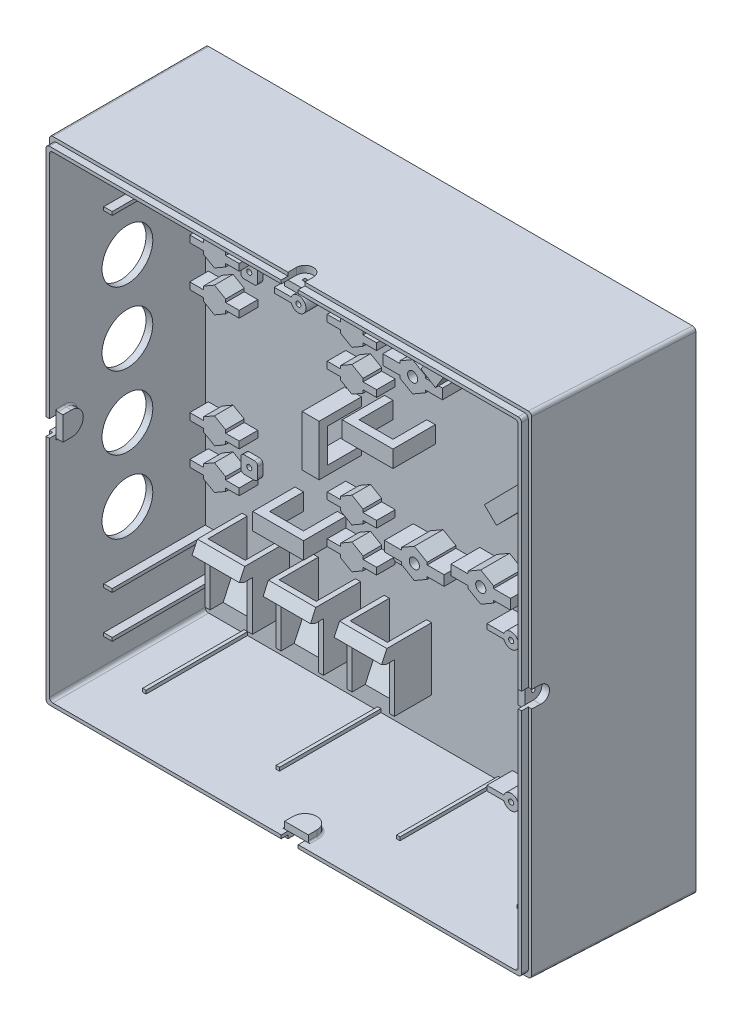
SolidWorks part; units mm, degrees
other "Markup1"
sketch "Sketch65" plane through (0, 0, 62.5) normal (-0.1104, 0.1177, 0.9869) x (-0.0079, -0.993, 0.1175)
other "Markup2"
sketch "Sketch102" plane through (0, -290, 96.1) normal (-0.2683, -0.6554, 0.706) x (0.9568, -0.2664, 0.1164)
ref_plane "Front Plane" through (0, 0, 0) normal (0, 0, 1) x (1, 0, 0)
ref_plane "Top Plane" through (0, 0, 0) normal (0, 1, 0) x (1, 0, 0)
ref_plane "Right Plane" through (0, 0, 0) normal (1, 0, 0) x (0, 0, -1)
sketch "Sketch1" plane through (0, 0, 0) normal (0, 0, 1) x (1, 0, 0)
  line L1 (2, 0) -> (285, 0)
  line L2 (0, -2) -> (0, -288)
  line L3 (2, -290) -> (285, -290)
  line L4 (285, 0) -> (285, -290)
  arc A7 (0, -288) -> (2, -290) centre (2, -288) ccw
  arc A8 (2, 0) -> (0, -2) centre (2, -2) ccw
  point P13 (0, 0)
  dimension "D4" = 2
  dimension "D1" = 290
  dimension "D2" = 285
extrude "Boss-Extrude2" add sketch "Sketch1" along normal blind 4
sketch "Sketch2" plane through (0, 0, 4) normal (0, 0, 1) x (1, 0, 0)
  line L0 (285, -290) -> (285, 0) construction
  line L1 (2, 0) -> (285, 0)
  line L2 (0, -2) -> (0, -288)
  line L3 (2, -290) -> (285, -290)
  line L4 (285, 0) -> (285, -290)
  line L5 (2, -290) -> (285, -290) construction
  arc A2 (0, -288) -> (2, -290) centre (2, -288) ccw
  arc A3 (2, 0) -> (0, -2) centre (2, -2) ccw
  point P17 (0, 0)
  dimension "D1" = 2
  dimension "D2" = 2
extrude "Extrude-Thin1" add sketch "Sketch2" along normal blind 88.1 thin thin type one direction reverse wall 4
sketch "Sketch3" plane through (0, 0, 4) normal (0, 0, 1) x (1, 0, 0)
  line B0 (228.21, -42.4895) -> (228.21, -45.3762)
  line B1 (238.41, -45.3762) -> (240.91, -43.9329)
  line B2 (240.91, -43.9329) -> (240.91, -35.1571)
  line B3 (240.91, -35.1571) -> (233.31, -30.7693)
  line B4 (233.31, -30.7693) -> (225.71, -35.1571)
  line B5 (225.71, -35.1571) -> (225.71, -43.9329)
  line B6 (225.71, -43.9329) -> (228.21, -45.3762)
  line B7 (233.31, -45.434) -> (238.41, -42.4895) construction
  line B8 (238.41, -42.4895) -> (238.41, -36.6005)
  line B9 (238.41, -36.6005) -> (233.31, -33.656)
  line B10 (233.31, -33.656) -> (228.21, -36.6005)
  line B11 (228.21, -36.6005) -> (228.21, -42.4895)
  line B12 (228.21, -42.4895) -> (233.31, -45.434) construction
  line B13 (238.41, -42.4895) -> (238.41, -45.3762)
  arc B14 (238.41, -45.1797) -> (228.21, -45.1797) centre (233.31, -39.545) ccw construction
  circle B15 centre (233.31, -39.545) radius 3 construction
  circle B16 centre (233.31, -39.545) radius 2.5 construction
  line B17 (264.21, -97.2395) -> (264.21, -100.1262)
  line B18 (274.41, -100.1262) -> (276.91, -98.6829)
  line B19 (276.91, -98.6829) -> (276.91, -89.9071)
  line B20 (276.91, -89.9071) -> (269.31, -85.5193)
  line B21 (269.31, -85.5193) -> (261.71, -89.9071)
  line B22 (261.71, -89.9071) -> (261.71, -98.6829)
  line B23 (261.71, -98.6829) -> (264.21, -100.1262)
  line B24 (274.41, -97.2395) -> (274.41, -91.3505)
  line B25 (274.41, -91.3505) -> (269.31, -88.406)
  line B26 (269.31, -88.406) -> (264.21, -91.3505)
  line B27 (264.21, -91.3505) -> (264.21, -97.2395)
  line B28 (274.41, -97.2395) -> (274.41, -100.1262)
  line B29 (138.46, -90.7395) -> (138.46, -93.6262)
  line B30 (148.66, -93.6262) -> (151.16, -92.1829)
  line B31 (151.16, -92.1829) -> (151.16, -83.4071)
  line B32 (151.16, -83.4071) -> (143.56, -79.0193)
  line B33 (143.56, -79.0193) -> (135.96, -83.4071)
  line B34 (135.96, -83.4071) -> (135.96, -92.1829)
  line B35 (135.96, -92.1829) -> (138.46, -93.6262)
  line B36 (148.66, -90.7395) -> (148.66, -84.8505)
  line B37 (148.66, -84.8505) -> (143.56, -81.906)
  line B38 (143.56, -81.906) -> (138.46, -84.8505)
  line B39 (138.46, -84.8505) -> (138.46, -90.7395)
  line B40 (148.66, -90.7395) -> (148.66, -93.6262)
  line B41 (139.46, -185.7395) -> (139.46, -188.6262)
  line B42 (149.66, -188.6262) -> (152.16, -187.1829)
  line B43 (152.16, -187.1829) -> (152.16, -178.4071)
  line B44 (152.16, -178.4071) -> (144.56, -174.0193)
  line B45 (144.56, -174.0193) -> (136.96, -178.4071)
  line B46 (136.96, -178.4071) -> (136.96, -187.1829)
  line B47 (136.96, -187.1829) -> (139.46, -188.6262)
  line B48 (149.66, -185.7395) -> (149.66, -179.8505)
  line B49 (149.66, -179.8505) -> (144.56, -176.906)
  line B50 (144.56, -176.906) -> (139.46, -179.8505)
  line B51 (139.46, -179.8505) -> (139.46, -185.7395)
  line B52 (149.66, -185.7395) -> (149.66, -188.6262)
  line B53 (178.71, -178.2395) -> (178.71, -181.1262)
  line B54 (188.91, -181.1262) -> (191.41, -179.6829)
  line B55 (191.41, -179.6829) -> (191.41, -170.9071)
  line B56 (191.41, -170.9071) -> (183.81, -166.5193)
  line B57 (183.81, -166.5193) -> (176.21, -170.9071)
  line B58 (176.21, -170.9071) -> (176.21, -179.6829)
  line B59 (176.21, -179.6829) -> (178.71, -181.1262)
  line B60 (188.91, -178.2395) -> (188.91, -172.3505)
  line B61 (188.91, -172.3505) -> (183.81, -169.406)
  line B62 (183.81, -169.406) -> (178.71, -172.3505)
  line B63 (178.71, -172.3505) -> (178.71, -178.2395)
  line B64 (188.91, -178.2395) -> (188.91, -181.1262)
  line B65 (267.46, -190.9895) -> (267.46, -193.8762)
  line B66 (277.66, -193.8762) -> (280.16, -192.4329)
  line B67 (280.16, -192.4329) -> (280.16, -183.6571)
  line B68 (280.16, -183.6571) -> (272.56, -179.2693)
  line B69 (272.56, -179.2693) -> (264.96, -183.6571)
  line B70 (264.96, -183.6571) -> (264.96, -192.4329)
  line B71 (264.96, -192.4329) -> (267.46, -193.8762)
  line B72 (277.66, -190.9895) -> (277.66, -185.1005)
  line B73 (277.66, -185.1005) -> (272.56, -182.156)
  line B74 (272.56, -182.156) -> (267.46, -185.1005)
  line B75 (267.46, -185.1005) -> (267.46, -190.9895)
  line B76 (277.66, -190.9895) -> (277.66, -193.8762)
sketch_block_instance "Block25-1"
sketch_block "Block25" parameters "D3"=5, "D4"=6, "D1"=10.2, "D2"=15.2
sketch_block_instance "Block25-3"
sketch_block_instance "Block25-4"
sketch_block_instance "Block25-5"
sketch_block_instance "Block25-6"
sketch_block_instance "Block25-7"
extrude "Boss-Extrude3" add sketch "Sketch3" along normal blind 12
sketch "Sketch98" plane through (0, 0, 16) normal (0, 0, 1) x (1, 0, 0)
  line L8 (233.31, -30.7693) -> (225.71, -35.1571) construction
  line L15 (233.31, -30.7693) -> (225.71, -35.1571)
  line L16 (225.71, -35.1571) -> (225.71, -43.9329)
  line L17 (225.71, -43.9329) -> (233.31, -48.3207)
  line L18 (233.31, -48.3207) -> (240.91, -43.9329)
  line L19 (240.91, -43.9329) -> (240.91, -35.1571)
  line L20 (240.91, -35.1571) -> (233.31, -30.7693)
  line L21 (151.16, -83.4071) -> (143.56, -79.0193) construction
  line L22 (143.56, -79.0193) -> (135.96, -83.4071)
  line L23 (135.96, -83.4071) -> (135.96, -92.1829)
  line L24 (135.96, -92.1829) -> (143.56, -96.5707)
  line L25 (143.56, -96.5707) -> (151.16, -92.1829)
  line L26 (151.16, -92.1829) -> (151.16, -83.4071)
  line L27 (151.16, -83.4071) -> (143.56, -79.0193)
  line L28 (135.96, -83.4071) -> (135.96, -92.1829) construction
  line L29 (272.56, -179.2693) -> (264.96, -183.6571) construction
  line L30 (269.31, -85.5193) -> (261.71, -89.9071)
  line L31 (261.71, -89.9071) -> (261.71, -98.6829)
  line L32 (261.71, -98.6829) -> (269.31, -103.0707)
  line L33 (269.31, -103.0707) -> (276.91, -98.6829)
  line L34 (276.91, -98.6829) -> (276.91, -89.9071)
  line L35 (276.91, -89.9071) -> (269.31, -85.5193)
  line L36 (272.56, -179.2693) -> (264.96, -183.6571)
  line L37 (264.96, -183.6571) -> (264.96, -192.4329)
  line L38 (264.96, -192.4329) -> (272.56, -196.8207)
  line L39 (272.56, -196.8207) -> (280.16, -192.4329)
  line L40 (280.16, -192.4329) -> (280.16, -183.6571)
  line L41 (280.16, -183.6571) -> (272.56, -179.2693)
  line L43 (183.81, -166.5193) -> (176.21, -170.9071)
  line L44 (176.21, -170.9071) -> (176.21, -179.6829)
  line L45 (176.21, -179.6829) -> (183.81, -184.0707)
  line L46 (183.81, -184.0707) -> (191.41, -179.6829)
  line L47 (191.41, -179.6829) -> (191.41, -170.9071)
  line L48 (191.41, -170.9071) -> (183.81, -166.5193)
  line L49 (144.56, -174.0193) -> (136.96, -178.4071)
  line L50 (136.96, -178.4071) -> (136.96, -187.1829)
  line L51 (136.96, -187.1829) -> (144.56, -191.5707)
  line L52 (144.56, -191.5707) -> (152.16, -187.1829)
  line L53 (152.16, -187.1829) -> (152.16, -178.4071)
  line L54 (152.16, -178.4071) -> (144.56, -174.0193)
  circle A0 centre (233.31, -39.545) radius 7.6 construction
  circle A1 centre (143.56, -87.795) radius 7.6 construction
  circle A2 centre (269.31, -94.295) radius 7.6 construction
  circle A3 centre (272.56, -188.045) radius 7.6 construction
  circle A4 centre (183.81, -175.295) radius 7.6 construction
  circle A5 centre (144.56, -182.795) radius 7.6 construction
extrude "Boss-Extrude36" add sketch "Sketch98" along normal blind 5
sketch "Sketch100" plane through (0, 0, 21) normal (0, 0, 1) x (1, 0, 0)
  line L0 (135.96, -92.1829) -> (143.56, -96.5707) construction
  line B0 (228.21, -42.4895) -> (228.21, -45.3762)
  line B1 (233.31, -48.3207) -> (238.41, -45.3762)
  line B2 (228.21, -45.3762) -> (233.31, -48.3207)
  line B3 (233.31, -45.434) -> (238.41, -42.4895)
  line B4 (228.21, -42.4895) -> (233.31, -45.434)
  line B5 (238.41, -42.4895) -> (238.41, -45.3762)
  circle B6 centre (233.31, -39.545) radius 7.6 construction
  circle B7 centre (233.31, -39.545) radius 5.1 construction
  line B8 (264.21, -97.2395) -> (264.21, -100.1262)
  line B9 (269.31, -103.0707) -> (274.41, -100.1262)
  line B10 (264.21, -100.1262) -> (269.31, -103.0707)
  line B11 (269.31, -100.184) -> (274.41, -97.2395)
  line B12 (264.21, -97.2395) -> (269.31, -100.184)
  line B13 (274.41, -97.2395) -> (274.41, -100.1262)
  circle B14 centre (269.31, -94.295) radius 7.6 construction
  circle B15 centre (269.31, -94.295) radius 5.1 construction
  line B16 (138.46, -90.7395) -> (138.46, -93.6262)
  line B17 (143.56, -96.5707) -> (148.66, -93.6262)
  line B18 (138.46, -93.6262) -> (143.56, -96.5707)
  line B19 (143.56, -93.684) -> (148.66, -90.7395)
  line B20 (138.46, -90.7395) -> (143.56, -93.684)
  line B21 (148.66, -90.7395) -> (148.66, -93.6262)
  circle B22 centre (143.56, -87.795) radius 7.6 construction
  circle B23 centre (143.56, -87.795) radius 5.1 construction
  line B24 (139.46, -185.7395) -> (139.46, -188.6262)
  line B25 (144.56, -191.5707) -> (149.66, -188.6262)
  line B26 (139.46, -188.6262) -> (144.56, -191.5707)
  line B27 (144.56, -188.684) -> (149.66, -185.7395)
  line B28 (139.46, -185.7395) -> (144.56, -188.684)
  line B29 (149.66, -185.7395) -> (149.66, -188.6262)
  circle B30 centre (144.56, -182.795) radius 7.6 construction
  circle B31 centre (144.56, -182.795) radius 5.1 construction
  line B32 (178.71, -178.2395) -> (178.71, -181.1262)
  line B33 (183.81, -184.0707) -> (188.91, -181.1262)
  line B34 (178.71, -181.1262) -> (183.81, -184.0707)
  line B35 (183.81, -181.184) -> (188.91, -178.2395)
  line B36 (178.71, -178.2395) -> (183.81, -181.184)
  line B37 (188.91, -178.2395) -> (188.91, -181.1262)
  circle B38 centre (183.81, -175.295) radius 7.6 construction
  circle B39 centre (183.81, -175.295) radius 5.1 construction
  line B40 (267.46, -190.9895) -> (267.46, -193.8762)
  line B41 (272.56, -196.8207) -> (277.66, -193.8762)
  line B42 (267.46, -193.8762) -> (272.56, -196.8207)
  line B43 (272.56, -193.934) -> (277.66, -190.9895)
  line B44 (267.46, -190.9895) -> (272.56, -193.934)
  line B45 (277.66, -190.9895) -> (277.66, -193.8762)
  circle B46 centre (272.56, -188.045) radius 7.6 construction
  circle B47 centre (272.56, -188.045) radius 5.1 construction
  line M161 (225.71, -43.9329) -> (233.31, -48.3207)
  line M162 (233.31, -48.3207) -> (240.91, -43.9329)
sketch_block_instance "Block26-1"
sketch_block "Block26" parameters "D1"=10.2, "D2"=15.2
sketch_block_instance "Block26-2"
sketch_block_instance "Block26-3"
sketch_block_instance "Block26-4"
sketch_block_instance "Block26-5"
sketch_block_instance "Block26-6"
extrude "Boss-Extrude37" add sketch "Sketch100" against normal blind 10 contours B5 B3 B4 B0 M161 M162 | B21 B19 B20 B16 B18 B17 | B29 B27 B28 B24 B26 B25 | B37 B35 B36 B32 B34 B33 | B45 B43 B44 B40 B42 B41 | B13 B11 B12 B8 B10 B9 region at (230.7013, -44.0635, 21) region at (266.7013, -98.8135, 21) region at (140.9513, -92.3135, 21) region at (141.9513, -187.3135, 21) region at (181.2013, -179.8135, 21) region at (269.9513, -192.5635, 21)
sketch "Sketch26" plane through (0, 0, 21) normal (0, 0, 1) x (1, 0, 0)
  point P0 (143.56, -87.795)
  point P1 (144.56, -182.795)
  point P3 (183.81, -175.295)
  point P5 (272.56, -188.045)
  point P7 (269.31, -94.295)
  point P9 (233.31, -39.545)
hole_wizard "Ø6.0 (6) Diameter Hole1" positions "3DSketch7" profile "Sketch27" hole size "Ø6.0" standard "ISO"
sketch3d "3DSketch7"
  point P97 (233.31, -39.545, 21)
  point P100 (143.56, -87.795, 21)
  point P103 (144.56, -182.795, 21)
  point P106 (183.81, -175.295, 21)
  point P109 (269.31, -94.295, 21)
  point P112 (272.56, -188.045, 21)
sketch "Sketch27" plane through (233.31, -39.545, 21) normal (1, 0, 0) x (0, -1, 0)
  line L0 (0, 0) -> (0, 8)
  line L1 (0, 8) -> (3, 6.1974)
  line L2 (3, 6.1974) -> (3, 0)
  line L5 (3, 0) -> (0, 0)
  line L10 (0, 8) -> (-3, 6.1974) construction
  line L11 (0, -6.35) -> (0, 107.95) construction
  dimension "Hole Dia." = 6
  dimension "Hole Depth" = 8
  dimension "Drill Angle" = 118
sketch "Sketch4" plane through (0, 0, 4) normal (0, 0, 1) x (1, 0, 0)
  line L0 (281, -286) -> (281, -4) construction
  line L5 (4, -286) -> (281, -286) construction
  line L6 (281, -145) -> (4, -145) construction
  line L7 (269, -256) -> (263, -256)
  line L8 (271, -254) -> (271, -248)
  line L9 (269, -246) -> (263, -246)
  line L10 (261, -254) -> (261, -248)
  line L11 (4, -4) -> (4, -286) construction
  line L12 (142.5, -286) -> (142.5, -4) construction
  line L13 (281, -4) -> (4, -4) construction
  line L38 (14, -251) -> (24, -251) construction
  line L39 (271, -256) -> (263, -256)
  line L52 (4, -286) -> (281, -286) construction
  line L53 (271, -251) -> (261, -251) construction
  line L54 (271, -246) -> (263, -246)
  line L55 (271, -256) -> (263, -256)
  line L56 (271, -246) -> (263, -246)
  line L57 (271, -256) -> (263, -256)
  line L58 (271, -246) -> (263, -246)
  line L59 (271, -256) -> (263, -256)
  line L60 (271, -246) -> (263, -246)
  line L61 (271, -256) -> (263, -256)
  line L62 (271, -246) -> (263, -246)
  line L63 (271, -256) -> (263, -256)
  line L64 (271, -246) -> (263, -246)
  line L65 (271, -256) -> (263, -256)
  line L66 (271, -246) -> (263, -246)
  line L67 (271, -256) -> (263, -256)
  line L68 (271, -246) -> (263, -246)
  line L69 (271, -256) -> (263, -256)
  line L70 (271, -246) -> (263, -246)
  line L71 (271, -256) -> (263, -256)
  line L72 (271, -246) -> (263, -246)
  line L73 (271, -256) -> (263, -256)
  line L74 (271, -246) -> (263, -246)
  line L75 (271, -256) -> (263, -256)
  line L76 (271, -246) -> (263, -246)
  line L77 (271, -256) -> (263, -256)
  line L78 (271, -246) -> (263, -246)
  line L79 (271, -256) -> (263, -256)
  line L80 (271, -246) -> (263, -246)
  line L81 (271, -256) -> (263, -256)
  line L82 (271, -246) -> (263, -246)
  line L83 (271, -256) -> (263, -256)
  line L84 (271, -246) -> (263, -246)
  line L85 (271, -256) -> (263, -256)
  line L86 (271, -246) -> (263, -246)
  line L87 (271, -256) -> (263, -256)
  line L88 (271, -246) -> (263, -246)
  line L89 (271, -256) -> (263, -256)
  line L90 (271, -246) -> (263, -246)
  line L91 (271, -256) -> (263, -256)
  line L92 (271, -246) -> (263, -246)
  line L93 (271, -256) -> (263, -256)
  line L94 (271, -246) -> (263, -246)
  line L95 (271, -256) -> (263, -256)
  line L96 (271, -246) -> (263, -246)
  line L97 (271, -256) -> (263, -256)
  line L98 (271, -246) -> (263, -246)
  line L99 (271, -256) -> (263, -256)
  line L100 (271, -246) -> (263, -246)
  line L101 (271, -256) -> (263, -256)
  line L102 (271, -246) -> (263, -246)
  line L103 (271, -256) -> (263, -256)
  line L104 (271, -246) -> (263, -246)
  line L105 (271, -256) -> (263, -256)
  line L106 (271, -246) -> (263, -246)
  line L107 (271, -256) -> (263, -256)
  line L108 (271, -246) -> (263, -246)
  line L109 (271, -256) -> (263, -256)
  line L110 (271, -246) -> (263, -246)
  line L111 (271, -256) -> (263, -256)
  line L112 (271, -246) -> (263, -246)
  line L113 (271, -256) -> (263, -256)
  line L114 (271, -246) -> (263, -246)
  line L115 (14, -246) -> (22, -246)
  line L116 (14, -256) -> (22, -256)
  line L117 (14, -246) -> (22, -246)
  line L118 (14, -256) -> (22, -256)
  line L119 (14, -246) -> (22, -246)
  line L120 (14, -256) -> (22, -256)
  line L121 (14, -246) -> (22, -246)
  line L122 (14, -256) -> (22, -256)
  line L123 (14, -246) -> (22, -246)
  line L124 (14, -256) -> (22, -256)
  line L125 (14, -246) -> (22, -246)
  line L126 (14, -256) -> (22, -256)
  line L127 (14, -246) -> (22, -246)
  line L128 (14, -256) -> (22, -256)
  line L129 (14, -246) -> (22, -246)
  line L130 (14, -256) -> (22, -256)
  line L131 (14, -246) -> (22, -246)
  line L132 (14, -256) -> (22, -256)
  line L133 (14, -246) -> (22, -246)
  line L134 (14, -256) -> (22, -256)
  line L135 (14, -246) -> (22, -246)
  line L136 (14, -256) -> (22, -256)
  line L137 (14, -246) -> (22, -246)
  line L138 (14, -256) -> (22, -256)
  line L139 (14, -246) -> (22, -246)
  line L140 (14, -256) -> (22, -256)
  line L141 (14, -246) -> (22, -246)
  line L142 (14, -256) -> (22, -256)
  line L143 (14, -246) -> (22, -246)
  line L144 (14, -256) -> (22, -256)
  line L145 (14, -246) -> (22, -246)
  line L146 (14, -256) -> (22, -256)
  line L147 (14, -246) -> (22, -246)
  line L148 (14, -256) -> (22, -256)
  line L149 (14, -246) -> (22, -246)
  line L150 (14, -256) -> (22, -256)
  line L151 (14, -246) -> (22, -246)
  line L152 (14, -256) -> (22, -256)
  line L153 (14, -246) -> (22, -246)
  line L154 (14, -256) -> (22, -256)
  line L155 (14, -246) -> (22, -246)
  line L156 (14, -256) -> (22, -256)
  line L157 (14, -246) -> (22, -246)
  line L158 (14, -256) -> (22, -256)
  line L159 (14, -246) -> (22, -246)
  line L160 (14, -256) -> (22, -256)
  line L161 (14, -246) -> (22, -246)
  line L162 (14, -256) -> (22, -256)
  line L163 (14, -246) -> (22, -246)
  line L164 (14, -256) -> (22, -256)
  line L165 (14, -246) -> (22, -246)
  line L166 (14, -256) -> (22, -256)
  line L167 (14, -246) -> (22, -246)
  line L168 (14, -256) -> (22, -256)
  line L169 (14, -246) -> (22, -246)
  line L170 (14, -256) -> (22, -256)
  line L171 (14, -246) -> (22, -246)
  line L172 (14, -256) -> (22, -256)
  line L173 (14, -246) -> (22, -246)
  line L174 (14, -256) -> (22, -256)
  line L175 (14, -246) -> (22, -246)
  line L176 (14, -256) -> (22, -256)
  line L177 (24, -254) -> (24, -248)
  line L178 (16, -246) -> (22, -246)
  line L179 (14, -254) -> (14, -248)
  line L180 (16, -256) -> (22, -256)
  line L181 (271, -39) -> (261, -39) construction
  line L182 (271, -44) -> (263, -44)
  line L183 (271, -34) -> (263, -34)
  line L184 (271, -44) -> (263, -44)
  line L185 (271, -34) -> (263, -34)
  line L186 (271, -44) -> (263, -44)
  line L187 (271, -34) -> (263, -34)
  line L188 (271, -44) -> (263, -44)
  line L189 (271, -34) -> (263, -34)
  line L190 (271, -44) -> (263, -44)
  line L191 (271, -34) -> (263, -34)
  line L192 (271, -44) -> (263, -44)
  line L193 (271, -34) -> (263, -34)
  line L194 (271, -44) -> (263, -44)
  line L195 (271, -34) -> (263, -34)
  line L196 (271, -44) -> (263, -44)
  line L197 (271, -34) -> (263, -34)
  line L198 (271, -44) -> (263, -44)
  line L199 (271, -34) -> (263, -34)
  line L200 (271, -44) -> (263, -44)
  line L201 (271, -34) -> (263, -34)
  line L202 (271, -44) -> (263, -44)
  line L203 (271, -34) -> (263, -34)
  line L204 (271, -44) -> (263, -44)
  line L205 (271, -34) -> (263, -34)
  line L206 (271, -44) -> (263, -44)
  line L207 (271, -34) -> (263, -34)
  line L208 (271, -44) -> (263, -44)
  line L209 (271, -34) -> (263, -34)
  line L210 (271, -44) -> (263, -44)
  line L211 (271, -34) -> (263, -34)
  line L212 (271, -44) -> (263, -44)
  line L213 (271, -34) -> (263, -34)
  line L214 (271, -44) -> (263, -44)
  line L215 (271, -34) -> (263, -34)
  line L216 (271, -44) -> (263, -44)
  line L217 (271, -34) -> (263, -34)
  line L218 (271, -44) -> (263, -44)
  line L219 (271, -34) -> (263, -34)
  line L220 (271, -44) -> (263, -44)
  line L221 (271, -34) -> (263, -34)
  line L222 (271, -44) -> (263, -44)
  line L223 (271, -34) -> (263, -34)
  line L224 (271, -44) -> (263, -44)
  line L225 (271, -34) -> (263, -34)
  line L226 (271, -44) -> (263, -44)
  line L227 (271, -34) -> (263, -34)
  line L228 (271, -44) -> (263, -44)
  line L229 (271, -34) -> (263, -34)
  line L230 (271, -44) -> (263, -44)
  line L231 (271, -34) -> (263, -34)
  line L232 (271, -44) -> (263, -44)
  line L233 (271, -34) -> (263, -34)
  line L234 (271, -44) -> (263, -44)
  line L235 (271, -34) -> (263, -34)
  line L236 (271, -44) -> (263, -44)
  line L237 (271, -34) -> (263, -34)
  line L238 (271, -44) -> (263, -44)
  line L239 (271, -34) -> (263, -34)
  line L240 (271, -44) -> (263, -44)
  line L241 (271, -34) -> (263, -34)
  line L242 (271, -44) -> (263, -44)
  line L243 (271, -34) -> (263, -34)
  line L244 (261, -36) -> (261, -42)
  line L250 (269, -44) -> (263, -44)
  line L251 (271, -36) -> (271, -42)
  line L252 (269, -34) -> (263, -34)
  line L253 (14, -39) -> (24, -39) construction
  line L254 (16, -34) -> (22, -34)
  line L255 (14, -36) -> (14, -42)
  line L256 (16, -44) -> (22, -44)
  line L257 (24, -36) -> (24, -42)
  line L258 (14, -34) -> (22, -34)
  line L259 (14, -44) -> (22, -44)
  line L260 (14, -34) -> (22, -34)
  line L261 (14, -44) -> (22, -44)
  line L262 (14, -34) -> (22, -34)
  line L263 (14, -44) -> (22, -44)
  line L264 (14, -34) -> (22, -34)
  line L265 (14, -44) -> (22, -44)
  line L266 (14, -34) -> (22, -34)
  line L267 (14, -44) -> (22, -44)
  line L268 (14, -34) -> (22, -34)
  line L269 (14, -44) -> (22, -44)
  line L270 (14, -34) -> (22, -34)
  line L271 (14, -44) -> (22, -44)
  line L272 (14, -34) -> (22, -34)
  line L273 (14, -44) -> (22, -44)
  line L274 (14, -34) -> (22, -34)
  line L275 (14, -44) -> (22, -44)
  line L276 (14, -34) -> (22, -34)
  line L277 (14, -44) -> (22, -44)
  line L278 (14, -34) -> (22, -34)
  line L279 (14, -44) -> (22, -44)
  line L280 (14, -34) -> (22, -34)
  line L281 (14, -44) -> (22, -44)
  line L282 (14, -34) -> (22, -34)
  line L283 (14, -44) -> (22, -44)
  line L284 (14, -34) -> (22, -34)
  line L285 (14, -44) -> (22, -44)
  line L286 (14, -34) -> (22, -34)
  line L287 (14, -44) -> (22, -44)
  line L288 (14, -34) -> (22, -34)
  line L289 (14, -44) -> (22, -44)
  line L290 (14, -34) -> (22, -34)
  line L291 (14, -44) -> (22, -44)
  line L292 (14, -34) -> (22, -34)
  line L293 (14, -44) -> (22, -44)
  line L294 (14, -34) -> (22, -34)
  line L295 (14, -44) -> (22, -44)
  line L296 (14, -34) -> (22, -34)
  line L297 (14, -44) -> (22, -44)
  line L298 (14, -34) -> (22, -34)
  line L299 (14, -44) -> (22, -44)
  line L300 (14, -34) -> (22, -34)
  line L301 (14, -44) -> (22, -44)
  line L302 (14, -34) -> (22, -34)
  line L303 (14, -44) -> (22, -44)
  line L304 (14, -34) -> (22, -34)
  line L305 (14, -44) -> (22, -44)
  line L306 (14, -34) -> (22, -34)
  line L307 (14, -44) -> (22, -44)
  line L308 (14, -34) -> (22, -34)
  line L309 (14, -44) -> (22, -44)
  line L310 (14, -34) -> (22, -34)
  line L311 (14, -44) -> (22, -44)
  line L312 (14, -34) -> (22, -34)
  line L313 (14, -44) -> (22, -44)
  line L314 (14, -34) -> (22, -34)
  line L315 (14, -44) -> (22, -44)
  line L316 (14, -34) -> (22, -34)
  line L317 (14, -44) -> (22, -44)
  line L318 (14, -34) -> (22, -34)
  line L319 (14, -44) -> (22, -44)
  arc A1 (263, -246) -> (261, -248) centre (263, -248) ccw
  arc A11 (263, -256) -> (261, -254) centre (263, -254) cw
  circle A12 centre (266, -251) radius 2
  arc A13 (263, -246) -> (261, -248) centre (263, -248) ccw
  arc A14 (263, -256) -> (261, -254) centre (263, -254) cw
  arc A15 (263, -246) -> (261, -248) centre (263, -248) ccw
  arc A16 (263, -256) -> (261, -254) centre (263, -254) cw
  arc A17 (263, -246) -> (261, -248) centre (263, -248) ccw
  arc A18 (263, -256) -> (261, -254) centre (263, -254) cw
  arc A19 (263, -246) -> (261, -248) centre (263, -248) ccw
  arc A20 (263, -256) -> (261, -254) centre (263, -254) cw
  arc A21 (263, -246) -> (261, -248) centre (263, -248) ccw
  arc A22 (263, -256) -> (261, -254) centre (263, -254) cw
  arc A23 (263, -246) -> (261, -248) centre (263, -248) ccw
  arc A24 (263, -256) -> (261, -254) centre (263, -254) cw
  arc A25 (263, -246) -> (261, -248) centre (263, -248) ccw
  arc A26 (263, -256) -> (261, -254) centre (263, -254) cw
  arc A27 (263, -246) -> (261, -248) centre (263, -248) ccw
  arc A28 (263, -256) -> (261, -254) centre (263, -254) cw
  arc A29 (263, -246) -> (261, -248) centre (263, -248) ccw
  arc A30 (263, -256) -> (261, -254) centre (263, -254) cw
  arc A31 (263, -246) -> (261, -248) centre (263, -248) ccw
  arc A32 (263, -256) -> (261, -254) centre (263, -254) cw
  arc A33 (263, -246) -> (261, -248) centre (263, -248) ccw
  arc A34 (263, -256) -> (261, -254) centre (263, -254) cw
  arc A35 (263, -246) -> (261, -248) centre (263, -248) ccw
  arc A36 (263, -256) -> (261, -254) centre (263, -254) cw
  arc A37 (263, -246) -> (261, -248) centre (263, -248) ccw
  arc A38 (263, -256) -> (261, -254) centre (263, -254) cw
  arc A39 (263, -246) -> (261, -248) centre (263, -248) ccw
  arc A40 (263, -256) -> (261, -254) centre (263, -254) cw
  arc A41 (263, -246) -> (261, -248) centre (263, -248) ccw
  arc A42 (263, -256) -> (261, -254) centre (263, -254) cw
  arc A43 (263, -246) -> (261, -248) centre (263, -248) ccw
  arc A44 (263, -256) -> (261, -254) centre (263, -254) cw
  arc A45 (263, -246) -> (261, -248) centre (263, -248) ccw
  arc A46 (263, -256) -> (261, -254) centre (263, -254) cw
  arc A47 (263, -246) -> (261, -248) centre (263, -248) ccw
  arc A48 (263, -256) -> (261, -254) centre (263, -254) cw
  arc A49 (263, -246) -> (261, -248) centre (263, -248) ccw
  arc A50 (263, -256) -> (261, -254) centre (263, -254) cw
  arc A51 (263, -246) -> (261, -248) centre (263, -248) ccw
  arc A52 (263, -256) -> (261, -254) centre (263, -254) cw
  arc A53 (263, -246) -> (261, -248) centre (263, -248) ccw
  arc A54 (263, -256) -> (261, -254) centre (263, -254) cw
  arc A55 (263, -246) -> (261, -248) centre (263, -248) ccw
  arc A56 (263, -256) -> (261, -254) centre (263, -254) cw
  arc A57 (263, -246) -> (261, -248) centre (263, -248) ccw
  arc A58 (263, -256) -> (261, -254) centre (263, -254) cw
  arc A59 (263, -246) -> (261, -248) centre (263, -248) ccw
  arc A60 (263, -256) -> (261, -254) centre (263, -254) cw
  arc A61 (263, -246) -> (261, -248) centre (263, -248) ccw
  arc A62 (263, -256) -> (261, -254) centre (263, -254) cw
  arc A63 (263, -246) -> (261, -248) centre (263, -248) ccw
  arc A64 (263, -256) -> (261, -254) centre (263, -254) cw
  arc A65 (263, -246) -> (261, -248) centre (263, -248) ccw
  arc A66 (263, -256) -> (261, -254) centre (263, -254) cw
  arc A67 (263, -246) -> (261, -248) centre (263, -248) ccw
  arc A68 (263, -256) -> (261, -254) centre (263, -254) cw
  arc A69 (263, -246) -> (261, -248) centre (263, -248) ccw
  arc A70 (263, -256) -> (261, -254) centre (263, -254) cw
  arc A71 (263, -246) -> (261, -248) centre (263, -248) ccw
  arc A72 (263, -256) -> (261, -254) centre (263, -254) cw
  arc A73 (263, -246) -> (261, -248) centre (263, -248) ccw
  arc A74 (263, -256) -> (261, -254) centre (263, -254) cw
  arc A75 (14, -248) -> (16, -246) centre (16, -248) cw
  arc A76 (16, -256) -> (14, -254) centre (16, -254) cw
  arc A77 (22, -256) -> (24, -254) centre (22, -254) ccw
  arc A78 (22, -246) -> (24, -248) centre (22, -248) cw
  arc A79 (22, -256) -> (24, -254) centre (22, -254) ccw
  arc A80 (22, -246) -> (24, -248) centre (22, -248) cw
  arc A81 (22, -256) -> (24, -254) centre (22, -254) ccw
  arc A82 (22, -246) -> (24, -248) centre (22, -248) cw
  arc A83 (22, -256) -> (24, -254) centre (22, -254) ccw
  arc A84 (22, -246) -> (24, -248) centre (22, -248) cw
  arc A85 (22, -256) -> (24, -254) centre (22, -254) ccw
  arc A86 (22, -246) -> (24, -248) centre (22, -248) cw
  arc A87 (22, -256) -> (24, -254) centre (22, -254) ccw
  arc A88 (22, -246) -> (24, -248) centre (22, -248) cw
  arc A89 (22, -256) -> (24, -254) centre (22, -254) ccw
  arc A90 (22, -246) -> (24, -248) centre (22, -248) cw
  arc A91 (22, -256) -> (24, -254) centre (22, -254) ccw
  arc A92 (22, -246) -> (24, -248) centre (22, -248) cw
  arc A93 (22, -256) -> (24, -254) centre (22, -254) ccw
  arc A94 (22, -246) -> (24, -248) centre (22, -248) cw
  arc A95 (22, -256) -> (24, -254) centre (22, -254) ccw
  arc A96 (22, -246) -> (24, -248) centre (22, -248) cw
  arc A97 (22, -256) -> (24, -254) centre (22, -254) ccw
  arc A98 (22, -246) -> (24, -248) centre (22, -248) cw
  arc A99 (22, -256) -> (24, -254) centre (22, -254) ccw
  arc A100 (22, -246) -> (24, -248) centre (22, -248) cw
  arc A101 (22, -256) -> (24, -254) centre (22, -254) ccw
  arc A102 (22, -246) -> (24, -248) centre (22, -248) cw
  arc A103 (22, -256) -> (24, -254) centre (22, -254) ccw
  arc A104 (22, -246) -> (24, -248) centre (22, -248) cw
  arc A105 (22, -256) -> (24, -254) centre (22, -254) ccw
  arc A106 (22, -246) -> (24, -248) centre (22, -248) cw
  arc A107 (22, -256) -> (24, -254) centre (22, -254) ccw
  arc A108 (22, -246) -> (24, -248) centre (22, -248) cw
  arc A109 (22, -256) -> (24, -254) centre (22, -254) ccw
  arc A110 (22, -246) -> (24, -248) centre (22, -248) cw
  arc A111 (22, -256) -> (24, -254) centre (22, -254) ccw
  arc A112 (22, -246) -> (24, -248) centre (22, -248) cw
  arc A113 (22, -256) -> (24, -254) centre (22, -254) ccw
  arc A114 (22, -246) -> (24, -248) centre (22, -248) cw
  arc A115 (22, -256) -> (24, -254) centre (22, -254) ccw
  arc A116 (22, -246) -> (24, -248) centre (22, -248) cw
  arc A117 (22, -256) -> (24, -254) centre (22, -254) ccw
  arc A118 (22, -246) -> (24, -248) centre (22, -248) cw
  arc A119 (22, -256) -> (24, -254) centre (22, -254) ccw
  arc A120 (22, -246) -> (24, -248) centre (22, -248) cw
  arc A121 (22, -256) -> (24, -254) centre (22, -254) ccw
  arc A122 (22, -246) -> (24, -248) centre (22, -248) cw
  arc A123 (22, -256) -> (24, -254) centre (22, -254) ccw
  arc A124 (22, -246) -> (24, -248) centre (22, -248) cw
  arc A125 (22, -256) -> (24, -254) centre (22, -254) ccw
  arc A126 (22, -246) -> (24, -248) centre (22, -248) cw
  arc A127 (22, -256) -> (24, -254) centre (22, -254) ccw
  arc A128 (22, -246) -> (24, -248) centre (22, -248) cw
  arc A129 (22, -256) -> (24, -254) centre (22, -254) ccw
  arc A130 (22, -246) -> (24, -248) centre (22, -248) cw
  arc A131 (22, -256) -> (24, -254) centre (22, -254) ccw
  arc A132 (22, -246) -> (24, -248) centre (22, -248) cw
  arc A133 (22, -256) -> (24, -254) centre (22, -254) ccw
  arc A134 (22, -246) -> (24, -248) centre (22, -248) cw
  arc A140 (22, -256) -> (24, -254) centre (22, -254) ccw
  arc A141 (22, -246) -> (24, -248) centre (22, -248) cw
  arc A143 (22, -256) -> (24, -254) centre (22, -254) ccw
  arc A144 (22, -246) -> (24, -248) centre (22, -248) cw
  circle A145 centre (19, -251) radius 2
  arc A146 (22, -256) -> (24, -254) centre (22, -254) ccw
  arc A147 (22, -246) -> (24, -248) centre (22, -248) cw
  arc A148 (271, -42) -> (269, -44) centre (269, -42) cw
  arc A149 (269, -34) -> (271, -36) centre (269, -36) cw
  arc A150 (263, -34) -> (261, -36) centre (263, -36) ccw
  arc A151 (263, -44) -> (261, -42) centre (263, -42) cw
  arc A152 (263, -34) -> (261, -36) centre (263, -36) ccw
  arc A153 (263, -44) -> (261, -42) centre (263, -42) cw
  arc A154 (263, -34) -> (261, -36) centre (263, -36) ccw
  arc A155 (263, -44) -> (261, -42) centre (263, -42) cw
  arc A156 (263, -34) -> (261, -36) centre (263, -36) ccw
  arc A157 (263, -44) -> (261, -42) centre (263, -42) cw
  arc A158 (263, -34) -> (261, -36) centre (263, -36) ccw
  arc A159 (263, -44) -> (261, -42) centre (263, -42) cw
  arc A160 (263, -34) -> (261, -36) centre (263, -36) ccw
  arc A161 (263, -44) -> (261, -42) centre (263, -42) cw
  arc A162 (263, -34) -> (261, -36) centre (263, -36) ccw
  arc A163 (263, -44) -> (261, -42) centre (263, -42) cw
  arc A164 (263, -34) -> (261, -36) centre (263, -36) ccw
  arc A165 (263, -44) -> (261, -42) centre (263, -42) cw
  arc A166 (263, -34) -> (261, -36) centre (263, -36) ccw
  arc A167 (263, -44) -> (261, -42) centre (263, -42) cw
  arc A168 (263, -34) -> (261, -36) centre (263, -36) ccw
  arc A169 (263, -44) -> (261, -42) centre (263, -42) cw
  arc A170 (263, -34) -> (261, -36) centre (263, -36) ccw
  arc A171 (263, -44) -> (261, -42) centre (263, -42) cw
  arc A172 (263, -34) -> (261, -36) centre (263, -36) ccw
  arc A173 (263, -44) -> (261, -42) centre (263, -42) cw
  arc A174 (263, -34) -> (261, -36) centre (263, -36) ccw
  arc A175 (263, -44) -> (261, -42) centre (263, -42) cw
  arc A176 (263, -34) -> (261, -36) centre (263, -36) ccw
  arc A177 (263, -44) -> (261, -42) centre (263, -42) cw
  arc A178 (263, -34) -> (261, -36) centre (263, -36) ccw
  arc A179 (263, -44) -> (261, -42) centre (263, -42) cw
  arc A180 (263, -34) -> (261, -36) centre (263, -36) ccw
  arc A181 (263, -44) -> (261, -42) centre (263, -42) cw
  arc A182 (263, -34) -> (261, -36) centre (263, -36) ccw
  arc A183 (263, -44) -> (261, -42) centre (263, -42) cw
  arc A184 (263, -34) -> (261, -36) centre (263, -36) ccw
  arc A185 (263, -44) -> (261, -42) centre (263, -42) cw
  arc A186 (263, -34) -> (261, -36) centre (263, -36) ccw
  arc A187 (263, -44) -> (261, -42) centre (263, -42) cw
  arc A188 (263, -34) -> (261, -36) centre (263, -36) ccw
  arc A189 (263, -44) -> (261, -42) centre (263, -42) cw
  arc A190 (263, -34) -> (261, -36) centre (263, -36) ccw
  arc A191 (263, -44) -> (261, -42) centre (263, -42) cw
  arc A192 (263, -34) -> (261, -36) centre (263, -36) ccw
  arc A193 (263, -44) -> (261, -42) centre (263, -42) cw
  arc A194 (263, -34) -> (261, -36) centre (263, -36) ccw
  arc A195 (263, -44) -> (261, -42) centre (263, -42) cw
  arc A196 (263, -34) -> (261, -36) centre (263, -36) ccw
  arc A197 (263, -44) -> (261, -42) centre (263, -42) cw
  arc A198 (263, -34) -> (261, -36) centre (263, -36) ccw
  arc A199 (263, -44) -> (261, -42) centre (263, -42) cw
  arc A200 (263, -34) -> (261, -36) centre (263, -36) ccw
  arc A205 (263, -44) -> (261, -42) centre (263, -42) cw
  arc A206 (263, -34) -> (261, -36) centre (263, -36) ccw
  arc A207 (263, -44) -> (261, -42) centre (263, -42) cw
  arc A208 (263, -34) -> (261, -36) centre (263, -36) ccw
  arc A209 (263, -44) -> (261, -42) centre (263, -42) cw
  arc A210 (263, -34) -> (261, -36) centre (263, -36) ccw
  arc A211 (263, -44) -> (261, -42) centre (263, -42) cw
  arc A212 (263, -34) -> (261, -36) centre (263, -36) ccw
  arc A213 (263, -44) -> (261, -42) centre (263, -42) cw
  arc A214 (263, -34) -> (261, -36) centre (263, -36) ccw
  arc A215 (263, -44) -> (261, -42) centre (263, -42) cw
  circle A216 centre (266, -39) radius 2
  arc A217 (263, -34) -> (261, -36) centre (263, -36) ccw
  arc A218 (263, -44) -> (261, -42) centre (263, -42) cw
  arc A219 (22, -44) -> (24, -42) centre (22, -42) ccw
  arc A220 (22, -34) -> (24, -36) centre (22, -36) cw
  circle A221 centre (19, -39) radius 2
  arc A222 (22, -44) -> (24, -42) centre (22, -42) ccw
  arc A223 (22, -34) -> (24, -36) centre (22, -36) cw
  arc A224 (22, -44) -> (24, -42) centre (22, -42) ccw
  arc A225 (22, -34) -> (24, -36) centre (22, -36) cw
  arc A226 (22, -44) -> (24, -42) centre (22, -42) ccw
  arc A227 (22, -34) -> (24, -36) centre (22, -36) cw
  arc A228 (22, -44) -> (24, -42) centre (22, -42) ccw
  arc A229 (22, -34) -> (24, -36) centre (22, -36) cw
  arc A230 (22, -44) -> (24, -42) centre (22, -42) ccw
  arc A231 (22, -34) -> (24, -36) centre (22, -36) cw
  arc A232 (22, -44) -> (24, -42) centre (22, -42) ccw
  arc A233 (22, -34) -> (24, -36) centre (22, -36) cw
  arc A234 (22, -44) -> (24, -42) centre (22, -42) ccw
  arc A235 (22, -34) -> (24, -36) centre (22, -36) cw
  arc A236 (22, -44) -> (24, -42) centre (22, -42) ccw
  arc A237 (22, -34) -> (24, -36) centre (22, -36) cw
  arc A238 (22, -44) -> (24, -42) centre (22, -42) ccw
  arc A239 (22, -34) -> (24, -36) centre (22, -36) cw
  arc A240 (22, -44) -> (24, -42) centre (22, -42) ccw
  arc A241 (22, -34) -> (24, -36) centre (22, -36) cw
  arc A242 (22, -44) -> (24, -42) centre (22, -42) ccw
  arc A243 (22, -34) -> (24, -36) centre (22, -36) cw
  arc A244 (22, -44) -> (24, -42) centre (22, -42) ccw
  arc A245 (22, -34) -> (24, -36) centre (22, -36) cw
  arc A246 (22, -44) -> (24, -42) centre (22, -42) ccw
  arc A247 (22, -34) -> (24, -36) centre (22, -36) cw
  arc A248 (22, -44) -> (24, -42) centre (22, -42) ccw
  arc A249 (22, -34) -> (24, -36) centre (22, -36) cw
  arc A250 (22, -44) -> (24, -42) centre (22, -42) ccw
  arc A251 (22, -34) -> (24, -36) centre (22, -36) cw
  arc A252 (22, -44) -> (24, -42) centre (22, -42) ccw
  arc A253 (22, -34) -> (24, -36) centre (22, -36) cw
  arc A254 (22, -44) -> (24, -42) centre (22, -42) ccw
  arc A255 (22, -34) -> (24, -36) centre (22, -36) cw
  arc A256 (22, -44) -> (24, -42) centre (22, -42) ccw
  arc A257 (22, -34) -> (24, -36) centre (22, -36) cw
  arc A258 (22, -44) -> (24, -42) centre (22, -42) ccw
  arc A259 (22, -34) -> (24, -36) centre (22, -36) cw
  arc A260 (22, -44) -> (24, -42) centre (22, -42) ccw
  arc A261 (22, -34) -> (24, -36) centre (22, -36) cw
  arc A262 (22, -44) -> (24, -42) centre (22, -42) ccw
  arc A263 (22, -34) -> (24, -36) centre (22, -36) cw
  arc A264 (22, -44) -> (24, -42) centre (22, -42) ccw
  arc A270 (269, -256) -> (271, -254) centre (269, -254) ccw
  arc A271 (271, -248) -> (269, -246) centre (269, -248) ccw
  arc A272 (22, -34) -> (24, -36) centre (22, -36) cw
  arc A273 (22, -44) -> (24, -42) centre (22, -42) ccw
  arc A274 (22, -34) -> (24, -36) centre (22, -36) cw
  arc A275 (22, -44) -> (24, -42) centre (22, -42) ccw
  arc A276 (22, -34) -> (24, -36) centre (22, -36) cw
  arc A277 (22, -44) -> (24, -42) centre (22, -42) ccw
  arc A278 (22, -34) -> (24, -36) centre (22, -36) cw
  arc A279 (22, -44) -> (24, -42) centre (22, -42) ccw
  arc A280 (22, -34) -> (24, -36) centre (22, -36) cw
  arc A281 (22, -44) -> (24, -42) centre (22, -42) ccw
  arc A282 (22, -34) -> (24, -36) centre (22, -36) cw
  arc A283 (22, -44) -> (24, -42) centre (22, -42) ccw
  arc A284 (22, -34) -> (24, -36) centre (22, -36) cw
  arc A285 (22, -44) -> (24, -42) centre (22, -42) ccw
  arc A286 (22, -34) -> (24, -36) centre (22, -36) cw
  arc A287 (22, -44) -> (24, -42) centre (22, -42) ccw
  arc A288 (22, -34) -> (24, -36) centre (22, -36) cw
  arc A289 (22, -44) -> (24, -42) centre (22, -42) ccw
  arc A290 (22, -34) -> (24, -36) centre (22, -36) cw
  arc A291 (16, -34) -> (14, -36) centre (16, -36) ccw
  arc A292 (14, -42) -> (16, -44) centre (16, -42) ccw
  dimension "D5" = 30
  dimension "D4" = 10
  dimension "D3" = 2
  dimension "D6" = 4
  dimension "D7" = 2
  dimension "D1" = 10
  dimension "D2" = 10
extrude "Boss-Extrude6" add sketch "Sketch4" along normal blind 3 contours L8 A271 L9 A1 L10 A11 L7 A270 A12 | A151 L242 A148 L251 A149 L243 A150 L244 A216 | L255 A292 L256 A219 L257 A220 L254 A291 A221 | A78 L175 A75 L179 A76 L176 A77 L177 A145 region at (266, -255.8586, 4) region at (19, -246.1414, 4) region at (266, -43.8586, 4) region at (19, -34.1414, 4)
sketch "Sketch15" plane through (0, 0, 4) normal (0, 0, 1) x (1, 0, 0)
  line L0 (14.5, -20.5) -> (14.5, -12.5) construction
  line L2 (28.8, -225) -> (28.8, -262)
  line L4 (50.8, -225) -> (50.8, -262)
  line L5 (281, -4) -> (4, -4) construction
  line L8 (25.8, -225) -> (25.8, -262)
  line L10 (53.8, -225) -> (53.8, -262)
  line L11 (28.8, -262) -> (25.8, -262)
  line L12 (50.8, -262) -> (53.8, -262)
  line L13 (4, -286) -> (281, -286) construction
  line L14 (25.8, -225) -> (28.8, -225)
  line L15 (53.8, -225) -> (50.8, -225)
  line L16 (285, -290) -> (285, 0) construction
  dimension "D1" = 231.2
  dimension "D2" = 24
  dimension "D3" = 3
  dimension "D4" = 3
  dimension "D5" = 37
  dimension "D6" = 22
extrude "Boss-Extrude7" add sketch "Sketch15" along normal blind 17.5
sketch "Sketch16" plane through (28.8, 0, 0) normal (1, 0, 0) x (0, 0, -1)
  line L0 (-18.26, -262) -> (-4, -262)
  line L2 (-21.5, -262) -> (-4, -262) construction
  line L3 (-4, -262) -> (-4, -247)
  line L5 (-11.2654, -247) -> (-18.26, -262)
  line L6 (-4, -262) -> (-4, -225) construction
  line L8 (-11.2654, -247) -> (-4, -247)
  dimension "D1" = 25
  dimension "D2" = 15
  dimension "D3" = 14.26
extrude "Boss-Extrude8" add sketch "Sketch16" along normal up to surface (22 mm away) up to face at (50.8, -243.5, 12.75)
sketch "Sketch17" plane through (53.8, 0, 0) normal (1, 0, 0) x (0, 0, -1)
  line L3 (-30.9, -233) -> (-27.1695, -225)
  line L4 (-4, -262) -> (-4, -225) construction
  line L5 (-21.5, -225) -> (-4, -225) construction
  line L7 (-26, -233) -> (-26, -262)
  line L8 (-4, -262) -> (-4, -225)
  line L9 (-4, -225) -> (-21.5, -225)
  line L10 (-21.5, -225) -> (-21.5, -262)
  line L11 (-21.5, -262) -> (-4, -262)
  line L15 (-26, -262) -> (-4, -262)
  line L16 (-4, -225) -> (-27.1695, -225)
  line L17 (-30.9, -233) -> (-26, -233)
  line L21 (-4, -262) -> (-4, -225)
  line M6 (-21.5, -225) -> (-21.5, -262)
  dimension "D1" = 4.9
  dimension "D2" = 22
  dimension "D4" = 25
  dimension "D6" = 8
  dimension "D3" = 0
extrude "Boss-Extrude10" add sketch "Sketch17" against normal up to surface (28 mm away) contours L3 M6 region at (53.8, -241.759, 24.2537) up to face at (25.8, -243.5, 12.75)
sketch "Sketch18" plane through (0, -29.7799, -63.8631) normal (0, 0.4226, 0.9063) x (1, 0, 0)
  line L1 (28.8, -224.2286) -> (50.8, -224.2286)
  line L2 (28.8, -224.2286) -> (28.8, -201.9863)
  line L3 (28.8, -201.9863) -> (50.8, -201.9863)
  line L4 (50.8, -224.2286) -> (50.8, -201.9863)
  line L5 (28.8, -201.9863) -> (50.8, -201.9863) construction
  line L6 (25.8, -224.2286) -> (53.8, -224.2286) construction
  line L8 (50.8, -213.0055) -> (50.8, -205.6097) construction
  line L9 (28.8, -213.0055) -> (28.8, -205.6097) construction
extrude "Cut-Extrude1" cut sketch "Sketch18" against normal up to surface (26.3707 mm away) up to face at (268, -251, 7)
sketch "Sketch19" plane through (0, -29.7799, -63.8631) normal (0, 0.4226, 0.9063) x (1, 0, 0)
  line L0 (50.8, -224.2286) -> (53.8, -224.2286) construction
  line L1 (53.8, -224.2286) -> (25.8, -224.2286)
  line L2 (53.8, -224.2286) -> (53.8, -215.4016)
  line L3 (53.8, -215.4016) -> (25.8, -215.4016)
  line L4 (25.8, -224.2286) -> (25.8, -215.4016)
  line L5 (53.8, -239.1431) -> (53.8, -205.6097) construction
extrude "Boss-Extrude12" add sketch "Sketch19" along normal blind 3
sketch "Sketch20" plane through (0, 0, 4) normal (0, 0, 1) x (1, 0, 0)
  line L0 (271, -36) -> (271, -42) construction
  line L1 (16, -256) -> (22, -256) construction
  line L2 (39.0993, -217.5004) -> (150.112, -217.5004) construction
  line L3 (36.8, -193.4523) -> (157.798, -193.4523) construction
sketch "Sketch71" plane through (0, 0, 26) normal (0, 0, 1) x (1, 0, 0)
  line L0 (28.8, -225) -> (28.8, -247) construction
  line L1 (28.8, -235.2849) -> (50.8, -235.2849)
  line L2 (28.8, -235.2849) -> (28.8, -262)
  line L3 (28.8, -262) -> (50.8, -262)
  line L4 (50.8, -235.2849) -> (50.8, -262)
  line L5 (28.8, -233) -> (28.8, -235.2849) construction
  line L6 (25.8, -262) -> (53.8, -262) construction
  line L7 (50.8, -235.2849) -> (50.8, -233) construction
extrude "Cut-Extrude20" cut sketch "Sketch71" against normal blind 7
pattern_linear "LPattern1" count 2 spacing 42 along (1, 0, 0) of "Boss-Extrude7", "Boss-Extrude8", "Boss-Extrude12", "Boss-Extrude10", "Cut-Extrude1", "Cut-Extrude20"
pattern_linear "LPattern4" count 2 spacing 84 along (1, 0, 0) of "Boss-Extrude8", "Boss-Extrude7", "Boss-Extrude10", "Boss-Extrude12", "Cut-Extrude20", "Cut-Extrude1"
sketch "Sketch21" plane through (0, 0, 4) normal (0, 0, 1) x (1, 0, 0)
  line L0 (59.8074, -9.85) -> (59.8074, -12.85)
  line L1 (199.75, -278.35) -> (199.75, -188.2394) construction
  line L2 (59.8074, -9.85) -> (69.8074, -9.85)
  line L3 (59.8074, -12.85) -> (69.8074, -12.85)
  line L4 (59.8074, -11.35) -> (86.5809, -11.35) construction
  line L5 (86.5809, -11.35) -> (74.05, -11.35) construction
  line L6 (59.8074, -84.85) -> (59.8074, -87.85)
  line L7 (59.8074, -84.85) -> (69.8074, -84.85)
  line L8 (59.8074, -87.85) -> (69.8074, -87.85)
  line L9 (59.8074, -86.35) -> (88.3507, -86.35) construction
  line L10 (88.3507, -86.35) -> (74.05, -86.35) construction
  line L11 (185.5074, -194.15) -> (185.5074, -197.15)
  line L12 (185.5074, -194.15) -> (195.5074, -194.15)
  line L13 (185.5074, -197.15) -> (195.5074, -197.15)
  line L14 (185.5074, -195.65) -> (224.0155, -195.65) construction
  line L15 (224.0155, -195.65) -> (199.75, -195.65) construction
  line L16 (185.5074, -276.85) -> (185.5074, -279.85)
  line L17 (185.5074, -276.85) -> (195.5074, -276.85)
  line L18 (185.5074, -279.85) -> (195.5074, -279.85)
  line L19 (185.5074, -278.35) -> (223.7727, -278.35) construction
  line L20 (223.7727, -278.35) -> (199.75, -278.35) construction
  circle A0 centre (74.05, -86.35) radius 3 construction
  circle A1 centre (74.05, -11.35) radius 3 construction
  circle A2 centre (199.75, -278.35) radius 3 construction
  circle A3 centre (199.75, -195.65) radius 3 construction
  arc A4 (69.8074, -12.85) -> (69.8074, -9.85) centre (74.05, -11.35) ccw
  arc A5 (202.9, -191.65) -> (196.6, -191.65) centre (199.75, -191.65) ccw construction
  circle A6 centre (74.05, -11.35) radius 3 construction
  arc A7 (69.8074, -87.85) -> (69.8074, -84.85) centre (74.05, -86.35) ccw
  circle A8 centre (74.05, -86.35) radius 3 construction
  arc A9 (195.5074, -197.15) -> (195.5074, -194.15) centre (199.75, -195.65) ccw
  circle A10 centre (199.75, -195.65) radius 3 construction
  arc A11 (195.5074, -279.85) -> (195.5074, -276.85) centre (199.75, -278.35) ccw
  circle A12 centre (199.75, -278.35) radius 3 construction
  dimension "D1" = 4
  dimension "D2" = 6
  dimension "D3" = 3
  dimension "D4" = 10
  dimension "D5" = 4.5
  dimension "D8" = 4.5
  dimension "D11" = 4.5
  dimension "D14" = 4.5
  dimension "D6" = 3
  dimension "D7" = 10
  dimension "D9" = 3
  dimension "D10" = 10
  dimension "D12" = 3
  dimension "D13" = 10
extrude "Boss-Extrude13" add sketch "Sketch21" along normal blind 15
sketch "Sketch28" plane through (0, 0, 0) normal (-1, 0, 0) x (0, 0, 1)
  line L0 (50, -288) -> (50, -2) construction
  line L1 (92.1, -2) -> (0, -2) construction
  line L2 (92.1, -288) -> (0, -288) construction
  line L3 (50, -209.5) -> (50, -80.5) construction
  line L9 (0, -2) -> (0, -288) construction
  circle A0 centre (50, -123.5) radius 15
  circle A1 centre (50, -166.5) radius 15
  circle A2 centre (50, -209.5) radius 15
  circle A3 centre (50, -80.5) radius 15
  point P3 (50, -145)
  dimension "D1" = 30
  dimension "D2" = 30
  dimension "D5" = 43
  dimension "D6" = 43
  dimension "D7" = 43
  dimension "D8" = 50
extrude "Cut-Extrude2" cut sketch "Sketch28" against normal blind 10
ref_plane "Plane1" through (0, -225, 0) normal (0, 1, 0) x (1, 0, 0)
sketch "Sketch36" plane through (0, -225, 0) normal (0, 1, 0) x (1, 0, 0)
  line L1 (137.8, -27.1695) -> (109.8, -27.1695)
  line L2 (137.8, -27.1695) -> (137.8, -32.1695)
  line L3 (137.8, -32.1695) -> (109.8, -32.1695)
  line L4 (109.8, -27.1695) -> (109.8, -32.1695)
  line L7 (109.8, -27.1695) -> (112.8, -27.1695) construction
  line L8 (109.8, -27.1695) -> (109.8, -4) construction
  line L9 (137.8, -27.1695) -> (137.8, -4) construction
  dimension "D1" = 5
extrude "Cut-Extrude7" cut sketch "Sketch36" along normal blind 10
sketch "Sketch37" plane through (0, -225, 0) normal (0, 1, 0) x (1, 0, 0)
  line L0 (95.8, -27.1695) -> (67.8, -27.1695)
  line L5 (95.8, -27.1695) -> (95.8, -32.1695)
  line L6 (95.8, -32.1695) -> (67.8, -32.1695)
  line L7 (67.8, -27.1695) -> (67.8, -32.1695)
  line L8 (67.8, -27.1695) -> (67.8, -4) construction
  line L10 (95.8, -27.1695) -> (95.8, -4) construction
  line L12 (92.8, -27.1695) -> (70.8, -27.1695) construction
  dimension "D1" = 5
extrude "Cut-Extrude8" cut sketch "Sketch37" along normal blind 10
sketch "Sketch40" plane through (0, -225, 0) normal (0, 1, 0) x (1, 0, 0)
  line L0 (53.8, -27.1695) -> (25.8, -27.1695)
  line L5 (53.8, -27.1695) -> (53.8, -32.1695)
  line L6 (53.8, -32.1695) -> (25.8, -32.1695)
  line L7 (25.8, -27.1695) -> (25.8, -32.1695)
  line L9 (50.8, -27.1695) -> (28.8, -27.1695) construction
  line L10 (53.8, -27.1695) -> (53.8, -4) construction
  line L11 (25.8, -27.1695) -> (25.8, -4) construction
  dimension "D1" = 5
extrude "Cut-Extrude9" cut sketch "Sketch40" along normal blind 10
sketch "Sketch44" plane through (0, 0, 4) normal (0, 0, 1) x (1, 0, 0)
  line L0 (0, -145) -> (285, -145) construction
  line L1 (0, -2) -> (0, -288) construction
  line L2 (285, -290) -> (285, 0) construction
  line L3 (143.5, 0) -> (143.5, -290) construction
  line L4 (285, 0) -> (2, 0) construction
  line L5 (2, -290) -> (285, -290) construction
  circle A0 centre (266, -39) radius 1.6
  circle A6 centre (266, -251) radius 1.6
  circle A7 centre (19, -251) radius 2
  circle A8 centre (19, -251) radius 2 construction
  circle A9 centre (19, -39) radius 2
  circle A10 centre (19, -39) radius 2 construction
  dimension "D1" = 3.2
extrude "Cut-Extrude12" cut sketch "Sketch44" against normal through all
sketch "Sketch49" plane through (0, 0, 0) normal (0, 0, -1) x (-1, 0, 0)
  line L0 (-285, -290) -> (-285, 0) construction
  line L1 (-245, -87.5) -> (-285, -87.5)
  line L2 (-245, -87.5) -> (-245, -53.5)
  line L3 (-245, -53.5) -> (-285, -53.5)
  line L4 (-285, -87.5) -> (-285, -53.5)
  line L5 (-285, 0) -> (-2, 0) construction
  line L6 (-285, -145) -> (0, -145) construction
  line L7 (0, -2) -> (0, -288) construction
  line L8 (-285, -202.5) -> (-285, -236.5)
  line L9 (-245, -236.5) -> (-285, -236.5)
  line L10 (-245, -202.5) -> (-245, -236.5)
  line L11 (-245, -202.5) -> (-285, -202.5)
  dimension "D1" = 53.5
  dimension "D2" = 34
  dimension "D3" = 40
extrude "Boss-Extrude18" add sketch "Sketch49" against normal blind 8
sketch "Sketch45" plane through (0, 0, 8) normal (0, 0, 1) x (1, 0, 0)
  line L7 (285, -145) -> (0, -145) construction
  line L13 (285, -290) -> (285, 0) construction
  line L14 (0, -2) -> (0, -288) construction
  line L41 (280, -85.5) -> (280, -79.5)
  line L42 (280, -79.5) -> (265, -79.5)
  line L45 (280, -55.5) -> (280, -61.5)
  line L46 (280, -61.5) -> (265, -61.5)
  line L48 (280, -55.5) -> (247, -55.5)
  line L49 (265, -61.5) -> (265, -79.5)
  line L50 (280, -85.5) -> (247, -85.5)
  line L51 (247, -55.5) -> (247, -85.5)
  line L52 (247, -234.5) -> (247, -204.5)
  line L53 (280, -204.5) -> (247, -204.5)
  line L54 (265, -228.5) -> (265, -210.5)
  line L55 (280, -234.5) -> (247, -234.5)
  line L56 (280, -228.5) -> (265, -228.5)
  line L57 (280, -234.5) -> (280, -228.5)
  line L58 (280, -210.5) -> (265, -210.5)
  line L59 (280, -204.5) -> (280, -210.5)
  line L60 (245, -53.5) -> (281, -53.5) construction
  dimension "D1" = 20
  dimension "D2" = 18
  dimension "D3" = 6
  dimension "D4" = 6
  dimension "D5" = 5
  dimension "D6" = 18
  dimension "D7" = 2
extrude "Cut-Extrude13" cut sketch "Sketch45" against normal through all
ref_plane "Plane2" through (15.7516, 0, -58.7859) normal (-0.2588, 0, 0.9659) x (0, 1, 0)
sketch "Sketch48" plane through (15.7516, 0, -58.7859) normal (-0.2588, 0, 0.9659) x (0, 1, 0)
  line L0 (-79.5, -271.4945) -> (-79.5, -257.0056) construction
  line L1 (-61.5, -240.6542) -> (-79.5, -240.6542)
  line L2 (-61.5, -240.6542) -> (-61.5, -272.5298)
  line L3 (-61.5, -272.5298) -> (-79.5, -272.5298)
  line L4 (-79.5, -240.6542) -> (-79.5, -272.5298)
  line L5 (-61.5, -257.0056) -> (-61.5, -271.4945) construction
  line L6 (-145, -299.1261) -> (-145, -23.8372) construction
  line L7 (-290, -299.1261) -> (0, -299.1261) construction
  line L8 (-2, -23.8372) -> (-288, -23.8372) construction
  line L9 (-210.5, -240.6542) -> (-210.5, -272.5298)
  line L10 (-228.5, -272.5298) -> (-210.5, -272.5298)
  line L11 (-228.5, -240.6542) -> (-228.5, -272.5298)
  line L12 (-228.5, -240.6542) -> (-210.5, -240.6542)
  line L14 (-55.5, -240.6542) -> (-85.5, -240.6542) construction
  line L17 (-234.5, -272.5298) -> (-228.5, -272.5298) construction
extrude "Cut-Extrude14" cut sketch "Sketch48" against normal blind 5.8
ref_plane "Plane4" through (17.8234, 0, -66.5179) normal (-0.2588, 0, 0.9659) x (0, 1, 0)
sketch "Sketch54" plane through (0, 0, 8) normal (0, 0, 1) x (1, 0, 0)
  line L0 (285, -145) -> (0, -145) construction
  line L1 (245, -53.5) -> (281, -53.5)
  line L2 (245, -53.5) -> (245, -87.5)
  line L3 (245, -87.5) -> (281, -87.5)
  line L4 (281, -53.5) -> (281, -87.5)
  line L5 (285, -290) -> (285, 0) construction
  line L6 (0, -2) -> (0, -288) construction
  line L7 (281, -236.5) -> (281, -202.5)
  line L8 (245, -202.5) -> (281, -202.5)
  line L9 (245, -236.5) -> (245, -202.5)
  line L10 (245, -236.5) -> (281, -236.5)
  line L12 (247, -234.5) -> (280, -234.5) construction
  line L13 (281, -286) -> (281, -4) construction
  line L14 (245, -53.5) -> (281, -53.5) construction
  line L15 (245, -236.5) -> (245, -202.5) construction
  dimension "D3" = 32
extrude "Boss-Extrude21" add sketch "Sketch54" along normal blind 2
sketch "Sketch55" plane through (0, 0, 0) normal (0, 0, -1) x (-1, 0, 0)
  line L0 (-285, -145) -> (0, -145) construction
  line L1 (-285, -290) -> (-285, 0) construction
  line L2 (0, -2) -> (0, -288) construction
  line L3 (-143.5, 0) -> (-143.5, -290) construction
  line L4 (-285, 0) -> (-2, 0) construction
  line L5 (-2, -290) -> (-285, -290) construction
  circle A1 centre (-19, -251) radius 3
  circle A8 centre (-266, -251) radius 3
  circle A9 centre (-266, -39) radius 3
  circle A10 centre (-19, -39) radius 3
  dimension "D1" = 6
  dimension "D2" = 6
  dimension "D3" = 6
  dimension "D4" = 6
extrude "Cut-Extrude17" cut sketch "Sketch55" against normal blind 3
sketch "Sketch56" plane through (0, 0, 0) normal (0, 1, 0) x (1, 0, 0)
  line L0 (285, -92.1) -> (2, -92.1) construction
  line L1 (141, -92.1) -> (151, -92.1)
  line L2 (141, -92.1) -> (141, -87.1)
  line L4 (151, -92.1) -> (151, -87.1)
  line L6 (151, -87.1) -> (141, -87.1) construction
  line L7 (285, -92.1) -> (2, -92.1) construction
  line L8 (285, -92.1) -> (2, -92.1) construction
  line L9 (285, -92.1) -> (2, -92.1) construction
  arc A0 (141, -87.1) -> (151, -87.1) centre (146, -87.1) cw
  point P7 (146, -92.1)
  dimension "D2" = 5
  dimension "D3" = 146
  dimension "D1" = 10
  dimension "D4" = 5
extrude "Cut-Extrude18" cut sketch "Sketch56" against normal up to surface (4 mm away) up to face at (142.5, -4, 48.05)
sketch "Sketch57" plane through (0, -4, 0) normal (0, -1, 0) x (1, 0, 0)
  line L0 (139, 87.1) -> (153, 87.1) construction
  line L1 (153, 92.1) -> (139, 92.1)
  line L5 (2, 92.1) -> (285, 92.1) construction
  line L6 (151, 92.1) -> (151, 87.1) construction
  line L7 (139, 92.1) -> (139, 87.1)
  line L8 (153, 87.1) -> (153, 92.1)
  line L9 (2, 92.1) -> (285, 92.1) construction
  arc A2 (139, 87.1) -> (153, 87.1) centre (146, 87.1) ccw
  dimension "D1" = 2
  dimension "D2" = 14
  dimension "D3" = 5
extrude "Boss-Extrude22" add sketch "Sketch57" along normal blind 4
pattern_linear "LPattern2" count 2 spacing 278 along (0, -1, 0) of "Boss-Extrude22"
sketch "Sketch58" plane through (0, -4, 0) normal (0, 1, 0) x (1, 0, 0)
  circle A0 centre (146, -87.1) radius 1
  arc A1 (141, -87.1) -> (151, -87.1) centre (146, -87.1) ccw construction
  dimension "D1" = 2
sketch "Sketch61" plane through (0, -290, 0) normal (0, -1, 0) x (-1, 0, 0)
  circle A0 centre (-146, -87.1) radius 1
  arc A1 (-141, -87.1) -> (-151, -87.1) centre (-146, -87.1) ccw construction
  arc A2 (-139, -87.1) -> (-153, -87.1) centre (-146, -87.1) ccw construction
  dimension "D1" = 2
sketch "Sketch66" plane through (285, 0, 0) normal (1, 0, 0) x (0, 0, -1)
  line L0 (-92.1, -141.495) -> (-92.1, -151.495)
  line L1 (-92.1, -141.495) -> (-87.1, -141.495)
  line L2 (-92.1, -151.495) -> (-87.1, -151.495)
  line L3 (-87.1, -151.495) -> (-87.1, -141.495) construction
  line L4 (-92.1, -290) -> (-92.1, 0) construction
  line L6 (-111.4, -180.245) -> (-111.4, -112.745) construction
  line L7 (-92.1, -146.495) -> (-87.1, -146.495) construction
  arc A0 (-87.1, -141.495) -> (-87.1, -151.495) centre (-87.1, -146.495) cw
  point P5 (-111.4, -146.495)
  point P7 (0, -8494.0558)
  point P8 (0, -8494.0558)
  point P9 (-92.1, -146.495)
  dimension "D2" = 5
  dimension "D3" = 5
  dimension "D4" = 10
extrude "Cut-Extrude19" cut sketch "Sketch66" against normal up to surface (4 mm away) and the other way blind 10 up to face at (281, -145, 20.6833)
sketch "Sketch67" plane through (281, 0, 0) normal (-1, 0, 0) x (0, 0, 1)
  line L0 (87.1, -139.495) -> (87.1, -153.495) construction
  line L1 (92.1, -153.495) -> (92.1, -139.495)
  line L2 (92.1, -139.495) -> (87.1, -139.495)
  line L3 (87.1, -153.495) -> (92.1, -153.495)
  line L4 (87.1, -146.495) -> (92.1, -146.495) construction
  line L5 (92.1, -141.495) -> (92.1, -151.495) construction
  line L6 (92.1, -286) -> (92.1, -151.495) construction
  arc A0 (87.1, -139.495) -> (87.1, -153.495) centre (87.1, -146.495) ccw
  point P5 (92.1, -146.495)
  dimension "D1" = 14
  dimension "D2" = 5
  dimension "D3" = 14
extrude "Boss-Extrude23" add sketch "Sketch67" along normal blind 4
pattern_linear "LPattern3" count 2 spacing 273 along (-1, 0, 0) of "Boss-Extrude23"
sketch "Sketch68" plane through (281, 0, 0) normal (1, 0, 0) x (0, 0, -1)
  circle A0 centre (-87.1, -146.495) radius 1
  arc A1 (-87.1, -151.495) -> (-87.1, -141.495) centre (-87.1, -146.495) ccw construction
  dimension "D1" = 2
sketch "Sketch88" plane through (0, -290, 0) normal (0, -1, 0) x (1, 0, 0)
  line L0 (151, 92.1) -> (141, 92.1)
  line L1 (151, 92.1) -> (151, 87.1)
  line L2 (141, 92.1) -> (141, 87.1)
  line L4 (151, 92.1) -> (141, 92.1) construction
  line L5 (151, 92.1) -> (151, 87.1) construction
  line L6 (141, 87.1) -> (141, 92.1) construction
  arc A0 (141, 87.1) -> (151, 87.1) centre (146, 87.1) ccw
  arc A1 (141, 87.1) -> (151, 87.1) centre (146, 87.1) ccw construction
extrude "Cut-Extrude22" cut sketch "Sketch88" against normal up to surface (4 mm away) up to face at (144.25, -286, 67.95)
sketch "Sketch90" plane through (0, 0, 0) normal (-1, 0, 0) x (0, 0, 1)
  line L0 (92.1, -141.495) -> (87.1, -141.495)
  line L1 (92.1, -141.495) -> (92.1, -151.495)
  line L3 (92.1, -151.495) -> (87.1, -151.495)
  line L4 (92.1, -151.495) -> (87.1, -151.495) construction
  line L5 (87.1, -141.495) -> (92.1, -141.495) construction
  line L6 (92.1, -151.495) -> (92.1, -141.495) construction
  arc A0 (87.1, -141.495) -> (87.1, -151.495) centre (87.1, -146.495) ccw
  arc A1 (87.1, -141.495) -> (87.1, -151.495) centre (87.1, -146.495) ccw construction
extrude "Cut-Extrude23" cut sketch "Sketch90" against normal up to surface (4 mm away) up to face at (4, -65.5, 50)
sketch "Sketch69" plane through (4, 0, 0) normal (-1, 0, 0) x (0, 0, 1)
  circle A0 centre (87.1, -146.495) radius 1
  arc A1 (87.1, -151.495) -> (87.1, -141.495) centre (87.1, -146.495) ccw construction
  dimension "D1" = 2
sketch "Sketch70" plane through (0, -4, 0) normal (0, 1, 0) x (1, 0, 0)
  circle A0 centre (146, -87.1) radius 1
  arc A1 (151, -87.1) -> (141, -87.1) centre (146, -87.1) ccw construction
  dimension "D1" = 2
sketch "Sketch92" plane through (0, -286, 0) normal (0, -1, 0) x (1, 0, 0)
  circle A0 centre (146, 87.1) radius 1
  arc A1 (141, 87.1) -> (151, 87.1) centre (146, 87.1) ccw construction
  dimension "D1" = 2
sketch "Sketch93" plane through (281, 0, 0) normal (1, 0, 0) x (0, 0, -1)
  circle A0 centre (-87.1, -146.495) radius 1
  dimension "D1" = 2
hole_wizard "Ø2.0 (2) Diameter Hole4" positions "3DSketch11" profile "Sketch63" hole size "Ø2.0" standard "ISO"
sketch3d "3DSketch11"
  point P3 (4, -146.495, 87.1)
  point P6 (281, -146.495, 87.1)
  point P9 (146, -4, 87.1)
  point P12 (146, -286, 87.1)
  point P15 (4, -146.495, 87.1)
  point P17 (146, -4, 87.1)
  point P19 (281, -146.495, 87.1)
  point P21 (146, -286, 87.1)
sketch "Sketch63" plane through (4, -146.495, 87.1) normal (0, 1, 0) x (0, 0, 1)
  line L0 (0, 0) -> (0, 2.5)
  line L1 (0, 2.5) -> (1, 1.8991)
  line L2 (1, 1.8991) -> (1, 0)
  line L5 (1, 0) -> (0, 0)
  line L10 (0, 2.5) -> (-1, 1.8991) construction
  line L11 (0, -6.35) -> (0, 107.95) construction
  dimension "Hole Dia." = 2
  dimension "Hole Depth" = 2.5
  dimension "Drill Angle" = 118
sketch "Sketch72" plane through (0, 0, 4) normal (0, 0, 1) x (1, 0, 0)
  line L0 (285, -146.5) -> (0, -146.5) construction
  line L1 (0, -151.495) -> (0, -288) construction
  line L2 (141, 0) -> (2, 0) construction
  line L5 (79, -348.8496) -> (79, 16.3962) construction
  line B0 (126, -201.5) -> (120, -201.5)
  line B1 (128, -199.5) -> (128, -193.5)
  line B2 (126, -191.5) -> (120, -191.5)
  line B3 (118, -199.5) -> (118, -193.5)
  line B4 (128, -201.5) -> (120, -201.5)
  line B5 (128, -196.5) -> (118, -196.5) construction
  line B6 (128, -191.5) -> (120, -191.5)
  line B7 (128, -201.5) -> (120, -201.5)
  line B8 (128, -191.5) -> (120, -191.5)
  line B9 (128, -201.5) -> (120, -201.5)
  line B10 (128, -191.5) -> (120, -191.5)
  line B11 (128, -201.5) -> (120, -201.5)
  line B12 (128, -191.5) -> (120, -191.5)
  line B13 (128, -201.5) -> (120, -201.5)
  line B14 (128, -191.5) -> (120, -191.5)
  line B15 (128, -201.5) -> (120, -201.5)
  line B16 (128, -191.5) -> (120, -191.5)
  line B17 (128, -201.5) -> (120, -201.5)
  line B18 (128, -191.5) -> (120, -191.5)
  line B19 (128, -201.5) -> (120, -201.5)
  line B20 (128, -191.5) -> (120, -191.5)
  line B21 (128, -201.5) -> (120, -201.5)
  line B22 (128, -191.5) -> (120, -191.5)
  line B23 (128, -201.5) -> (120, -201.5)
  line B24 (128, -191.5) -> (120, -191.5)
  line B25 (128, -201.5) -> (120, -201.5)
  line B26 (128, -191.5) -> (120, -191.5)
  line B27 (128, -201.5) -> (120, -201.5)
  line B28 (128, -191.5) -> (120, -191.5)
  line B29 (128, -201.5) -> (120, -201.5)
  line B30 (128, -191.5) -> (120, -191.5)
  line B31 (128, -201.5) -> (120, -201.5)
  line B32 (128, -191.5) -> (120, -191.5)
  line B33 (128, -201.5) -> (120, -201.5)
  line B34 (128, -191.5) -> (120, -191.5)
  line B35 (128, -201.5) -> (120, -201.5)
  line B36 (128, -191.5) -> (120, -191.5)
  line B37 (128, -201.5) -> (120, -201.5)
  line B38 (128, -191.5) -> (120, -191.5)
  line B39 (128, -201.5) -> (120, -201.5)
  line B40 (128, -191.5) -> (120, -191.5)
  line B41 (128, -201.5) -> (120, -201.5)
  line B42 (128, -191.5) -> (120, -191.5)
  line B43 (128, -201.5) -> (120, -201.5)
  line B44 (128, -191.5) -> (120, -191.5)
  line B45 (128, -201.5) -> (120, -201.5)
  line B46 (128, -191.5) -> (120, -191.5)
  line B47 (128, -201.5) -> (120, -201.5)
  line B48 (128, -191.5) -> (120, -191.5)
  line B49 (128, -201.5) -> (120, -201.5)
  line B50 (128, -191.5) -> (120, -191.5)
  line B51 (128, -201.5) -> (120, -201.5)
  line B52 (128, -191.5) -> (120, -191.5)
  line B53 (128, -201.5) -> (120, -201.5)
  line B54 (128, -191.5) -> (120, -191.5)
  line B55 (128, -201.5) -> (120, -201.5)
  line B56 (128, -191.5) -> (120, -191.5)
  line B57 (128, -201.5) -> (120, -201.5)
  line B58 (128, -191.5) -> (120, -191.5)
  line B59 (128, -201.5) -> (120, -201.5)
  line B60 (128, -191.5) -> (120, -191.5)
  line B61 (128, -201.5) -> (120, -201.5)
  line B62 (128, -191.5) -> (120, -191.5)
  line B63 (128, -201.5) -> (120, -201.5)
  line B64 (128, -191.5) -> (120, -191.5)
  line B65 (128, -201.5) -> (120, -201.5)
  line B66 (128, -191.5) -> (120, -191.5)
  line B67 (128, -201.5) -> (120, -201.5)
  line B68 (128, -191.5) -> (120, -191.5)
  line B69 (128, -201.5) -> (120, -201.5)
  line B70 (128, -191.5) -> (120, -191.5)
  line B71 (128, -201.5) -> (120, -201.5)
  line B72 (128, -191.5) -> (120, -191.5)
  line B73 (128, -201.5) -> (120, -201.5)
  line B74 (128, -191.5) -> (120, -191.5)
  line B75 (128, -201.5) -> (120, -201.5)
  line B76 (128, -191.5) -> (120, -191.5)
  line B77 (128, -201.5) -> (120, -201.5)
  line B78 (128, -191.5) -> (120, -191.5)
  line B79 (128, -201.5) -> (120, -201.5)
  line B80 (128, -191.5) -> (120, -191.5)
  line B81 (128, -201.5) -> (120, -201.5)
  line B82 (128, -191.5) -> (120, -191.5)
  line B83 (128, -201.5) -> (120, -201.5)
  line B84 (128, -191.5) -> (120, -191.5)
  line B85 (128, -201.5) -> (120, -201.5)
  line B86 (128, -191.5) -> (120, -191.5)
  line B87 (128, -201.5) -> (120, -201.5)
  line B88 (128, -191.5) -> (120, -191.5)
  line B89 (128, -201.5) -> (120, -201.5)
  line B90 (128, -191.5) -> (120, -191.5)
  line B91 (128, -201.5) -> (120, -201.5)
  line B92 (128, -191.5) -> (120, -191.5)
  line B93 (128, -201.5) -> (120, -201.5)
  line B94 (128, -191.5) -> (120, -191.5)
  line B95 (128, -201.5) -> (120, -201.5)
  line B96 (128, -191.5) -> (120, -191.5)
  line B97 (128, -201.5) -> (120, -201.5)
  line B98 (128, -191.5) -> (120, -191.5)
  line B99 (128, -201.5) -> (120, -201.5)
  line B100 (128, -191.5) -> (120, -191.5)
  line B101 (128, -201.5) -> (120, -201.5)
  line B102 (128, -191.5) -> (120, -191.5)
  line B103 (128, -201.5) -> (120, -201.5)
  line B104 (128, -191.5) -> (120, -191.5)
  line B105 (128, -201.5) -> (120, -201.5)
  line B106 (128, -191.5) -> (120, -191.5)
  line B107 (128, -201.5) -> (120, -201.5)
  line B108 (128, -191.5) -> (120, -191.5)
  line B109 (128, -201.5) -> (120, -201.5)
  line B110 (128, -191.5) -> (120, -191.5)
  line B111 (128, -201.5) -> (120, -201.5)
  line B112 (128, -191.5) -> (120, -191.5)
  line B113 (128, -201.5) -> (120, -201.5)
  line B114 (128, -191.5) -> (120, -191.5)
  line B115 (128, -201.5) -> (120, -201.5)
  line B116 (128, -191.5) -> (120, -191.5)
  line B117 (128, -201.5) -> (120, -201.5)
  line B118 (128, -191.5) -> (120, -191.5)
  line B119 (128, -201.5) -> (120, -201.5)
  line B120 (128, -191.5) -> (120, -191.5)
  line B121 (128, -201.5) -> (120, -201.5)
  line B122 (128, -191.5) -> (120, -191.5)
  line B123 (128, -201.5) -> (120, -201.5)
  line B124 (128, -191.5) -> (120, -191.5)
  line B125 (128, -201.5) -> (120, -201.5)
  line B126 (128, -191.5) -> (120, -191.5)
  line B127 (128, -201.5) -> (120, -201.5)
  line B128 (128, -191.5) -> (120, -191.5)
  line B129 (126, -201.5) -> (120, -201.5)
  line B130 (126, -191.5) -> (120, -191.5)
  arc B131 (120, -191.5) -> (118, -193.5) centre (120, -193.5) ccw
  arc B132 (120, -201.5) -> (118, -199.5) centre (120, -199.5) cw
  circle B133 centre (123, -196.5) radius 1.5
  arc B134 (120, -191.5) -> (118, -193.5) centre (120, -193.5) ccw
  arc B135 (120, -201.5) -> (118, -199.5) centre (120, -199.5) cw
  arc B136 (120, -191.5) -> (118, -193.5) centre (120, -193.5) ccw
  arc B137 (120, -201.5) -> (118, -199.5) centre (120, -199.5) cw
  arc B138 (120, -191.5) -> (118, -193.5) centre (120, -193.5) ccw
  arc B139 (120, -201.5) -> (118, -199.5) centre (120, -199.5) cw
  arc B140 (120, -191.5) -> (118, -193.5) centre (120, -193.5) ccw
  arc B141 (120, -201.5) -> (118, -199.5) centre (120, -199.5) cw
  arc B142 (120, -191.5) -> (118, -193.5) centre (120, -193.5) ccw
  arc B143 (120, -201.5) -> (118, -199.5) centre (120, -199.5) cw
  arc B144 (120, -191.5) -> (118, -193.5) centre (120, -193.5) ccw
  arc B145 (120, -201.5) -> (118, -199.5) centre (120, -199.5) cw
  arc B146 (120, -191.5) -> (118, -193.5) centre (120, -193.5) ccw
  arc B147 (120, -201.5) -> (118, -199.5) centre (120, -199.5) cw
  arc B148 (120, -191.5) -> (118, -193.5) centre (120, -193.5) ccw
  arc B149 (120, -201.5) -> (118, -199.5) centre (120, -199.5) cw
  arc B150 (120, -191.5) -> (118, -193.5) centre (120, -193.5) ccw
  arc B151 (120, -201.5) -> (118, -199.5) centre (120, -199.5) cw
  arc B152 (120, -191.5) -> (118, -193.5) centre (120, -193.5) ccw
  arc B153 (120, -201.5) -> (118, -199.5) centre (120, -199.5) cw
  arc B154 (120, -191.5) -> (118, -193.5) centre (120, -193.5) ccw
  arc B155 (120, -201.5) -> (118, -199.5) centre (120, -199.5) cw
  arc B156 (120, -191.5) -> (118, -193.5) centre (120, -193.5) ccw
  arc B157 (120, -201.5) -> (118, -199.5) centre (120, -199.5) cw
  arc B158 (120, -191.5) -> (118, -193.5) centre (120, -193.5) ccw
  arc B159 (120, -201.5) -> (118, -199.5) centre (120, -199.5) cw
  arc B160 (120, -191.5) -> (118, -193.5) centre (120, -193.5) ccw
  arc B161 (120, -201.5) -> (118, -199.5) centre (120, -199.5) cw
  arc B162 (120, -191.5) -> (118, -193.5) centre (120, -193.5) ccw
  arc B163 (120, -201.5) -> (118, -199.5) centre (120, -199.5) cw
  arc B164 (120, -191.5) -> (118, -193.5) centre (120, -193.5) ccw
  arc B165 (120, -201.5) -> (118, -199.5) centre (120, -199.5) cw
  arc B166 (120, -191.5) -> (118, -193.5) centre (120, -193.5) ccw
  arc B167 (120, -201.5) -> (118, -199.5) centre (120, -199.5) cw
  arc B168 (120, -191.5) -> (118, -193.5) centre (120, -193.5) ccw
  arc B169 (120, -201.5) -> (118, -199.5) centre (120, -199.5) cw
  arc B170 (120, -191.5) -> (118, -193.5) centre (120, -193.5) ccw
  arc B171 (120, -201.5) -> (118, -199.5) centre (120, -199.5) cw
  arc B172 (120, -191.5) -> (118, -193.5) centre (120, -193.5) ccw
  arc B173 (120, -201.5) -> (118, -199.5) centre (120, -199.5) cw
  arc B174 (120, -191.5) -> (118, -193.5) centre (120, -193.5) ccw
  arc B175 (120, -201.5) -> (118, -199.5) centre (120, -199.5) cw
  arc B176 (120, -191.5) -> (118, -193.5) centre (120, -193.5) ccw
  arc B177 (120, -201.5) -> (118, -199.5) centre (120, -199.5) cw
  arc B178 (120, -191.5) -> (118, -193.5) centre (120, -193.5) ccw
  arc B179 (120, -201.5) -> (118, -199.5) centre (120, -199.5) cw
  arc B180 (120, -191.5) -> (118, -193.5) centre (120, -193.5) ccw
  arc B181 (120, -201.5) -> (118, -199.5) centre (120, -199.5) cw
  arc B182 (120, -191.5) -> (118, -193.5) centre (120, -193.5) ccw
  arc B183 (120, -201.5) -> (118, -199.5) centre (120, -199.5) cw
  arc B184 (120, -191.5) -> (118, -193.5) centre (120, -193.5) ccw
  arc B185 (120, -201.5) -> (118, -199.5) centre (120, -199.5) cw
  arc B186 (120, -191.5) -> (118, -193.5) centre (120, -193.5) ccw
  arc B187 (120, -201.5) -> (118, -199.5) centre (120, -199.5) cw
  arc B188 (120, -191.5) -> (118, -193.5) centre (120, -193.5) ccw
  arc B189 (120, -201.5) -> (118, -199.5) centre (120, -199.5) cw
  arc B190 (120, -191.5) -> (118, -193.5) centre (120, -193.5) ccw
  arc B191 (120, -201.5) -> (118, -199.5) centre (120, -199.5) cw
  arc B192 (120, -191.5) -> (118, -193.5) centre (120, -193.5) ccw
  arc B193 (120, -201.5) -> (118, -199.5) centre (120, -199.5) cw
  arc B194 (120, -191.5) -> (118, -193.5) centre (120, -193.5) ccw
  arc B195 (120, -201.5) -> (118, -199.5) centre (120, -199.5) cw
  arc B196 (128, -199.5) -> (126, -201.5) centre (126, -199.5) cw
  arc B197 (126, -191.5) -> (128, -193.5) centre (126, -193.5) cw
  arc B198 (120, -191.5) -> (118, -193.5) centre (120, -193.5) ccw
  arc B199 (120, -201.5) -> (118, -199.5) centre (120, -199.5) cw
  arc B200 (120, -191.5) -> (118, -193.5) centre (120, -193.5) ccw
  arc B201 (120, -201.5) -> (118, -199.5) centre (120, -199.5) cw
  arc B202 (120, -191.5) -> (118, -193.5) centre (120, -193.5) ccw
  arc B203 (120, -201.5) -> (118, -199.5) centre (120, -199.5) cw
  arc B204 (120, -191.5) -> (118, -193.5) centre (120, -193.5) ccw
  arc B205 (120, -201.5) -> (118, -199.5) centre (120, -199.5) cw
  arc B206 (120, -191.5) -> (118, -193.5) centre (120, -193.5) ccw
  arc B207 (120, -201.5) -> (118, -199.5) centre (120, -199.5) cw
  arc B208 (120, -191.5) -> (118, -193.5) centre (120, -193.5) ccw
  arc B209 (120, -201.5) -> (118, -199.5) centre (120, -199.5) cw
  arc B210 (120, -191.5) -> (118, -193.5) centre (120, -193.5) ccw
  arc B211 (120, -201.5) -> (118, -199.5) centre (120, -199.5) cw
  arc B212 (120, -191.5) -> (118, -193.5) centre (120, -193.5) ccw
  arc B213 (120, -201.5) -> (118, -199.5) centre (120, -199.5) cw
  arc B214 (120, -191.5) -> (118, -193.5) centre (120, -193.5) ccw
  arc B215 (120, -201.5) -> (118, -199.5) centre (120, -199.5) cw
  arc B216 (120, -191.5) -> (118, -193.5) centre (120, -193.5) ccw
  arc B217 (120, -201.5) -> (118, -199.5) centre (120, -199.5) cw
  arc B218 (120, -191.5) -> (118, -193.5) centre (120, -193.5) ccw
  arc B219 (120, -201.5) -> (118, -199.5) centre (120, -199.5) cw
  arc B220 (120, -191.5) -> (118, -193.5) centre (120, -193.5) ccw
  arc B221 (120, -201.5) -> (118, -199.5) centre (120, -199.5) cw
  arc B222 (120, -191.5) -> (118, -193.5) centre (120, -193.5) ccw
  arc B223 (120, -201.5) -> (118, -199.5) centre (120, -199.5) cw
  arc B224 (120, -191.5) -> (118, -193.5) centre (120, -193.5) ccw
  arc B225 (120, -201.5) -> (118, -199.5) centre (120, -199.5) cw
  arc B226 (120, -191.5) -> (118, -193.5) centre (120, -193.5) ccw
  arc B227 (120, -201.5) -> (118, -199.5) centre (120, -199.5) cw
  arc B228 (120, -191.5) -> (118, -193.5) centre (120, -193.5) ccw
  arc B229 (120, -201.5) -> (118, -199.5) centre (120, -199.5) cw
  arc B230 (120, -191.5) -> (118, -193.5) centre (120, -193.5) ccw
  arc B231 (120, -201.5) -> (118, -199.5) centre (120, -199.5) cw
  arc B232 (120, -191.5) -> (118, -193.5) centre (120, -193.5) ccw
  arc B233 (120, -201.5) -> (118, -199.5) centre (120, -199.5) cw
  arc B234 (120, -191.5) -> (118, -193.5) centre (120, -193.5) ccw
  arc B235 (120, -201.5) -> (118, -199.5) centre (120, -199.5) cw
  arc B236 (120, -191.5) -> (118, -193.5) centre (120, -193.5) ccw
  arc B237 (120, -201.5) -> (118, -199.5) centre (120, -199.5) cw
  arc B238 (120, -191.5) -> (118, -193.5) centre (120, -193.5) ccw
  arc B239 (120, -201.5) -> (118, -199.5) centre (120, -199.5) cw
  arc B240 (120, -191.5) -> (118, -193.5) centre (120, -193.5) ccw
  arc B241 (120, -201.5) -> (118, -199.5) centre (120, -199.5) cw
  arc B242 (120, -191.5) -> (118, -193.5) centre (120, -193.5) ccw
  arc B243 (120, -201.5) -> (118, -199.5) centre (120, -199.5) cw
  arc B244 (120, -191.5) -> (118, -193.5) centre (120, -193.5) ccw
  arc B245 (120, -201.5) -> (118, -199.5) centre (120, -199.5) cw
  arc B246 (120, -191.5) -> (118, -193.5) centre (120, -193.5) ccw
  arc B247 (120, -201.5) -> (118, -199.5) centre (120, -199.5) cw
  arc B248 (120, -191.5) -> (118, -193.5) centre (120, -193.5) ccw
  arc B249 (120, -201.5) -> (118, -199.5) centre (120, -199.5) cw
  arc B250 (120, -191.5) -> (118, -193.5) centre (120, -193.5) ccw
  arc B251 (120, -201.5) -> (118, -199.5) centre (120, -199.5) cw
  arc B252 (120, -191.5) -> (118, -193.5) centre (120, -193.5) ccw
  arc B253 (120, -201.5) -> (118, -199.5) centre (120, -199.5) cw
  arc B254 (120, -191.5) -> (118, -193.5) centre (120, -193.5) ccw
  arc B255 (120, -201.5) -> (118, -199.5) centre (120, -199.5) cw
  arc B256 (120, -191.5) -> (118, -193.5) centre (120, -193.5) ccw
  arc B257 (120, -201.5) -> (118, -199.5) centre (120, -199.5) cw
  arc B258 (120, -191.5) -> (118, -193.5) centre (120, -193.5) ccw
  arc B259 (120, -201.5) -> (118, -199.5) centre (120, -199.5) cw
  arc B260 (120, -191.5) -> (118, -193.5) centre (120, -193.5) ccw
  arc B261 (120, -201.5) -> (118, -199.5) centre (120, -199.5) cw
  arc B262 (126, -201.5) -> (128, -199.5) centre (126, -199.5) ccw
  arc B263 (128, -193.5) -> (126, -191.5) centre (126, -193.5) ccw
  line B264 (126, -101.5) -> (120, -101.5)
  line B265 (128, -99.5) -> (128, -93.5)
  line B266 (126, -91.5) -> (120, -91.5)
  line B267 (118, -99.5) -> (118, -93.5)
  line B268 (128, -101.5) -> (120, -101.5)
  line B269 (128, -96.5) -> (118, -96.5) construction
  line B270 (128, -91.5) -> (120, -91.5)
  line B271 (128, -101.5) -> (120, -101.5)
  line B272 (128, -91.5) -> (120, -91.5)
  line B273 (128, -101.5) -> (120, -101.5)
  line B274 (128, -91.5) -> (120, -91.5)
  line B275 (128, -101.5) -> (120, -101.5)
  line B276 (128, -91.5) -> (120, -91.5)
  line B277 (128, -101.5) -> (120, -101.5)
  line B278 (128, -91.5) -> (120, -91.5)
  line B279 (128, -101.5) -> (120, -101.5)
  line B280 (128, -91.5) -> (120, -91.5)
  line B281 (128, -101.5) -> (120, -101.5)
  line B282 (128, -91.5) -> (120, -91.5)
  line B283 (128, -101.5) -> (120, -101.5)
  line B284 (128, -91.5) -> (120, -91.5)
  line B285 (128, -101.5) -> (120, -101.5)
  line B286 (128, -91.5) -> (120, -91.5)
  line B287 (128, -101.5) -> (120, -101.5)
  line B288 (128, -91.5) -> (120, -91.5)
  line B289 (128, -101.5) -> (120, -101.5)
  line B290 (128, -91.5) -> (120, -91.5)
  line B291 (128, -101.5) -> (120, -101.5)
  line B292 (128, -91.5) -> (120, -91.5)
  line B293 (128, -101.5) -> (120, -101.5)
  line B294 (128, -91.5) -> (120, -91.5)
  line B295 (128, -101.5) -> (120, -101.5)
  line B296 (128, -91.5) -> (120, -91.5)
  line B297 (128, -101.5) -> (120, -101.5)
  line B298 (128, -91.5) -> (120, -91.5)
  line B299 (128, -101.5) -> (120, -101.5)
  line B300 (128, -91.5) -> (120, -91.5)
  line B301 (128, -101.5) -> (120, -101.5)
  line B302 (128, -91.5) -> (120, -91.5)
  line B303 (128, -101.5) -> (120, -101.5)
  line B304 (128, -91.5) -> (120, -91.5)
  line B305 (128, -101.5) -> (120, -101.5)
  line B306 (128, -91.5) -> (120, -91.5)
  line B307 (128, -101.5) -> (120, -101.5)
  line B308 (128, -91.5) -> (120, -91.5)
  line B309 (128, -101.5) -> (120, -101.5)
  line B310 (128, -91.5) -> (120, -91.5)
  line B311 (128, -101.5) -> (120, -101.5)
  line B312 (128, -91.5) -> (120, -91.5)
  line B313 (128, -101.5) -> (120, -101.5)
  line B314 (128, -91.5) -> (120, -91.5)
  line B315 (128, -101.5) -> (120, -101.5)
  line B316 (128, -91.5) -> (120, -91.5)
  line B317 (128, -101.5) -> (120, -101.5)
  line B318 (128, -91.5) -> (120, -91.5)
  line B319 (128, -101.5) -> (120, -101.5)
  line B320 (128, -91.5) -> (120, -91.5)
  line B321 (128, -101.5) -> (120, -101.5)
  line B322 (128, -91.5) -> (120, -91.5)
  line B323 (128, -101.5) -> (120, -101.5)
  line B324 (128, -91.5) -> (120, -91.5)
  line B325 (128, -101.5) -> (120, -101.5)
  line B326 (128, -91.5) -> (120, -91.5)
  line B327 (128, -101.5) -> (120, -101.5)
  line B328 (128, -91.5) -> (120, -91.5)
  line B329 (128, -101.5) -> (120, -101.5)
  line B330 (128, -91.5) -> (120, -91.5)
  line B331 (128, -101.5) -> (120, -101.5)
  line B332 (128, -91.5) -> (120, -91.5)
  line B333 (128, -101.5) -> (120, -101.5)
  line B334 (128, -91.5) -> (120, -91.5)
  line B335 (128, -101.5) -> (120, -101.5)
  line B336 (128, -91.5) -> (120, -91.5)
  line B337 (128, -101.5) -> (120, -101.5)
  line B338 (128, -91.5) -> (120, -91.5)
  line B339 (128, -101.5) -> (120, -101.5)
  line B340 (128, -91.5) -> (120, -91.5)
  line B341 (128, -101.5) -> (120, -101.5)
  line B342 (128, -91.5) -> (120, -91.5)
  line B343 (128, -101.5) -> (120, -101.5)
  line B344 (128, -91.5) -> (120, -91.5)
  line B345 (128, -101.5) -> (120, -101.5)
  line B346 (128, -91.5) -> (120, -91.5)
  line B347 (128, -101.5) -> (120, -101.5)
  line B348 (128, -91.5) -> (120, -91.5)
  line B349 (128, -101.5) -> (120, -101.5)
  line B350 (128, -91.5) -> (120, -91.5)
  line B351 (128, -101.5) -> (120, -101.5)
  line B352 (128, -91.5) -> (120, -91.5)
  line B353 (128, -101.5) -> (120, -101.5)
  line B354 (128, -91.5) -> (120, -91.5)
  line B355 (128, -101.5) -> (120, -101.5)
  line B356 (128, -91.5) -> (120, -91.5)
  line B357 (128, -101.5) -> (120, -101.5)
  line B358 (128, -91.5) -> (120, -91.5)
  line B359 (128, -101.5) -> (120, -101.5)
  line B360 (128, -91.5) -> (120, -91.5)
  line B361 (128, -101.5) -> (120, -101.5)
  line B362 (128, -91.5) -> (120, -91.5)
  line B363 (128, -101.5) -> (120, -101.5)
  line B364 (128, -91.5) -> (120, -91.5)
  line B365 (128, -101.5) -> (120, -101.5)
  line B366 (128, -91.5) -> (120, -91.5)
  line B367 (128, -101.5) -> (120, -101.5)
  line B368 (128, -91.5) -> (120, -91.5)
  line B369 (128, -101.5) -> (120, -101.5)
  line B370 (128, -91.5) -> (120, -91.5)
  line B371 (128, -101.5) -> (120, -101.5)
  line B372 (128, -91.5) -> (120, -91.5)
  line B373 (128, -101.5) -> (120, -101.5)
  line B374 (128, -91.5) -> (120, -91.5)
  line B375 (128, -101.5) -> (120, -101.5)
  line B376 (128, -91.5) -> (120, -91.5)
  line B377 (128, -101.5) -> (120, -101.5)
  line B378 (128, -91.5) -> (120, -91.5)
  line B379 (128, -101.5) -> (120, -101.5)
  line B380 (128, -91.5) -> (120, -91.5)
  line B381 (128, -101.5) -> (120, -101.5)
  line B382 (128, -91.5) -> (120, -91.5)
  line B383 (128, -101.5) -> (120, -101.5)
  line B384 (128, -91.5) -> (120, -91.5)
  line B385 (128, -101.5) -> (120, -101.5)
  line B386 (128, -91.5) -> (120, -91.5)
  line B387 (128, -101.5) -> (120, -101.5)
  line B388 (128, -91.5) -> (120, -91.5)
  line B389 (128, -101.5) -> (120, -101.5)
  line B390 (128, -91.5) -> (120, -91.5)
  line B391 (128, -101.5) -> (120, -101.5)
  line B392 (128, -91.5) -> (120, -91.5)
  line B393 (126, -101.5) -> (120, -101.5)
  line B394 (126, -91.5) -> (120, -91.5)
  arc B395 (120, -91.5) -> (118, -93.5) centre (120, -93.5) ccw
  arc B396 (120, -101.5) -> (118, -99.5) centre (120, -99.5) cw
  circle B397 centre (123, -96.5) radius 1.5
  arc B398 (120, -91.5) -> (118, -93.5) centre (120, -93.5) ccw
  arc B399 (120, -101.5) -> (118, -99.5) centre (120, -99.5) cw
  arc B400 (120, -91.5) -> (118, -93.5) centre (120, -93.5) ccw
  arc B401 (120, -101.5) -> (118, -99.5) centre (120, -99.5) cw
  arc B402 (120, -91.5) -> (118, -93.5) centre (120, -93.5) ccw
  arc B403 (120, -101.5) -> (118, -99.5) centre (120, -99.5) cw
  arc B404 (120, -91.5) -> (118, -93.5) centre (120, -93.5) ccw
  arc B405 (120, -101.5) -> (118, -99.5) centre (120, -99.5) cw
  arc B406 (120, -91.5) -> (118, -93.5) centre (120, -93.5) ccw
  arc B407 (120, -101.5) -> (118, -99.5) centre (120, -99.5) cw
  arc B408 (120, -91.5) -> (118, -93.5) centre (120, -93.5) ccw
  arc B409 (120, -101.5) -> (118, -99.5) centre (120, -99.5) cw
  arc B410 (120, -91.5) -> (118, -93.5) centre (120, -93.5) ccw
  arc B411 (120, -101.5) -> (118, -99.5) centre (120, -99.5) cw
  arc B412 (120, -91.5) -> (118, -93.5) centre (120, -93.5) ccw
  arc B413 (120, -101.5) -> (118, -99.5) centre (120, -99.5) cw
  arc B414 (120, -91.5) -> (118, -93.5) centre (120, -93.5) ccw
  arc B415 (120, -101.5) -> (118, -99.5) centre (120, -99.5) cw
  arc B416 (120, -91.5) -> (118, -93.5) centre (120, -93.5) ccw
  arc B417 (120, -101.5) -> (118, -99.5) centre (120, -99.5) cw
  arc B418 (120, -91.5) -> (118, -93.5) centre (120, -93.5) ccw
  arc B419 (120, -101.5) -> (118, -99.5) centre (120, -99.5) cw
  arc B420 (120, -91.5) -> (118, -93.5) centre (120, -93.5) ccw
  arc B421 (120, -101.5) -> (118, -99.5) centre (120, -99.5) cw
  arc B422 (120, -91.5) -> (118, -93.5) centre (120, -93.5) ccw
  arc B423 (120, -101.5) -> (118, -99.5) centre (120, -99.5) cw
  arc B424 (120, -91.5) -> (118, -93.5) centre (120, -93.5) ccw
  arc B425 (120, -101.5) -> (118, -99.5) centre (120, -99.5) cw
  arc B426 (120, -91.5) -> (118, -93.5) centre (120, -93.5) ccw
  arc B427 (120, -101.5) -> (118, -99.5) centre (120, -99.5) cw
  arc B428 (120, -91.5) -> (118, -93.5) centre (120, -93.5) ccw
  arc B429 (120, -101.5) -> (118, -99.5) centre (120, -99.5) cw
  arc B430 (120, -91.5) -> (118, -93.5) centre (120, -93.5) ccw
  arc B431 (120, -101.5) -> (118, -99.5) centre (120, -99.5) cw
  arc B432 (120, -91.5) -> (118, -93.5) centre (120, -93.5) ccw
  arc B433 (120, -101.5) -> (118, -99.5) centre (120, -99.5) cw
  arc B434 (120, -91.5) -> (118, -93.5) centre (120, -93.5) ccw
  arc B435 (120, -101.5) -> (118, -99.5) centre (120, -99.5) cw
  arc B436 (120, -91.5) -> (118, -93.5) centre (120, -93.5) ccw
  arc B437 (120, -101.5) -> (118, -99.5) centre (120, -99.5) cw
  arc B438 (120, -91.5) -> (118, -93.5) centre (120, -93.5) ccw
  arc B439 (120, -101.5) -> (118, -99.5) centre (120, -99.5) cw
  arc B440 (120, -91.5) -> (118, -93.5) centre (120, -93.5) ccw
  arc B441 (120, -101.5) -> (118, -99.5) centre (120, -99.5) cw
  arc B442 (120, -91.5) -> (118, -93.5) centre (120, -93.5) ccw
  arc B443 (120, -101.5) -> (118, -99.5) centre (120, -99.5) cw
  arc B444 (120, -91.5) -> (118, -93.5) centre (120, -93.5) ccw
  arc B445 (120, -101.5) -> (118, -99.5) centre (120, -99.5) cw
  arc B446 (120, -91.5) -> (118, -93.5) centre (120, -93.5) ccw
  arc B447 (120, -101.5) -> (118, -99.5) centre (120, -99.5) cw
  arc B448 (120, -91.5) -> (118, -93.5) centre (120, -93.5) ccw
  arc B449 (120, -101.5) -> (118, -99.5) centre (120, -99.5) cw
  arc B450 (120, -91.5) -> (118, -93.5) centre (120, -93.5) ccw
  arc B451 (120, -101.5) -> (118, -99.5) centre (120, -99.5) cw
  arc B452 (120, -91.5) -> (118, -93.5) centre (120, -93.5) ccw
  arc B453 (120, -101.5) -> (118, -99.5) centre (120, -99.5) cw
  arc B454 (120, -91.5) -> (118, -93.5) centre (120, -93.5) ccw
  arc B455 (120, -101.5) -> (118, -99.5) centre (120, -99.5) cw
  arc B456 (120, -91.5) -> (118, -93.5) centre (120, -93.5) ccw
  arc B457 (120, -101.5) -> (118, -99.5) centre (120, -99.5) cw
  arc B458 (120, -91.5) -> (118, -93.5) centre (120, -93.5) ccw
  arc B459 (120, -101.5) -> (118, -99.5) centre (120, -99.5) cw
  arc B460 (128, -99.5) -> (126, -101.5) centre (126, -99.5) cw
  arc B461 (126, -91.5) -> (128, -93.5) centre (126, -93.5) cw
  arc B462 (120, -91.5) -> (118, -93.5) centre (120, -93.5) ccw
  arc B463 (120, -101.5) -> (118, -99.5) centre (120, -99.5) cw
  arc B464 (120, -91.5) -> (118, -93.5) centre (120, -93.5) ccw
  arc B465 (120, -101.5) -> (118, -99.5) centre (120, -99.5) cw
  arc B466 (120, -91.5) -> (118, -93.5) centre (120, -93.5) ccw
  arc B467 (120, -101.5) -> (118, -99.5) centre (120, -99.5) cw
  arc B468 (120, -91.5) -> (118, -93.5) centre (120, -93.5) ccw
  arc B469 (120, -101.5) -> (118, -99.5) centre (120, -99.5) cw
  arc B470 (120, -91.5) -> (118, -93.5) centre (120, -93.5) ccw
  arc B471 (120, -101.5) -> (118, -99.5) centre (120, -99.5) cw
  arc B472 (120, -91.5) -> (118, -93.5) centre (120, -93.5) ccw
  arc B473 (120, -101.5) -> (118, -99.5) centre (120, -99.5) cw
  arc B474 (120, -91.5) -> (118, -93.5) centre (120, -93.5) ccw
  arc B475 (120, -101.5) -> (118, -99.5) centre (120, -99.5) cw
  arc B476 (120, -91.5) -> (118, -93.5) centre (120, -93.5) ccw
  arc B477 (120, -101.5) -> (118, -99.5) centre (120, -99.5) cw
  arc B478 (120, -91.5) -> (118, -93.5) centre (120, -93.5) ccw
  arc B479 (120, -101.5) -> (118, -99.5) centre (120, -99.5) cw
  arc B480 (120, -91.5) -> (118, -93.5) centre (120, -93.5) ccw
  arc B481 (120, -101.5) -> (118, -99.5) centre (120, -99.5) cw
  arc B482 (120, -91.5) -> (118, -93.5) centre (120, -93.5) ccw
  arc B483 (120, -101.5) -> (118, -99.5) centre (120, -99.5) cw
  arc B484 (120, -91.5) -> (118, -93.5) centre (120, -93.5) ccw
  arc B485 (120, -101.5) -> (118, -99.5) centre (120, -99.5) cw
  arc B486 (120, -91.5) -> (118, -93.5) centre (120, -93.5) ccw
  arc B487 (120, -101.5) -> (118, -99.5) centre (120, -99.5) cw
  arc B488 (120, -91.5) -> (118, -93.5) centre (120, -93.5) ccw
  arc B489 (120, -101.5) -> (118, -99.5) centre (120, -99.5) cw
  arc B490 (120, -91.5) -> (118, -93.5) centre (120, -93.5) ccw
  arc B491 (120, -101.5) -> (118, -99.5) centre (120, -99.5) cw
  arc B492 (120, -91.5) -> (118, -93.5) centre (120, -93.5) ccw
  arc B493 (120, -101.5) -> (118, -99.5) centre (120, -99.5) cw
  arc B494 (120, -91.5) -> (118, -93.5) centre (120, -93.5) ccw
  arc B495 (120, -101.5) -> (118, -99.5) centre (120, -99.5) cw
  arc B496 (120, -91.5) -> (118, -93.5) centre (120, -93.5) ccw
  arc B497 (120, -101.5) -> (118, -99.5) centre (120, -99.5) cw
  arc B498 (120, -91.5) -> (118, -93.5) centre (120, -93.5) ccw
  arc B499 (120, -101.5) -> (118, -99.5) centre (120, -99.5) cw
  arc B500 (120, -91.5) -> (118, -93.5) centre (120, -93.5) ccw
  arc B501 (120, -101.5) -> (118, -99.5) centre (120, -99.5) cw
  arc B502 (120, -91.5) -> (118, -93.5) centre (120, -93.5) ccw
  arc B503 (120, -101.5) -> (118, -99.5) centre (120, -99.5) cw
  arc B504 (120, -91.5) -> (118, -93.5) centre (120, -93.5) ccw
  arc B505 (120, -101.5) -> (118, -99.5) centre (120, -99.5) cw
  arc B506 (120, -91.5) -> (118, -93.5) centre (120, -93.5) ccw
  arc B507 (120, -101.5) -> (118, -99.5) centre (120, -99.5) cw
  arc B508 (120, -91.5) -> (118, -93.5) centre (120, -93.5) ccw
  arc B509 (120, -101.5) -> (118, -99.5) centre (120, -99.5) cw
  arc B510 (120, -91.5) -> (118, -93.5) centre (120, -93.5) ccw
  arc B511 (120, -101.5) -> (118, -99.5) centre (120, -99.5) cw
  arc B512 (120, -91.5) -> (118, -93.5) centre (120, -93.5) ccw
  arc B513 (120, -101.5) -> (118, -99.5) centre (120, -99.5) cw
  arc B514 (120, -91.5) -> (118, -93.5) centre (120, -93.5) ccw
  arc B515 (120, -101.5) -> (118, -99.5) centre (120, -99.5) cw
  arc B516 (120, -91.5) -> (118, -93.5) centre (120, -93.5) ccw
  arc B517 (120, -101.5) -> (118, -99.5) centre (120, -99.5) cw
  arc B518 (120, -91.5) -> (118, -93.5) centre (120, -93.5) ccw
  arc B519 (120, -101.5) -> (118, -99.5) centre (120, -99.5) cw
  arc B520 (120, -91.5) -> (118, -93.5) centre (120, -93.5) ccw
  arc B521 (120, -101.5) -> (118, -99.5) centre (120, -99.5) cw
  arc B522 (120, -91.5) -> (118, -93.5) centre (120, -93.5) ccw
  arc B523 (120, -101.5) -> (118, -99.5) centre (120, -99.5) cw
  arc B524 (120, -91.5) -> (118, -93.5) centre (120, -93.5) ccw
  arc B525 (120, -101.5) -> (118, -99.5) centre (120, -99.5) cw
  arc B526 (126, -101.5) -> (128, -99.5) centre (126, -99.5) ccw
  arc B527 (128, -93.5) -> (126, -91.5) centre (126, -93.5) ccw
  line B528 (36, -101.5) -> (30, -101.5)
  line B529 (38, -99.5) -> (38, -93.5)
  line B530 (36, -91.5) -> (30, -91.5)
  line B531 (28, -99.5) -> (28, -93.5)
  line B532 (38, -101.5) -> (30, -101.5)
  line B533 (38, -96.5) -> (28, -96.5) construction
  line B534 (38, -91.5) -> (30, -91.5)
  line B535 (38, -101.5) -> (30, -101.5)
  line B536 (38, -91.5) -> (30, -91.5)
  line B537 (38, -101.5) -> (30, -101.5)
  line B538 (38, -91.5) -> (30, -91.5)
  line B539 (38, -101.5) -> (30, -101.5)
  line B540 (38, -91.5) -> (30, -91.5)
  line B541 (38, -101.5) -> (30, -101.5)
  line B542 (38, -91.5) -> (30, -91.5)
  line B543 (38, -101.5) -> (30, -101.5)
  line B544 (38, -91.5) -> (30, -91.5)
  line B545 (38, -101.5) -> (30, -101.5)
  line B546 (38, -91.5) -> (30, -91.5)
  line B547 (38, -101.5) -> (30, -101.5)
  line B548 (38, -91.5) -> (30, -91.5)
  line B549 (38, -101.5) -> (30, -101.5)
  line B550 (38, -91.5) -> (30, -91.5)
  line B551 (38, -101.5) -> (30, -101.5)
  line B552 (38, -91.5) -> (30, -91.5)
  line B553 (38, -101.5) -> (30, -101.5)
  line B554 (38, -91.5) -> (30, -91.5)
  line B555 (38, -101.5) -> (30, -101.5)
  line B556 (38, -91.5) -> (30, -91.5)
  line B557 (38, -101.5) -> (30, -101.5)
  line B558 (38, -91.5) -> (30, -91.5)
  line B559 (38, -101.5) -> (30, -101.5)
  line B560 (38, -91.5) -> (30, -91.5)
  line B561 (38, -101.5) -> (30, -101.5)
  line B562 (38, -91.5) -> (30, -91.5)
  line B563 (38, -101.5) -> (30, -101.5)
  line B564 (38, -91.5) -> (30, -91.5)
  line B565 (38, -101.5) -> (30, -101.5)
  line B566 (38, -91.5) -> (30, -91.5)
  line B567 (38, -101.5) -> (30, -101.5)
  line B568 (38, -91.5) -> (30, -91.5)
  line B569 (38, -101.5) -> (30, -101.5)
  line B570 (38, -91.5) -> (30, -91.5)
  line B571 (38, -101.5) -> (30, -101.5)
  line B572 (38, -91.5) -> (30, -91.5)
  line B573 (38, -101.5) -> (30, -101.5)
  line B574 (38, -91.5) -> (30, -91.5)
  line B575 (38, -101.5) -> (30, -101.5)
  line B576 (38, -91.5) -> (30, -91.5)
  line B577 (38, -101.5) -> (30, -101.5)
  line B578 (38, -91.5) -> (30, -91.5)
  line B579 (38, -101.5) -> (30, -101.5)
  line B580 (38, -91.5) -> (30, -91.5)
  line B581 (38, -101.5) -> (30, -101.5)
  line B582 (38, -91.5) -> (30, -91.5)
  line B583 (38, -101.5) -> (30, -101.5)
  line B584 (38, -91.5) -> (30, -91.5)
  line B585 (38, -101.5) -> (30, -101.5)
  line B586 (38, -91.5) -> (30, -91.5)
  line B587 (38, -101.5) -> (30, -101.5)
  line B588 (38, -91.5) -> (30, -91.5)
  line B589 (38, -101.5) -> (30, -101.5)
  line B590 (38, -91.5) -> (30, -91.5)
  line B591 (38, -101.5) -> (30, -101.5)
  line B592 (38, -91.5) -> (30, -91.5)
  line B593 (38, -101.5) -> (30, -101.5)
  line B594 (38, -91.5) -> (30, -91.5)
  line B595 (38, -101.5) -> (30, -101.5)
  line B596 (38, -91.5) -> (30, -91.5)
  line B597 (38, -101.5) -> (30, -101.5)
  line B598 (38, -91.5) -> (30, -91.5)
  line B599 (38, -101.5) -> (30, -101.5)
  line B600 (38, -91.5) -> (30, -91.5)
  line B601 (38, -101.5) -> (30, -101.5)
  line B602 (38, -91.5) -> (30, -91.5)
  line B603 (38, -101.5) -> (30, -101.5)
  line B604 (38, -91.5) -> (30, -91.5)
  line B605 (38, -101.5) -> (30, -101.5)
  line B606 (38, -91.5) -> (30, -91.5)
  line B607 (38, -101.5) -> (30, -101.5)
  line B608 (38, -91.5) -> (30, -91.5)
  line B609 (38, -101.5) -> (30, -101.5)
  line B610 (38, -91.5) -> (30, -91.5)
  line B611 (38, -101.5) -> (30, -101.5)
  line B612 (38, -91.5) -> (30, -91.5)
  line B613 (38, -101.5) -> (30, -101.5)
  line B614 (38, -91.5) -> (30, -91.5)
  line B615 (38, -101.5) -> (30, -101.5)
  line B616 (38, -91.5) -> (30, -91.5)
  line B617 (38, -101.5) -> (30, -101.5)
  line B618 (38, -91.5) -> (30, -91.5)
  line B619 (38, -101.5) -> (30, -101.5)
  line B620 (38, -91.5) -> (30, -91.5)
  line B621 (38, -101.5) -> (30, -101.5)
  line B622 (38, -91.5) -> (30, -91.5)
  line B623 (38, -101.5) -> (30, -101.5)
  line B624 (38, -91.5) -> (30, -91.5)
  line B625 (38, -101.5) -> (30, -101.5)
  line B626 (38, -91.5) -> (30, -91.5)
  line B627 (38, -101.5) -> (30, -101.5)
  line B628 (38, -91.5) -> (30, -91.5)
  line B629 (38, -101.5) -> (30, -101.5)
  line B630 (38, -91.5) -> (30, -91.5)
  line B631 (38, -101.5) -> (30, -101.5)
  line B632 (38, -91.5) -> (30, -91.5)
  line B633 (38, -101.5) -> (30, -101.5)
  line B634 (38, -91.5) -> (30, -91.5)
  line B635 (38, -101.5) -> (30, -101.5)
  line B636 (38, -91.5) -> (30, -91.5)
  line B637 (38, -101.5) -> (30, -101.5)
  line B638 (38, -91.5) -> (30, -91.5)
  line B639 (38, -101.5) -> (30, -101.5)
  line B640 (38, -91.5) -> (30, -91.5)
  line B641 (38, -101.5) -> (30, -101.5)
  line B642 (38, -91.5) -> (30, -91.5)
  line B643 (38, -101.5) -> (30, -101.5)
  line B644 (38, -91.5) -> (30, -91.5)
  line B645 (38, -101.5) -> (30, -101.5)
  line B646 (38, -91.5) -> (30, -91.5)
  line B647 (38, -101.5) -> (30, -101.5)
  line B648 (38, -91.5) -> (30, -91.5)
  line B649 (38, -101.5) -> (30, -101.5)
  line B650 (38, -91.5) -> (30, -91.5)
  line B651 (38, -101.5) -> (30, -101.5)
  line B652 (38, -91.5) -> (30, -91.5)
  line B653 (38, -101.5) -> (30, -101.5)
  line B654 (38, -91.5) -> (30, -91.5)
  line B655 (38, -101.5) -> (30, -101.5)
  line B656 (38, -91.5) -> (30, -91.5)
  line B657 (36, -101.5) -> (30, -101.5)
  line B658 (36, -91.5) -> (30, -91.5)
  arc B659 (30, -91.5) -> (28, -93.5) centre (30, -93.5) ccw
  arc B660 (30, -101.5) -> (28, -99.5) centre (30, -99.5) cw
  circle B661 centre (33, -96.5) radius 1.5
  arc B662 (30, -91.5) -> (28, -93.5) centre (30, -93.5) ccw
  arc B663 (30, -101.5) -> (28, -99.5) centre (30, -99.5) cw
  arc B664 (30, -91.5) -> (28, -93.5) centre (30, -93.5) ccw
  arc B665 (30, -101.5) -> (28, -99.5) centre (30, -99.5) cw
  arc B666 (30, -91.5) -> (28, -93.5) centre (30, -93.5) ccw
  arc B667 (30, -101.5) -> (28, -99.5) centre (30, -99.5) cw
  arc B668 (30, -91.5) -> (28, -93.5) centre (30, -93.5) ccw
  arc B669 (30, -101.5) -> (28, -99.5) centre (30, -99.5) cw
  arc B670 (30, -91.5) -> (28, -93.5) centre (30, -93.5) ccw
  arc B671 (30, -101.5) -> (28, -99.5) centre (30, -99.5) cw
  arc B672 (30, -91.5) -> (28, -93.5) centre (30, -93.5) ccw
  arc B673 (30, -101.5) -> (28, -99.5) centre (30, -99.5) cw
  arc B674 (30, -91.5) -> (28, -93.5) centre (30, -93.5) ccw
  arc B675 (30, -101.5) -> (28, -99.5) centre (30, -99.5) cw
  arc B676 (30, -91.5) -> (28, -93.5) centre (30, -93.5) ccw
  arc B677 (30, -101.5) -> (28, -99.5) centre (30, -99.5) cw
  arc B678 (30, -91.5) -> (28, -93.5) centre (30, -93.5) ccw
  arc B679 (30, -101.5) -> (28, -99.5) centre (30, -99.5) cw
  arc B680 (30, -91.5) -> (28, -93.5) centre (30, -93.5) ccw
  arc B681 (30, -101.5) -> (28, -99.5) centre (30, -99.5) cw
  arc B682 (30, -91.5) -> (28, -93.5) centre (30, -93.5) ccw
  arc B683 (30, -101.5) -> (28, -99.5) centre (30, -99.5) cw
  arc B684 (30, -91.5) -> (28, -93.5) centre (30, -93.5) ccw
  arc B685 (30, -101.5) -> (28, -99.5) centre (30, -99.5) cw
  arc B686 (30, -91.5) -> (28, -93.5) centre (30, -93.5) ccw
  arc B687 (30, -101.5) -> (28, -99.5) centre (30, -99.5) cw
  arc B688 (30, -91.5) -> (28, -93.5) centre (30, -93.5) ccw
  arc B689 (30, -101.5) -> (28, -99.5) centre (30, -99.5) cw
  arc B690 (30, -91.5) -> (28, -93.5) centre (30, -93.5) ccw
  arc B691 (30, -101.5) -> (28, -99.5) centre (30, -99.5) cw
  arc B692 (30, -91.5) -> (28, -93.5) centre (30, -93.5) ccw
  arc B693 (30, -101.5) -> (28, -99.5) centre (30, -99.5) cw
  arc B694 (30, -91.5) -> (28, -93.5) centre (30, -93.5) ccw
  arc B695 (30, -101.5) -> (28, -99.5) centre (30, -99.5) cw
  arc B696 (30, -91.5) -> (28, -93.5) centre (30, -93.5) ccw
  arc B697 (30, -101.5) -> (28, -99.5) centre (30, -99.5) cw
  arc B698 (30, -91.5) -> (28, -93.5) centre (30, -93.5) ccw
  arc B699 (30, -101.5) -> (28, -99.5) centre (30, -99.5) cw
  arc B700 (30, -91.5) -> (28, -93.5) centre (30, -93.5) ccw
  arc B701 (30, -101.5) -> (28, -99.5) centre (30, -99.5) cw
  arc B702 (30, -91.5) -> (28, -93.5) centre (30, -93.5) ccw
  arc B703 (30, -101.5) -> (28, -99.5) centre (30, -99.5) cw
  arc B704 (30, -91.5) -> (28, -93.5) centre (30, -93.5) ccw
  arc B705 (30, -101.5) -> (28, -99.5) centre (30, -99.5) cw
  arc B706 (30, -91.5) -> (28, -93.5) centre (30, -93.5) ccw
  arc B707 (30, -101.5) -> (28, -99.5) centre (30, -99.5) cw
  arc B708 (30, -91.5) -> (28, -93.5) centre (30, -93.5) ccw
  arc B709 (30, -101.5) -> (28, -99.5) centre (30, -99.5) cw
  arc B710 (30, -91.5) -> (28, -93.5) centre (30, -93.5) ccw
  arc B711 (30, -101.5) -> (28, -99.5) centre (30, -99.5) cw
  arc B712 (30, -91.5) -> (28, -93.5) centre (30, -93.5) ccw
  arc B713 (30, -101.5) -> (28, -99.5) centre (30, -99.5) cw
  arc B714 (30, -91.5) -> (28, -93.5) centre (30, -93.5) ccw
  arc B715 (30, -101.5) -> (28, -99.5) centre (30, -99.5) cw
  arc B716 (30, -91.5) -> (28, -93.5) centre (30, -93.5) ccw
  arc B717 (30, -101.5) -> (28, -99.5) centre (30, -99.5) cw
  arc B718 (30, -91.5) -> (28, -93.5) centre (30, -93.5) ccw
  arc B719 (30, -101.5) -> (28, -99.5) centre (30, -99.5) cw
  arc B720 (30, -91.5) -> (28, -93.5) centre (30, -93.5) ccw
  arc B721 (30, -101.5) -> (28, -99.5) centre (30, -99.5) cw
  arc B722 (30, -91.5) -> (28, -93.5) centre (30, -93.5) ccw
  arc B723 (30, -101.5) -> (28, -99.5) centre (30, -99.5) cw
  arc B724 (38, -99.5) -> (36, -101.5) centre (36, -99.5) cw
  arc B725 (36, -91.5) -> (38, -93.5) centre (36, -93.5) cw
  arc B726 (30, -91.5) -> (28, -93.5) centre (30, -93.5) ccw
  arc B727 (30, -101.5) -> (28, -99.5) centre (30, -99.5) cw
  arc B728 (30, -91.5) -> (28, -93.5) centre (30, -93.5) ccw
  arc B729 (30, -101.5) -> (28, -99.5) centre (30, -99.5) cw
  arc B730 (30, -91.5) -> (28, -93.5) centre (30, -93.5) ccw
  arc B731 (30, -101.5) -> (28, -99.5) centre (30, -99.5) cw
  arc B732 (30, -91.5) -> (28, -93.5) centre (30, -93.5) ccw
  arc B733 (30, -101.5) -> (28, -99.5) centre (30, -99.5) cw
  arc B734 (30, -91.5) -> (28, -93.5) centre (30, -93.5) ccw
  arc B735 (30, -101.5) -> (28, -99.5) centre (30, -99.5) cw
  arc B736 (30, -91.5) -> (28, -93.5) centre (30, -93.5) ccw
  arc B737 (30, -101.5) -> (28, -99.5) centre (30, -99.5) cw
  arc B738 (30, -91.5) -> (28, -93.5) centre (30, -93.5) ccw
  arc B739 (30, -101.5) -> (28, -99.5) centre (30, -99.5) cw
  arc B740 (30, -91.5) -> (28, -93.5) centre (30, -93.5) ccw
  arc B741 (30, -101.5) -> (28, -99.5) centre (30, -99.5) cw
  arc B742 (30, -91.5) -> (28, -93.5) centre (30, -93.5) ccw
  arc B743 (30, -101.5) -> (28, -99.5) centre (30, -99.5) cw
  arc B744 (30, -91.5) -> (28, -93.5) centre (30, -93.5) ccw
  arc B745 (30, -101.5) -> (28, -99.5) centre (30, -99.5) cw
  arc B746 (30, -91.5) -> (28, -93.5) centre (30, -93.5) ccw
  arc B747 (30, -101.5) -> (28, -99.5) centre (30, -99.5) cw
  arc B748 (30, -91.5) -> (28, -93.5) centre (30, -93.5) ccw
  arc B749 (30, -101.5) -> (28, -99.5) centre (30, -99.5) cw
  arc B750 (30, -91.5) -> (28, -93.5) centre (30, -93.5) ccw
  arc B751 (30, -101.5) -> (28, -99.5) centre (30, -99.5) cw
  arc B752 (30, -91.5) -> (28, -93.5) centre (30, -93.5) ccw
  arc B753 (30, -101.5) -> (28, -99.5) centre (30, -99.5) cw
  arc B754 (30, -91.5) -> (28, -93.5) centre (30, -93.5) ccw
  arc B755 (30, -101.5) -> (28, -99.5) centre (30, -99.5) cw
  arc B756 (30, -91.5) -> (28, -93.5) centre (30, -93.5) ccw
  arc B757 (30, -101.5) -> (28, -99.5) centre (30, -99.5) cw
  arc B758 (30, -91.5) -> (28, -93.5) centre (30, -93.5) ccw
  arc B759 (30, -101.5) -> (28, -99.5) centre (30, -99.5) cw
  arc B760 (30, -91.5) -> (28, -93.5) centre (30, -93.5) ccw
  arc B761 (30, -101.5) -> (28, -99.5) centre (30, -99.5) cw
  arc B762 (30, -91.5) -> (28, -93.5) centre (30, -93.5) ccw
  arc B763 (30, -101.5) -> (28, -99.5) centre (30, -99.5) cw
  arc B764 (30, -91.5) -> (28, -93.5) centre (30, -93.5) ccw
  arc B765 (30, -101.5) -> (28, -99.5) centre (30, -99.5) cw
  arc B766 (30, -91.5) -> (28, -93.5) centre (30, -93.5) ccw
  arc B767 (30, -101.5) -> (28, -99.5) centre (30, -99.5) cw
  arc B768 (30, -91.5) -> (28, -93.5) centre (30, -93.5) ccw
  arc B769 (30, -101.5) -> (28, -99.5) centre (30, -99.5) cw
  arc B770 (30, -91.5) -> (28, -93.5) centre (30, -93.5) ccw
  arc B771 (30, -101.5) -> (28, -99.5) centre (30, -99.5) cw
  arc B772 (30, -91.5) -> (28, -93.5) centre (30, -93.5) ccw
  arc B773 (30, -101.5) -> (28, -99.5) centre (30, -99.5) cw
  arc B774 (30, -91.5) -> (28, -93.5) centre (30, -93.5) ccw
  arc B775 (30, -101.5) -> (28, -99.5) centre (30, -99.5) cw
  arc B776 (30, -91.5) -> (28, -93.5) centre (30, -93.5) ccw
  arc B777 (30, -101.5) -> (28, -99.5) centre (30, -99.5) cw
  arc B778 (30, -91.5) -> (28, -93.5) centre (30, -93.5) ccw
  arc B779 (30, -101.5) -> (28, -99.5) centre (30, -99.5) cw
  arc B780 (30, -91.5) -> (28, -93.5) centre (30, -93.5) ccw
  arc B781 (30, -101.5) -> (28, -99.5) centre (30, -99.5) cw
  arc B782 (30, -91.5) -> (28, -93.5) centre (30, -93.5) ccw
  arc B783 (30, -101.5) -> (28, -99.5) centre (30, -99.5) cw
  arc B784 (30, -91.5) -> (28, -93.5) centre (30, -93.5) ccw
  arc B785 (30, -101.5) -> (28, -99.5) centre (30, -99.5) cw
  arc B786 (30, -91.5) -> (28, -93.5) centre (30, -93.5) ccw
  arc B787 (30, -101.5) -> (28, -99.5) centre (30, -99.5) cw
  arc B788 (30, -91.5) -> (28, -93.5) centre (30, -93.5) ccw
  arc B789 (30, -101.5) -> (28, -99.5) centre (30, -99.5) cw
  arc B790 (36, -101.5) -> (38, -99.5) centre (36, -99.5) ccw
  arc B791 (38, -93.5) -> (36, -91.5) centre (36, -93.5) ccw
  line B792 (36, -201.5) -> (30, -201.5)
  line B793 (38, -199.5) -> (38, -193.5)
  line B794 (36, -191.5) -> (30, -191.5)
  line B795 (28, -199.5) -> (28, -193.5)
  line B796 (38, -201.5) -> (30, -201.5)
  line B797 (38, -196.5) -> (28, -196.5) construction
  line B798 (38, -191.5) -> (30, -191.5)
  line B799 (38, -201.5) -> (30, -201.5)
  line B800 (38, -191.5) -> (30, -191.5)
  line B801 (38, -201.5) -> (30, -201.5)
  line B802 (38, -191.5) -> (30, -191.5)
  line B803 (38, -201.5) -> (30, -201.5)
  line B804 (38, -191.5) -> (30, -191.5)
  line B805 (38, -201.5) -> (30, -201.5)
  line B806 (38, -191.5) -> (30, -191.5)
  line B807 (38, -201.5) -> (30, -201.5)
  line B808 (38, -191.5) -> (30, -191.5)
  line B809 (38, -201.5) -> (30, -201.5)
  line B810 (38, -191.5) -> (30, -191.5)
  line B811 (38, -201.5) -> (30, -201.5)
  line B812 (38, -191.5) -> (30, -191.5)
  line B813 (38, -201.5) -> (30, -201.5)
  line B814 (38, -191.5) -> (30, -191.5)
  line B815 (38, -201.5) -> (30, -201.5)
  line B816 (38, -191.5) -> (30, -191.5)
  line B817 (38, -201.5) -> (30, -201.5)
  line B818 (38, -191.5) -> (30, -191.5)
  line B819 (38, -201.5) -> (30, -201.5)
  line B820 (38, -191.5) -> (30, -191.5)
  line B821 (38, -201.5) -> (30, -201.5)
  line B822 (38, -191.5) -> (30, -191.5)
  line B823 (38, -201.5) -> (30, -201.5)
  line B824 (38, -191.5) -> (30, -191.5)
  line B825 (38, -201.5) -> (30, -201.5)
  line B826 (38, -191.5) -> (30, -191.5)
  line B827 (38, -201.5) -> (30, -201.5)
  line B828 (38, -191.5) -> (30, -191.5)
  line B829 (38, -201.5) -> (30, -201.5)
  line B830 (38, -191.5) -> (30, -191.5)
  line B831 (38, -201.5) -> (30, -201.5)
  line B832 (38, -191.5) -> (30, -191.5)
  line B833 (38, -201.5) -> (30, -201.5)
  line B834 (38, -191.5) -> (30, -191.5)
  line B835 (38, -201.5) -> (30, -201.5)
  line B836 (38, -191.5) -> (30, -191.5)
  line B837 (38, -201.5) -> (30, -201.5)
  line B838 (38, -191.5) -> (30, -191.5)
  line B839 (38, -201.5) -> (30, -201.5)
  line B840 (38, -191.5) -> (30, -191.5)
  line B841 (38, -201.5) -> (30, -201.5)
  line B842 (38, -191.5) -> (30, -191.5)
  line B843 (38, -201.5) -> (30, -201.5)
  line B844 (38, -191.5) -> (30, -191.5)
  line B845 (38, -201.5) -> (30, -201.5)
  line B846 (38, -191.5) -> (30, -191.5)
  line B847 (38, -201.5) -> (30, -201.5)
  line B848 (38, -191.5) -> (30, -191.5)
  line B849 (38, -201.5) -> (30, -201.5)
  line B850 (38, -191.5) -> (30, -191.5)
  line B851 (38, -201.5) -> (30, -201.5)
  line B852 (38, -191.5) -> (30, -191.5)
  line B853 (38, -201.5) -> (30, -201.5)
  line B854 (38, -191.5) -> (30, -191.5)
  line B855 (38, -201.5) -> (30, -201.5)
  line B856 (38, -191.5) -> (30, -191.5)
  line B857 (38, -201.5) -> (30, -201.5)
  line B858 (38, -191.5) -> (30, -191.5)
  line B859 (38, -201.5) -> (30, -201.5)
  line B860 (38, -191.5) -> (30, -191.5)
  line B861 (38, -201.5) -> (30, -201.5)
  line B862 (38, -191.5) -> (30, -191.5)
  line B863 (38, -201.5) -> (30, -201.5)
  line B864 (38, -191.5) -> (30, -191.5)
  line B865 (38, -201.5) -> (30, -201.5)
  line B866 (38, -191.5) -> (30, -191.5)
  line B867 (38, -201.5) -> (30, -201.5)
  line B868 (38, -191.5) -> (30, -191.5)
  line B869 (38, -201.5) -> (30, -201.5)
  line B870 (38, -191.5) -> (30, -191.5)
  line B871 (38, -201.5) -> (30, -201.5)
  line B872 (38, -191.5) -> (30, -191.5)
  line B873 (38, -201.5) -> (30, -201.5)
  line B874 (38, -191.5) -> (30, -191.5)
  line B875 (38, -201.5) -> (30, -201.5)
  line B876 (38, -191.5) -> (30, -191.5)
  line B877 (38, -201.5) -> (30, -201.5)
  line B878 (38, -191.5) -> (30, -191.5)
  line B879 (38, -201.5) -> (30, -201.5)
  line B880 (38, -191.5) -> (30, -191.5)
  line B881 (38, -201.5) -> (30, -201.5)
  line B882 (38, -191.5) -> (30, -191.5)
  line B883 (38, -201.5) -> (30, -201.5)
  line B884 (38, -191.5) -> (30, -191.5)
  line B885 (38, -201.5) -> (30, -201.5)
  line B886 (38, -191.5) -> (30, -191.5)
  line B887 (38, -201.5) -> (30, -201.5)
  line B888 (38, -191.5) -> (30, -191.5)
  line B889 (38, -201.5) -> (30, -201.5)
  line B890 (38, -191.5) -> (30, -191.5)
  line B891 (38, -201.5) -> (30, -201.5)
  line B892 (38, -191.5) -> (30, -191.5)
  line B893 (38, -201.5) -> (30, -201.5)
  line B894 (38, -191.5) -> (30, -191.5)
  line B895 (38, -201.5) -> (30, -201.5)
  line B896 (38, -191.5) -> (30, -191.5)
  line B897 (38, -201.5) -> (30, -201.5)
  line B898 (38, -191.5) -> (30, -191.5)
  line B899 (38, -201.5) -> (30, -201.5)
  line B900 (38, -191.5) -> (30, -191.5)
  line B901 (38, -201.5) -> (30, -201.5)
  line B902 (38, -191.5) -> (30, -191.5)
  line B903 (38, -201.5) -> (30, -201.5)
  line B904 (38, -191.5) -> (30, -191.5)
  line B905 (38, -201.5) -> (30, -201.5)
  line B906 (38, -191.5) -> (30, -191.5)
  line B907 (38, -201.5) -> (30, -201.5)
  line B908 (38, -191.5) -> (30, -191.5)
  line B909 (38, -201.5) -> (30, -201.5)
  line B910 (38, -191.5) -> (30, -191.5)
  line B911 (38, -201.5) -> (30, -201.5)
  line B912 (38, -191.5) -> (30, -191.5)
  line B913 (38, -201.5) -> (30, -201.5)
  line B914 (38, -191.5) -> (30, -191.5)
  line B915 (38, -201.5) -> (30, -201.5)
  line B916 (38, -191.5) -> (30, -191.5)
  line B917 (38, -201.5) -> (30, -201.5)
  line B918 (38, -191.5) -> (30, -191.5)
  line B919 (38, -201.5) -> (30, -201.5)
  line B920 (38, -191.5) -> (30, -191.5)
  line B921 (36, -201.5) -> (30, -201.5)
  line B922 (36, -191.5) -> (30, -191.5)
  arc B923 (30, -191.5) -> (28, -193.5) centre (30, -193.5) ccw
  arc B924 (30, -201.5) -> (28, -199.5) centre (30, -199.5) cw
  circle B925 centre (33, -196.5) radius 1.5
  arc B926 (30, -191.5) -> (28, -193.5) centre (30, -193.5) ccw
  arc B927 (30, -201.5) -> (28, -199.5) centre (30, -199.5) cw
  arc B928 (30, -191.5) -> (28, -193.5) centre (30, -193.5) ccw
  arc B929 (30, -201.5) -> (28, -199.5) centre (30, -199.5) cw
  arc B930 (30, -191.5) -> (28, -193.5) centre (30, -193.5) ccw
  arc B931 (30, -201.5) -> (28, -199.5) centre (30, -199.5) cw
  arc B932 (30, -191.5) -> (28, -193.5) centre (30, -193.5) ccw
  arc B933 (30, -201.5) -> (28, -199.5) centre (30, -199.5) cw
  arc B934 (30, -191.5) -> (28, -193.5) centre (30, -193.5) ccw
  arc B935 (30, -201.5) -> (28, -199.5) centre (30, -199.5) cw
  arc B936 (30, -191.5) -> (28, -193.5) centre (30, -193.5) ccw
  arc B937 (30, -201.5) -> (28, -199.5) centre (30, -199.5) cw
  arc B938 (30, -191.5) -> (28, -193.5) centre (30, -193.5) ccw
  arc B939 (30, -201.5) -> (28, -199.5) centre (30, -199.5) cw
  arc B940 (30, -191.5) -> (28, -193.5) centre (30, -193.5) ccw
  arc B941 (30, -201.5) -> (28, -199.5) centre (30, -199.5) cw
  arc B942 (30, -191.5) -> (28, -193.5) centre (30, -193.5) ccw
  arc B943 (30, -201.5) -> (28, -199.5) centre (30, -199.5) cw
  arc B944 (30, -191.5) -> (28, -193.5) centre (30, -193.5) ccw
  arc B945 (30, -201.5) -> (28, -199.5) centre (30, -199.5) cw
  arc B946 (30, -191.5) -> (28, -193.5) centre (30, -193.5) ccw
  arc B947 (30, -201.5) -> (28, -199.5) centre (30, -199.5) cw
  arc B948 (30, -191.5) -> (28, -193.5) centre (30, -193.5) ccw
  arc B949 (30, -201.5) -> (28, -199.5) centre (30, -199.5) cw
  arc B950 (30, -191.5) -> (28, -193.5) centre (30, -193.5) ccw
  arc B951 (30, -201.5) -> (28, -199.5) centre (30, -199.5) cw
  arc B952 (30, -191.5) -> (28, -193.5) centre (30, -193.5) ccw
  arc B953 (30, -201.5) -> (28, -199.5) centre (30, -199.5) cw
  arc B954 (30, -191.5) -> (28, -193.5) centre (30, -193.5) ccw
  arc B955 (30, -201.5) -> (28, -199.5) centre (30, -199.5) cw
  arc B956 (30, -191.5) -> (28, -193.5) centre (30, -193.5) ccw
  arc B957 (30, -201.5) -> (28, -199.5) centre (30, -199.5) cw
  arc B958 (30, -191.5) -> (28, -193.5) centre (30, -193.5) ccw
  arc B959 (30, -201.5) -> (28, -199.5) centre (30, -199.5) cw
  arc B960 (30, -191.5) -> (28, -193.5) centre (30, -193.5) ccw
  arc B961 (30, -201.5) -> (28, -199.5) centre (30, -199.5) cw
  arc B962 (30, -191.5) -> (28, -193.5) centre (30, -193.5) ccw
  arc B963 (30, -201.5) -> (28, -199.5) centre (30, -199.5) cw
  arc B964 (30, -191.5) -> (28, -193.5) centre (30, -193.5) ccw
  arc B965 (30, -201.5) -> (28, -199.5) centre (30, -199.5) cw
  arc B966 (30, -191.5) -> (28, -193.5) centre (30, -193.5) ccw
  arc B967 (30, -201.5) -> (28, -199.5) centre (30, -199.5) cw
  arc B968 (30, -191.5) -> (28, -193.5) centre (30, -193.5) ccw
  arc B969 (30, -201.5) -> (28, -199.5) centre (30, -199.5) cw
  arc B970 (30, -191.5) -> (28, -193.5) centre (30, -193.5) ccw
  arc B971 (30, -201.5) -> (28, -199.5) centre (30, -199.5) cw
  arc B972 (30, -191.5) -> (28, -193.5) centre (30, -193.5) ccw
  arc B973 (30, -201.5) -> (28, -199.5) centre (30, -199.5) cw
  arc B974 (30, -191.5) -> (28, -193.5) centre (30, -193.5) ccw
  arc B975 (30, -201.5) -> (28, -199.5) centre (30, -199.5) cw
  arc B976 (30, -191.5) -> (28, -193.5) centre (30, -193.5) ccw
  arc B977 (30, -201.5) -> (28, -199.5) centre (30, -199.5) cw
  arc B978 (30, -191.5) -> (28, -193.5) centre (30, -193.5) ccw
  arc B979 (30, -201.5) -> (28, -199.5) centre (30, -199.5) cw
  arc B980 (30, -191.5) -> (28, -193.5) centre (30, -193.5) ccw
  arc B981 (30, -201.5) -> (28, -199.5) centre (30, -199.5) cw
  arc B982 (30, -191.5) -> (28, -193.5) centre (30, -193.5) ccw
  arc B983 (30, -201.5) -> (28, -199.5) centre (30, -199.5) cw
  arc B984 (30, -191.5) -> (28, -193.5) centre (30, -193.5) ccw
  arc B985 (30, -201.5) -> (28, -199.5) centre (30, -199.5) cw
  arc B986 (30, -191.5) -> (28, -193.5) centre (30, -193.5) ccw
  arc B987 (30, -201.5) -> (28, -199.5) centre (30, -199.5) cw
  arc B988 (38, -199.5) -> (36, -201.5) centre (36, -199.5) cw
  arc B989 (36, -191.5) -> (38, -193.5) centre (36, -193.5) cw
  arc B990 (30, -191.5) -> (28, -193.5) centre (30, -193.5) ccw
  arc B991 (30, -201.5) -> (28, -199.5) centre (30, -199.5) cw
  arc B992 (30, -191.5) -> (28, -193.5) centre (30, -193.5) ccw
  arc B993 (30, -201.5) -> (28, -199.5) centre (30, -199.5) cw
  arc B994 (30, -191.5) -> (28, -193.5) centre (30, -193.5) ccw
  arc B995 (30, -201.5) -> (28, -199.5) centre (30, -199.5) cw
  arc B996 (30, -191.5) -> (28, -193.5) centre (30, -193.5) ccw
  arc B997 (30, -201.5) -> (28, -199.5) centre (30, -199.5) cw
  arc B998 (30, -191.5) -> (28, -193.5) centre (30, -193.5) ccw
  arc B999 (30, -201.5) -> (28, -199.5) centre (30, -199.5) cw
  arc B1000 (30, -191.5) -> (28, -193.5) centre (30, -193.5) ccw
  arc B1001 (30, -201.5) -> (28, -199.5) centre (30, -199.5) cw
  arc B1002 (30, -191.5) -> (28, -193.5) centre (30, -193.5) ccw
  arc B1003 (30, -201.5) -> (28, -199.5) centre (30, -199.5) cw
  arc B1004 (30, -191.5) -> (28, -193.5) centre (30, -193.5) ccw
  arc B1005 (30, -201.5) -> (28, -199.5) centre (30, -199.5) cw
  arc B1006 (30, -191.5) -> (28, -193.5) centre (30, -193.5) ccw
  arc B1007 (30, -201.5) -> (28, -199.5) centre (30, -199.5) cw
  arc B1008 (30, -191.5) -> (28, -193.5) centre (30, -193.5) ccw
  arc B1009 (30, -201.5) -> (28, -199.5) centre (30, -199.5) cw
  arc B1010 (30, -191.5) -> (28, -193.5) centre (30, -193.5) ccw
  arc B1011 (30, -201.5) -> (28, -199.5) centre (30, -199.5) cw
  arc B1012 (30, -191.5) -> (28, -193.5) centre (30, -193.5) ccw
  arc B1013 (30, -201.5) -> (28, -199.5) centre (30, -199.5) cw
  arc B1014 (30, -191.5) -> (28, -193.5) centre (30, -193.5) ccw
  arc B1015 (30, -201.5) -> (28, -199.5) centre (30, -199.5) cw
  arc B1016 (30, -191.5) -> (28, -193.5) centre (30, -193.5) ccw
  arc B1017 (30, -201.5) -> (28, -199.5) centre (30, -199.5) cw
  arc B1018 (30, -191.5) -> (28, -193.5) centre (30, -193.5) ccw
  arc B1019 (30, -201.5) -> (28, -199.5) centre (30, -199.5) cw
  arc B1020 (30, -191.5) -> (28, -193.5) centre (30, -193.5) ccw
  arc B1021 (30, -201.5) -> (28, -199.5) centre (30, -199.5) cw
  arc B1022 (30, -191.5) -> (28, -193.5) centre (30, -193.5) ccw
  arc B1023 (30, -201.5) -> (28, -199.5) centre (30, -199.5) cw
  arc B1024 (30, -191.5) -> (28, -193.5) centre (30, -193.5) ccw
  arc B1025 (30, -201.5) -> (28, -199.5) centre (30, -199.5) cw
  arc B1026 (30, -191.5) -> (28, -193.5) centre (30, -193.5) ccw
  arc B1027 (30, -201.5) -> (28, -199.5) centre (30, -199.5) cw
  arc B1028 (30, -191.5) -> (28, -193.5) centre (30, -193.5) ccw
  arc B1029 (30, -201.5) -> (28, -199.5) centre (30, -199.5) cw
  arc B1030 (30, -191.5) -> (28, -193.5) centre (30, -193.5) ccw
  arc B1031 (30, -201.5) -> (28, -199.5) centre (30, -199.5) cw
  arc B1032 (30, -191.5) -> (28, -193.5) centre (30, -193.5) ccw
  arc B1033 (30, -201.5) -> (28, -199.5) centre (30, -199.5) cw
  arc B1034 (30, -191.5) -> (28, -193.5) centre (30, -193.5) ccw
  arc B1035 (30, -201.5) -> (28, -199.5) centre (30, -199.5) cw
  arc B1036 (30, -191.5) -> (28, -193.5) centre (30, -193.5) ccw
  arc B1037 (30, -201.5) -> (28, -199.5) centre (30, -199.5) cw
  arc B1038 (30, -191.5) -> (28, -193.5) centre (30, -193.5) ccw
  arc B1039 (30, -201.5) -> (28, -199.5) centre (30, -199.5) cw
  arc B1040 (30, -191.5) -> (28, -193.5) centre (30, -193.5) ccw
  arc B1041 (30, -201.5) -> (28, -199.5) centre (30, -199.5) cw
  arc B1042 (30, -191.5) -> (28, -193.5) centre (30, -193.5) ccw
  arc B1043 (30, -201.5) -> (28, -199.5) centre (30, -199.5) cw
  arc B1044 (30, -191.5) -> (28, -193.5) centre (30, -193.5) ccw
  arc B1045 (30, -201.5) -> (28, -199.5) centre (30, -199.5) cw
  arc B1046 (30, -191.5) -> (28, -193.5) centre (30, -193.5) ccw
  arc B1047 (30, -201.5) -> (28, -199.5) centre (30, -199.5) cw
  arc B1048 (30, -191.5) -> (28, -193.5) centre (30, -193.5) ccw
  arc B1049 (30, -201.5) -> (28, -199.5) centre (30, -199.5) cw
  arc B1050 (30, -191.5) -> (28, -193.5) centre (30, -193.5) ccw
  arc B1051 (30, -201.5) -> (28, -199.5) centre (30, -199.5) cw
  arc B1052 (30, -191.5) -> (28, -193.5) centre (30, -193.5) ccw
  arc B1053 (30, -201.5) -> (28, -199.5) centre (30, -199.5) cw
  arc B1054 (36, -201.5) -> (38, -199.5) centre (36, -199.5) ccw
  arc B1055 (38, -193.5) -> (36, -191.5) centre (36, -193.5) ccw
  dimension "D3" = 100
  dimension "D4" = 90
  dimension "D1" = 123
  dimension "D2" = 146.5
sketch_block_instance "Block6-1"
sketch_block "Block6" parameters "D2"=3, "D3"=2, "D5"=2, "D1"=10, "D4"=10
sketch_block_instance "Block6-3"
sketch_block_instance "Block6-4"
sketch_block_instance "Block6-5" parameters "D2"=3, "D3"=2, "D5"=2, "D1"=10, "D4"=10, "D6"=6, "D7"=301.2047, "D8"=100.2739, "D9"=139
extrude "Boss-Extrude24" add sketch "Sketch72" along normal blind 3 contours B1 B263 B2 B131 B3 B132 B0 B262 B133 | B725 B530 B659 B531 B660 B528 B724 B529 B661 | B461 B266 B395 B267 B396 B264 B460 B265 B397 | B989 B794 B923 B795 B924 B792 B988 B793 B925 region at (123, -201.3586, 4) region at (123, -101.3586, 4) region at (33, -101.3586, 4) region at (33, -201.3586, 4)
sketch "Sketch73" plane through (0, 0, 7) normal (0, 0, 1) x (1, 0, 0)
  circle A0 centre (123, -196.5) radius 1.5
  circle A1 centre (123, -96.5) radius 1.5
  circle A2 centre (33, -96.5) radius 1.5
  circle A3 centre (33, -196.5) radius 1.5
  dimension "D1" = 3
extrude "Cut-Extrude21" cut sketch "Sketch73" against normal through all
sketch "Sketch75" plane through (0, 0, 4) normal (0, 0, 1) x (1, 0, 0)
  line L45 (141, 0) -> (2, 0) construction
  line L48 (20.4352, -89.05) -> (101.659, -89.05) construction
  line L49 (20.4352, -89.05) -> (20.4352, -113.05) construction
  line L50 (20.4352, -113.05) -> (101.659, -113.05) construction
  line L51 (101.659, -89.05) -> (101.659, -113.05) construction
  line L53 (20.4352, -179.95) -> (101.659, -179.95) construction
  line L54 (20.4352, -179.95) -> (20.4352, -203.95) construction
  line L55 (20.4352, -203.95) -> (101.659, -203.95) construction
  line L56 (101.659, -179.95) -> (101.659, -203.95) construction
  line L57 (0, -151.495) -> (0, -288) construction
  line L58 (0, -2) -> (0, -288) construction
  line L59 (281, -4) -> (4, -4) construction
  line B0 (104.959, -185.6658) -> (108.259, -183.7605)
  line B1 (108.259, -183.7605) -> (108.259, -176.1395)
  line B2 (108.259, -176.1395) -> (101.659, -172.329)
  line B3 (101.659, -172.329) -> (95.059, -176.1395)
  line B4 (95.059, -176.1395) -> (95.059, -183.7605)
  line B5 (95.059, -183.7605) -> (98.359, -185.6658)
  line B6 (101.659, -184.1069) -> (105.259, -182.0285) construction
  line B7 (105.259, -182.0285) -> (105.259, -177.8715)
  line B8 (105.259, -177.8715) -> (101.659, -175.7931)
  line B9 (101.659, -175.7931) -> (98.059, -177.8715)
  line B10 (98.059, -177.8715) -> (98.059, -182.0285)
  line B11 (98.059, -182.0285) -> (101.659, -184.1069) construction
  line B12 (98.059, -182.0285) -> (98.059, -185.4926)
  line B13 (105.259, -182.0285) -> (105.259, -185.4926)
  circle B14 centre (101.659, -179.95) radius 6.6 construction
  circle B15 centre (101.659, -179.95) radius 3.6 construction
  circle B16 centre (101.659, -179.95) radius 1.65 construction
  circle B17 centre (101.659, -179.95) radius 2 construction
  line B18 (23.7352, -185.6658) -> (27.0352, -183.7605)
  line B19 (27.0352, -183.7605) -> (27.0352, -176.1395)
  line B20 (27.0352, -176.1395) -> (20.4352, -172.329)
  line B21 (20.4352, -172.329) -> (13.8352, -176.1395)
  line B22 (13.8352, -176.1395) -> (13.8352, -183.7605)
  line B23 (13.8352, -183.7605) -> (17.1352, -185.6658)
  line B24 (20.4352, -184.1069) -> (24.0352, -182.0285) construction
  line B25 (24.0352, -182.0285) -> (24.0352, -177.8715)
  line B26 (24.0352, -177.8715) -> (20.4352, -175.7931)
  line B27 (20.4352, -175.7931) -> (16.8352, -177.8715)
  line B28 (16.8352, -177.8715) -> (16.8352, -182.0285)
  line B29 (16.8352, -182.0285) -> (20.4352, -184.1069) construction
  line B30 (16.8352, -182.0285) -> (16.8352, -185.4926)
  line B31 (24.0352, -182.0285) -> (24.0352, -185.4926)
  circle B32 centre (20.4352, -179.95) radius 6.6 construction
  circle B33 centre (20.4352, -179.95) radius 3.6 construction
  circle B34 centre (20.4352, -179.95) radius 1.65 construction
  circle B35 centre (20.4352, -179.95) radius 2 construction
  line B36 (23.7352, -209.6658) -> (27.0352, -207.7605)
  line B37 (27.0352, -207.7605) -> (27.0352, -200.1395)
  line B38 (27.0352, -200.1395) -> (20.4352, -196.329)
  line B39 (20.4352, -196.329) -> (13.8352, -200.1395)
  line B40 (13.8352, -200.1395) -> (13.8352, -207.7605)
  line B41 (13.8352, -207.7605) -> (17.1352, -209.6658)
  line B42 (20.4352, -208.1069) -> (24.0352, -206.0285) construction
  line B43 (24.0352, -206.0285) -> (24.0352, -201.8715)
  line B44 (24.0352, -201.8715) -> (20.4352, -199.7931)
  line B45 (20.4352, -199.7931) -> (16.8352, -201.8715)
  line B46 (16.8352, -201.8715) -> (16.8352, -206.0285)
  line B47 (16.8352, -206.0285) -> (20.4352, -208.1069) construction
  line B48 (16.8352, -206.0285) -> (16.8352, -209.4926)
  line B49 (24.0352, -206.0285) -> (24.0352, -209.4926)
  circle B50 centre (20.4352, -203.95) radius 6.6 construction
  circle B51 centre (20.4352, -203.95) radius 3.6 construction
  circle B52 centre (20.4352, -203.95) radius 1.65 construction
  circle B53 centre (20.4352, -203.95) radius 2 construction
  line B54 (104.959, -209.6658) -> (108.259, -207.7605)
  line B55 (108.259, -207.7605) -> (108.259, -200.1395)
  line B56 (108.259, -200.1395) -> (101.659, -196.329)
  line B57 (101.659, -196.329) -> (95.059, -200.1395)
  line B58 (95.059, -200.1395) -> (95.059, -207.7605)
  line B59 (95.059, -207.7605) -> (98.359, -209.6658)
  line B60 (101.659, -208.1069) -> (105.259, -206.0285) construction
  line B61 (105.259, -206.0285) -> (105.259, -201.8715)
  line B62 (105.259, -201.8715) -> (101.659, -199.7931)
  line B63 (101.659, -199.7931) -> (98.059, -201.8715)
  line B64 (98.059, -201.8715) -> (98.059, -206.0285)
  line B65 (98.059, -206.0285) -> (101.659, -208.1069) construction
  line B66 (98.059, -206.0285) -> (98.059, -209.4926)
  line B67 (105.259, -206.0285) -> (105.259, -209.4926)
  circle B68 centre (101.659, -203.95) radius 6.6 construction
  circle B69 centre (101.659, -203.95) radius 3.6 construction
  circle B70 centre (101.659, -203.95) radius 1.65 construction
  circle B71 centre (101.659, -203.95) radius 2 construction
  line B72 (104.959, -118.7658) -> (108.259, -116.8605)
  line B73 (108.259, -116.8605) -> (108.259, -109.2395)
  line B74 (108.259, -109.2395) -> (101.659, -105.429)
  line B75 (101.659, -105.429) -> (95.059, -109.2395)
  line B76 (95.059, -109.2395) -> (95.059, -116.8605)
  line B77 (95.059, -116.8605) -> (98.359, -118.7658)
  line B78 (101.659, -117.2069) -> (105.259, -115.1285) construction
  line B79 (105.259, -115.1285) -> (105.259, -110.9715)
  line B80 (105.259, -110.9715) -> (101.659, -108.8931)
  line B81 (101.659, -108.8931) -> (98.059, -110.9715)
  line B82 (98.059, -110.9715) -> (98.059, -115.1285)
  line B83 (98.059, -115.1285) -> (101.659, -117.2069) construction
  line B84 (98.059, -115.1285) -> (98.059, -118.5926)
  line B85 (105.259, -115.1285) -> (105.259, -118.5926)
  circle B86 centre (101.659, -113.05) radius 6.6 construction
  circle B87 centre (101.659, -113.05) radius 3.6 construction
  circle B88 centre (101.659, -113.05) radius 1.65 construction
  circle B89 centre (101.659, -113.05) radius 2 construction
  line B90 (23.7352, -118.7658) -> (27.0352, -116.8605)
  line B91 (27.0352, -116.8605) -> (27.0352, -109.2395)
  line B92 (27.0352, -109.2395) -> (20.4352, -105.429)
  line B93 (20.4352, -105.429) -> (13.8352, -109.2395)
  line B94 (13.8352, -109.2395) -> (13.8352, -116.8605)
  line B95 (13.8352, -116.8605) -> (17.1352, -118.7658)
  line B96 (20.4352, -117.2069) -> (24.0352, -115.1285) construction
  line B97 (24.0352, -115.1285) -> (24.0352, -110.9715)
  line B98 (24.0352, -110.9715) -> (20.4352, -108.8931)
  line B99 (20.4352, -108.8931) -> (16.8352, -110.9715)
  line B100 (16.8352, -110.9715) -> (16.8352, -115.1285)
  line B101 (16.8352, -115.1285) -> (20.4352, -117.2069) construction
  line B102 (16.8352, -115.1285) -> (16.8352, -118.5926)
  line B103 (24.0352, -115.1285) -> (24.0352, -118.5926)
  circle B104 centre (20.4352, -113.05) radius 6.6 construction
  circle B105 centre (20.4352, -113.05) radius 3.6 construction
  circle B106 centre (20.4352, -113.05) radius 1.65 construction
  circle B107 centre (20.4352, -113.05) radius 2 construction
  line B108 (23.7352, -94.7658) -> (27.0352, -92.8605)
  line B109 (27.0352, -92.8605) -> (27.0352, -85.2395)
  line B110 (27.0352, -85.2395) -> (20.4352, -81.429)
  line B111 (20.4352, -81.429) -> (13.8352, -85.2395)
  line B112 (13.8352, -85.2395) -> (13.8352, -92.8605)
  line B113 (13.8352, -92.8605) -> (17.1352, -94.7658)
  line B114 (20.4352, -93.2069) -> (24.0352, -91.1285) construction
  line B115 (24.0352, -91.1285) -> (24.0352, -86.9715)
  line B116 (24.0352, -86.9715) -> (20.4352, -84.8931)
  line B117 (20.4352, -84.8931) -> (16.8352, -86.9715)
  line B118 (16.8352, -86.9715) -> (16.8352, -91.1285)
  line B119 (16.8352, -91.1285) -> (20.4352, -93.2069) construction
  line B120 (16.8352, -91.1285) -> (16.8352, -94.5926)
  line B121 (24.0352, -91.1285) -> (24.0352, -94.5926)
  circle B122 centre (20.4352, -89.05) radius 6.6 construction
  circle B123 centre (20.4352, -89.05) radius 3.6 construction
  circle B124 centre (20.4352, -89.05) radius 1.65 construction
  circle B125 centre (20.4352, -89.05) radius 2 construction
  line B126 (104.959, -94.7658) -> (108.259, -92.8605)
  line B127 (108.259, -92.8605) -> (108.259, -85.2395)
  line B128 (108.259, -85.2395) -> (101.659, -81.429)
  line B129 (101.659, -81.429) -> (95.059, -85.2395)
  line B130 (95.059, -85.2395) -> (95.059, -92.8605)
  line B131 (95.059, -92.8605) -> (98.359, -94.7658)
  line B132 (101.659, -93.2069) -> (105.259, -91.1285) construction
  line B133 (105.259, -91.1285) -> (105.259, -86.9715)
  line B134 (105.259, -86.9715) -> (101.659, -84.8931)
  line B135 (101.659, -84.8931) -> (98.059, -86.9715)
  line B136 (98.059, -86.9715) -> (98.059, -91.1285)
  line B137 (98.059, -91.1285) -> (101.659, -93.2069) construction
  line B138 (98.059, -91.1285) -> (98.059, -94.5926)
  line B139 (105.259, -91.1285) -> (105.259, -94.5926)
  circle B140 centre (101.659, -89.05) radius 6.6 construction
  circle B141 centre (101.659, -89.05) radius 3.6 construction
  circle B142 centre (101.659, -89.05) radius 1.65 construction
  circle B143 centre (101.659, -89.05) radius 2 construction
  dimension "D6" = 24
  dimension "D7" = 24
  dimension "D3" = 66.9
  dimension "D4" = 81.2238
  dimension "D1" = 101.659
  dimension "D2" = 85.05
sketch_block_instance "Block28-1"
sketch_block "Block28" parameters "D1"=13.2, "D2"=7.2, "D3"=3.3, "D4"=4
sketch_block_instance "Block28-2"
sketch_block_instance "Block28-3"
sketch_block_instance "Block28-4"
sketch_block_instance "Block28-5"
sketch_block_instance "Block28-6"
sketch_block_instance "Block28-7"
sketch_block_instance "Block28-8" parameters "D1"=13, "D2"=9, "D3"=9, "D4"=6, "D5"=6, "D6"=13, "D7"=12, "D8"=6, "D10"=12, "D11"=6, "D13"=12, "D14"=6, "D16"=12, "D17"=6, "D19"=12, "D20"=6, "D22"=12, "D23"=6, "D25"=12, "D26"=6, "D12"=3.1053, "D9"=7.1, "D15"=7.1, "D18"=7.1, "D21"=7.1, "D24"=7.1, "D27"=7.1, "D28"=89.05, "D29"=101.659, "D30"=24
extrude "Boss-Extrude25" add sketch "Sketch75" along normal blind 8 contours L50 | B133 B139 B126 B127 B128 B129 B130 B131 B138 B136 B135 B134 | B115 B121 B108 B109 B110 B111 B112 B113 B120 B118 B117 B116 | B97 B103 B90 B91 B92 B93 B94 B95 B102 B100 B99 B98 | B79 B85 B72 B73 B74 B75 B76 B77 B84 B82 B81 B80 | B7 B13 B0 B1 B2 B3 B4 B5 B12 B10 B9 B8 | B61 B67 B54 B55 B56 B57 B58 B59 B66 B64 B63 B62 | B25 B31 B18 B19 B20 B21 B22 B23 B30 B28 B27 B26 | B43 B49 B36 B37 B38 B39 B40 B41 B48 B46 B45 B44 region at (105.4454, -183.7605, 4) region at (24.2216, -183.7605, 4) region at (24.2216, -207.7605, 4) region at (105.4454, -207.7605, 4) region at (105.4454, -116.8605, 4) region at (24.2216, -116.8605, 4) region at (24.2216, -92.8605, 4) region at (105.4454, -92.8605, 4)
sketch "Sketch76" plane through (0, 0, 12) normal (0, 0, 1) x (1, 0, 0)
  line L0 (108.259, -109.2395) -> (101.659, -105.429) construction
  line L31 (27.0352, -109.2395) -> (20.4352, -105.429) construction
  line L32 (20.4352, -120.671) -> (27.0352, -116.8605)
  line L33 (27.0352, -116.8605) -> (27.0352, -109.2395)
  line L34 (27.0352, -109.2395) -> (20.4352, -105.429)
  line L52 (20.4352, -96.671) -> (27.0352, -92.8605)
  line L53 (27.0352, -92.8605) -> (27.0352, -85.2395)
  line L54 (27.0352, -85.2395) -> (20.4352, -81.429)
  line L55 (20.4352, -81.429) -> (13.8352, -85.2395)
  line L56 (13.8352, -85.2395) -> (13.8352, -92.8605)
  line L57 (13.8352, -92.8605) -> (20.4352, -96.671)
  line L59 (101.659, -81.429) -> (95.059, -85.2395) construction
  line L60 (101.659, -96.671) -> (108.259, -92.8605)
  line L61 (108.259, -92.8605) -> (108.259, -85.2395)
  line L62 (108.259, -85.2395) -> (101.659, -81.429)
  line L63 (101.659, -81.429) -> (95.059, -85.2395)
  line L64 (95.059, -85.2395) -> (95.059, -92.8605)
  line L65 (95.059, -92.8605) -> (101.659, -96.671)
  line L66 (108.259, -85.2395) -> (101.659, -81.429) construction
  line L67 (20.4352, -105.429) -> (13.8352, -109.2395)
  line L68 (101.659, -120.671) -> (108.259, -116.8605)
  line L69 (108.259, -116.8605) -> (108.259, -109.2395)
  line L70 (108.259, -109.2395) -> (101.659, -105.429)
  line L71 (101.659, -105.429) -> (95.059, -109.2395)
  line L72 (95.059, -109.2395) -> (95.059, -116.8605)
  line L73 (95.059, -116.8605) -> (101.659, -120.671)
  line L74 (13.8352, -109.2395) -> (13.8352, -116.8605)
  line L75 (13.8352, -116.8605) -> (20.4352, -120.671)
  line L76 (27.0352, -109.2395) -> (20.4352, -105.429) construction
  line L77 (101.659, -172.329) -> (95.059, -176.1395) construction
  line L78 (101.659, -187.571) -> (108.259, -183.7605)
  line L79 (108.259, -183.7605) -> (108.259, -176.1395)
  line L80 (108.259, -176.1395) -> (101.659, -172.329)
  line L81 (101.659, -172.329) -> (95.059, -176.1395)
  line L82 (95.059, -176.1395) -> (95.059, -183.7605)
  line L83 (95.059, -183.7605) -> (101.659, -187.571)
  line L84 (108.259, -207.7605) -> (108.259, -200.1395) construction
  line L91 (101.659, -196.329) -> (95.059, -200.1395)
  line L92 (95.059, -200.1395) -> (95.059, -207.7605)
  line L93 (95.059, -207.7605) -> (101.659, -211.571)
  line L94 (101.659, -211.571) -> (108.259, -207.7605)
  line L95 (108.259, -207.7605) -> (108.259, -200.1395)
  line L96 (108.259, -200.1395) -> (101.659, -196.329)
  line L97 (27.0352, -200.1395) -> (20.4352, -196.329) construction
  line L98 (20.4352, -196.329) -> (13.8352, -200.1395)
  line L99 (13.8352, -200.1395) -> (13.8352, -207.7605)
  line L100 (13.8352, -207.7605) -> (20.4352, -211.571)
  line L101 (20.4352, -211.571) -> (27.0352, -207.7605)
  line L102 (27.0352, -207.7605) -> (27.0352, -200.1395)
  line L103 (27.0352, -200.1395) -> (20.4352, -196.329)
  line L104 (20.4352, -172.329) -> (13.8352, -176.1395) construction
  line L105 (20.4352, -187.571) -> (27.0352, -183.7605)
  line L106 (27.0352, -183.7605) -> (27.0352, -176.1395)
  line L107 (27.0352, -176.1395) -> (20.4352, -172.329)
  line L108 (20.4352, -172.329) -> (13.8352, -176.1395)
  line L109 (13.8352, -176.1395) -> (13.8352, -183.7605)
  line L110 (13.8352, -183.7605) -> (20.4352, -187.571)
  line L111 (20.4352, -172.329) -> (13.8352, -176.1395) construction
  line L112 (27.0352, -176.1395) -> (20.4352, -172.329) construction
  circle A4 centre (101.659, -89.05) radius 6.6 construction
  circle A8 centre (20.4352, -89.05) radius 6.6 construction
  circle A14 centre (101.659, -113.05) radius 6.6 construction
  circle A15 centre (20.4352, -113.05) radius 6.6 construction
  circle A16 centre (101.659, -179.95) radius 6.6 construction
  circle A17 centre (101.659, -203.95) radius 6.6 construction
  circle A18 centre (20.4352, -203.95) radius 6.6 construction
  circle A19 centre (20.4352, -179.95) radius 6.6 construction
  line M200 (105.259, -86.9715) -> (105.259, -94.5926)
  line M201 (105.259, -94.5926) -> (108.259, -92.8605)
  line M202 (108.259, -92.8605) -> (108.259, -85.2395)
  line M203 (108.259, -85.2395) -> (101.659, -81.429)
  line M204 (101.659, -81.429) -> (95.059, -85.2395)
  line M205 (95.059, -85.2395) -> (95.059, -92.8605)
  line M206 (95.059, -92.8605) -> (98.059, -94.5926)
  line M207 (98.059, -94.5926) -> (98.059, -86.9715)
  line M208 (98.059, -86.9715) -> (101.659, -84.8931)
  line M209 (101.659, -84.8931) -> (105.259, -86.9715)
  dimension "D1" = 13.2
  dimension "D2" = 13.2
  dimension "D3" = 13.2
  dimension "D4" = 13.2
  dimension "D5" = 13.2
  dimension "D6" = 13.2
  dimension "D7" = 13.2
extrude "Boss-Extrude26" add sketch "Sketch76" along normal blind 3 contours L55 L54 | L68 | L74 L75 L32 L33 L34 L67 | M209 M200 M201 M202 M203 M204 M205 M206 M207 M208 | L65 L60 M207 M200 M209 M208 | L82 L83 L78 L79 L80 L81 | L109 L110 L105 L106 L107 L108 | L102 L103 L98 L99 L100 L101 | L95 L96 L91 L92 L93 L94 region at (20.4352, -113.05, 12) region at (20.4352, -89.05, 12) region at (101.659, -90.7821, 12) region at (105.4454, -90.7821, 12) region at (101.659, -113.05, 12) region at (101.659, -179.95, 12) region at (101.659, -203.95, 12) region at (20.4352, -203.95, 12) region at (20.4352, -179.95, 12)
sketch "Sketch23" plane through (0, 0, 19) normal (0, 0, 1) x (1, 0, 0)
  arc A1 (195.5074, -197.15) -> (195.5074, -194.15) centre (199.75, -195.65) ccw construction
  point P0 (74.05, -86.35)
  point P1 (74.05, -11.35)
  point P3 (199.75, -195.65)
  point P5 (199.75, -278.35)
hole_wizard "Ø3.0mm Dowel Hole2" positions "3DSketch14" profile "Sketch80" hole size "Ø3.0" standard "ISO"
sketch3d "3DSketch14"
  line L0 (199.75, -195.65, 19) -> (199.75, -195.65, 4) construction
  line L2 (74.05, -11.35, 19) -> (74.05, -11.35, 4) construction
  line L3 (74.05, -86.35, 19) -> (74.05, -86.35, 4) construction
  line L4 (199.75, -278.35, 19) -> (199.75, -278.35, 4) construction
  arc A5 (195.5074, -197.15, 4) -> (195.5074, -194.15, 4) centre (199.75, -195.65, 4) ccw construction
  arc A7 (69.8074, -12.85, 4) -> (69.8074, -9.85, 4) centre (74.05, -11.35, 4) ccw construction
  arc A11 (69.8074, -12.85, 19) -> (69.8074, -9.85, 19) centre (74.05, -11.35, 19) ccw construction
  point P4 (74.05, -11.35, 19.0423)
  point P12 (199.75, -195.65, 19.0086)
  point P39 (199.75, -195.65, 8.5)
  point P48 (74.05, -11.35, 8.5)
  point P56 (199.75, -195.65, 19.0086)
  point P58 (199.75, -195.65, 19)
  point P68 (74.05, -11.35, 19.0423)
  point P72 (74.05, -11.35, 19.0423)
  point P89 (74.05, -11.35, 23.5)
  point P90 (74.05, -11.35, 19)
  point P99 (74.05, -86.35, 19)
  point P103 (199.75, -278.35, 19)
sketch "Sketch80" plane through (199.75, -278.35, 19) normal (1, 0, 0) x (0, -1, 0)
  line L0 (0, 0) -> (0, 9)
  line L1 (0, 9) -> (1.5, 8.0987)
  line L2 (1.5, 8.0987) -> (1.5, 0)
  line L5 (1.5, 0) -> (0, 0)
  line L10 (0, 9) -> (-1.5, 8.0987) construction
  line L11 (0, -6.35) -> (0, 107.95) construction
  dimension "Hole Dia." = 3
  dimension "Hole Depth" = 9
  dimension "Drill Angle" = 118
fillet "Fillet1" radius 2 4 edges at (4, -286, 48.05) (281, -286, 48.05) (281, -4, 48.05) (4, -4, 48.05)
fillet "Fillet2" radius 1 12 edges at (139, -4, 89.6) (153, -4, 89.6) (146, -4, 80.1) (281, -139.495, 89.6) (281, -146.495, 80.1) (4, -139.495, 89.6) (4, -153.495, 89.6) (281, -153.495, 89.6) (4, -146.495, 80.1) (153, -286, 89.6) (146, -286, 80.1) (139, -286, 89.6)
sketch "Sketch84" plane through (0, 0, 4) normal (0, 0, 1) x (1, 0, 0)
  line L0 (250.375, -4) -> (248.375, -4)
  line L1 (250.375, -4) -> (250.375, -9)
  line L2 (248.375, -4) -> (248.375, -9)
  line L3 (250.375, -9) -> (248.375, -9)
  line L4 (279, -4) -> (6, -4) construction
  line L5 (142.5, -24) -> (285, -24) construction
  line L6 (276, 0) -> (276, -70) construction
  line L7 (276, -70) -> (276, -146.495) construction
  line L8 (142.5, -146.495) -> (142.5, -290) construction
  line L9 (142.5, -146.495) -> (142.5, 0) construction
  line L10 (213.75, -9) -> (213.75, -283.99) construction
  line L11 (285, 0) -> (2, 0) construction
  line L12 (213.75, -283.99) -> (285, -283.99) construction
  line L13 (285, -146.495) -> (0, -146.495) construction
  line L14 (285, -151.495) -> (285, -141.495) construction
  line L15 (0, -141.495) -> (0, -151.495) construction
  line L16 (179.125, -9) -> (177.125, -9)
  line L17 (179.125, -9) -> (179.125, -4)
  line L18 (177.125, -9) -> (177.125, -4)
  line L19 (179.125, -4) -> (177.125, -4)
  line L20 (249.375, -9) -> (249.375, -4) construction
  line L21 (178.125, -9) -> (178.125, -4) construction
  line L22 (213.75, -283.99) -> (71.25, -283.99) construction
  line L23 (285, -290) -> (285, 0) construction
  line L24 (276, -178.4197) -> (281, -178.4197)
  line L25 (285, 0) -> (151, 0) construction
  line L26 (281, -34) -> (276, -34)
  line L27 (281, -34) -> (281, -36)
  line L28 (276, -34) -> (276, -36)
  line L29 (281, -36) -> (276, -36)
  line L30 (281, -53.5) -> (281, -6) construction
  line L31 (276, -35) -> (281, -35) construction
  line L32 (276, -109.2475) -> (281, -109.2475)
  line L33 (276, -109.2475) -> (276, -107.2475)
  line L34 (281, -109.2475) -> (281, -107.2475)
  line L35 (276, -107.2475) -> (281, -107.2475)
  line L37 (281, -108.2475) -> (276, -108.2475) construction
  line L38 (213.75, -9) -> (142.5, -9) construction
  line L39 (213.75, -9) -> (285, -9) construction
  line L40 (285, -141.495) -> (285, 0) construction
  line L41 (276, -257.99) -> (281, -257.99) construction
  line L42 (178.125, -283.99) -> (178.125, -288.99) construction
  line L43 (249.375, -283.99) -> (249.375, -288.99) construction
  line L44 (276, -222.99) -> (276, -146.495) construction
  line L61 (276, -292.99) -> (276, -222.99) construction
  line L62 (0, -268.99) -> (285, -268.99) construction
  line L63 (2, -290) -> (285, -290) construction
  line L84 (281, -256.99) -> (276, -256.99)
  line L85 (276, -258.99) -> (276, -256.99)
  line L86 (281, -258.99) -> (281, -256.99)
  line L87 (281, -258.99) -> (276, -258.99)
  line L88 (179.125, -288.99) -> (177.125, -288.99)
  line L89 (177.125, -283.99) -> (177.125, -288.99)
  line L98 (179.125, -283.99) -> (179.125, -288.99)
  line L99 (179.125, -283.99) -> (177.125, -283.99)
  line L100 (250.375, -283.99) -> (248.375, -283.99)
  line L101 (248.375, -288.99) -> (248.375, -283.99)
  line L102 (250.375, -288.99) -> (250.375, -283.99)
  line L103 (250.375, -288.99) -> (248.375, -288.99)
  line L105 (9, -292.99) -> (9, -222.99) construction
  line L106 (9, -222.99) -> (9, -146.495) construction
  line L107 (35.625, -283.99) -> (35.625, -288.99) construction
  line L108 (106.875, -283.99) -> (106.875, -288.99) construction
  line L110 (71.25, -9) -> (0, -9) construction
  line L111 (71.25, -9) -> (142.5, -9) construction
  line L114 (4, -6) -> (4, -284) construction
  line L115 (106.875, -9) -> (106.875, -4) construction
  line L116 (35.625, -9) -> (35.625, -4) construction
  line L117 (71.25, -283.99) -> (0, -283.99) construction
  line L118 (71.25, -9) -> (71.25, -283.99) construction
  line L119 (9, -70) -> (9, -146.495) construction
  line L120 (9, 0) -> (9, -70) construction
  line L121 (142.5, -24) -> (0, -24) construction
  line L122 (34.625, -288.99) -> (36.625, -288.99) construction
  line L123 (34.625, -288.99) -> (34.625, -283.99) construction
  line L124 (36.625, -288.99) -> (36.625, -283.99) construction
  line L125 (34.625, -283.99) -> (36.625, -283.99) construction
  line L126 (105.875, -283.99) -> (107.875, -283.99)
  line L127 (105.875, -283.99) -> (105.875, -288.99)
  line L128 (107.875, -283.99) -> (107.875, -288.99)
  line L129 (105.875, -288.99) -> (107.875, -288.99)
  line L146 (105.875, -4) -> (107.875, -4)
  line L147 (107.875, -9) -> (107.875, -4)
  line L148 (105.875, -9) -> (105.875, -4)
  line L149 (105.875, -9) -> (107.875, -9)
  line L150 (34.625, -9) -> (36.625, -9)
  line L151 (36.625, -4) -> (36.625, -9)
  line L152 (34.625, -4) -> (34.625, -9)
  line L153 (34.625, -4) -> (36.625, -4)
  line L154 (281, -202.5) -> (281, -87.5) construction
  line L155 (9, -266.99) -> (9, -268.99)
  line L156 (9, -266.99) -> (4, -266.99)
  line L157 (9, -268.99) -> (4, -268.99)
  line L158 (4, -266.99) -> (4, -268.99)
  line L159 (4, -26) -> (4, -24)
  line L160 (9, -24) -> (4, -24)
  line L161 (9, -26) -> (4, -26)
  line L162 (9, -26) -> (9, -24)
  line L167 (285, 0) -> (151, 0) construction
  line L172 (4, -241.99) -> (4, -243.99)
  line L173 (9, -51) -> (4, -51)
  line L174 (9, -51) -> (9, -49)
  line L175 (9, -49) -> (4, -49)
  line L176 (4, -51) -> (4, -49)
  line L177 (9, -243.99) -> (4, -243.99)
  line L178 (9, -241.99) -> (9, -243.99)
  line L179 (9, -241.99) -> (4, -241.99)
  line L180 (6, -286) -> (279, -286) construction
  line L181 (27.0016, -283.99) -> (29.0016, -283.99)
  line L182 (27.0016, -283.99) -> (27.0016, -286)
  line L183 (27.0016, -286) -> (29.0016, -286)
  line L184 (29.0016, -283.99) -> (29.0016, -286)
  line L185 (276, -178.4197) -> (276, -176.4197)
  line L186 (281, -178.4197) -> (281, -176.4197)
  line L187 (276, -176.4197) -> (281, -176.4197)
  point P25 (213.75, -24)
  point P69 (213.75, -146.495)
  point P91 (213.75, -268.99)
  point P93 (142.5, -268.99)
  point P111 (142.5, -283.99)
  point P136 (9, -267.99)
  point P152 (71.25, -268.99)
  point P153 (71.25, -146.495)
  point P154 (71.25, -24)
  dimension "D1" = 20
  dimension "D2" = 2
  dimension "D3" = 2
  dimension "D4" = 5
  dimension "D5" = 20
  dimension "D6" = 2
  dimension "D7" = 5
  dimension "D8" = 2
  dimension "D9" = 2
  dimension "D10" = 70
  dimension "D11" = 2
  dimension "D12" = 45
  dimension "D13" = 2
  dimension "D14" = 2
extrude "Boss-Extrude31" add sketch "Sketch84" along normal blind 60
sketch "Sketch85" plane through (0, 0, 0) normal (0, 0, -1) x (-1, 0, 0)
  line L0 (-285, -290) -> (-285, 0)
  line L1 (-285, -290) -> (-290, -290)
  line L2 (-285, 0) -> (-290, 0)
  line L3 (-290, -290) -> (-290, 0)
  line L4 (-285, 0) -> (-2, 0) construction
  line L5 (-2, -290) -> (-285, -290) construction
  line L6 (-285, -290) -> (-285, 0) construction
  dimension "D1" = 5
ref_plane "Plane5" through (289.1478, 0, 15.6975) normal (0.9985, 0, 0.0542) x (0.0542, 0, -0.9985)
sketch "Sketch83" plane through (0, 0, 92.1) normal (0, 0, 1) x (1, 0, 0)
  line L42 (6, -4) -> (141, -4)
  line L43 (4, -2) -> (141, -2)
  line L44 (141, -4) -> (141, -2)
  line L45 (151, -4) -> (151, -2)
  line L48 (138, -4) -> (6, -4) construction
  line L49 (2, -4) -> (2, -141.495)
  line L51 (2, -141.495) -> (4, -141.495)
  line L52 (4, -6) -> (4, -141.495)
  line L54 (4, -6) -> (4, -138.495) construction
  line L56 (146, 0) -> (146, -290) construction
  line L70 (377.9015, -145) -> (-112.3887, -145) construction
  line L71 (285, 0) -> (2, 0) construction
  line L72 (2, -290) -> (285, -290) construction
  line L95 (151, -4) -> (279, -4)
  line L96 (151, 0) -> (141, 0) construction
  line L97 (141, -290) -> (151, -290) construction
  line L98 (151, -2) -> (281, -2)
  line L100 (151, -4) -> (151, 0) construction
  line L101 (283, -4) -> (283, -141.495)
  line L103 (283, -141.495) -> (281, -141.495)
  line L104 (281, -6) -> (281, -141.495)
  line L105 (281, -141.495) -> (285, -141.495) construction
  line L106 (281, -284) -> (281, -151.495)
  line L107 (283, -151.495) -> (281, -151.495)
  line L108 (283, -286) -> (283, -151.495)
  line L109 (151, -288) -> (281, -288)
  line L110 (151, -286) -> (279, -286)
  line L111 (4, -284) -> (4, -151.495)
  line L112 (2, -151.495) -> (4, -151.495)
  line L113 (2, -286) -> (2, -151.495)
  line L114 (151, -286) -> (151, -288)
  line L115 (141, -286) -> (141, -288)
  line L116 (4, -288) -> (141, -288)
  line L117 (6, -286) -> (141, -286)
  line L118 (4, -151.495) -> (0, -151.495) construction
  line L119 (285, -151.495) -> (281, -151.495) construction
  arc A2 (2, -4) -> (4, -2) centre (4, -4) cw
  arc A3 (4, -6) -> (6, -4) centre (6, -6) cw
  arc A4 (279, -4) -> (281, -6) centre (279, -6) cw
  arc A5 (281, -2) -> (283, -4) centre (281, -4) cw
  arc A6 (281, -288) -> (283, -286) centre (281, -286) ccw
  arc A7 (279, -286) -> (281, -284) centre (279, -284) ccw
  arc A8 (4, -284) -> (6, -286) centre (6, -284) ccw
  arc A9 (2, -286) -> (4, -288) centre (4, -286) ccw
  point P30 (2, -2)
  point P33 (4, -4)
  point P65 (2, -288)
  dimension "D2" = 2
  dimension "D3" = 2
  dimension "D4" = 2
  dimension "D1" = 2
extrude "Boss-Extrude30" add sketch "Sketch83" along normal blind 4
sketch "Sketch86" plane through (289.1478, 0, 15.6975) normal (0.9985, 0, 0.0542) x (0.0542, 0, -0.9985)
  line L0 (15.4496, 0) -> (15.4496, -290)
  line L1 (15.4496, 0) -> (-76.515, 0)
  line L2 (15.4496, -290) -> (-76.515, -290)
  line L3 (-76.515, 0) -> (-76.515, -290)
  line L4 (15.4496, -290) -> (15.7206, -290) construction
  line L7 (-76.515, -141.495) -> (-76.515, 0) construction
extrude "Boss-Extrude32" add sketch "Sketch86" against normal up to surface (4.9926 mm away) up to face at (285, -145.7475, 67.2)
sketch "Sketch87" plane through (0.8375, 0, -15.4268) normal (0.0542, 0, -0.9985) x (-0.9985, 0, -0.0542)
  line L0 (-284.5809, 0) -> (-284.5809, -290)
  line L1 (-284.5809, 0) -> (-289.5736, 0)
  line L2 (-284.5809, -290) -> (-289.5736, -290)
  line L3 (-289.5736, 0) -> (-289.5736, -290)
  line L4 (-289.5736, -290) -> (-289.5736, 0) construction
  line L5 (-284.5809, -290) -> (-284.5809, 0) construction
  line L6 (-284.5809, 0) -> (-289.5736, 0) construction
  line L7 (-284.5809, -290) -> (-289.5736, -290) construction
extrude "Boss-Extrude33" add sketch "Sketch87" along normal up to surface up to face at (34.5, -196.5, 0)
fillet "Fillet3" radius 2 2 edges at (287.5, 0, 46.05) (287.5, -290, 46.05)
sketch "Sketch94" plane through (281, 0, 0) normal (-1, 0, 0) x (0, 0, 1)
  line L0 (92.1, -141.495) -> (87.1, -141.495)
  line L1 (92.1, -141.495) -> (92.1, -151.495)
  line L3 (92.1, -151.495) -> (87.1, -151.495)
  line L4 (92.1, -141.495) -> (92.1, -2) construction
  line L6 (96.1, -141.495) -> (92.1, -141.495) construction
  line L7 (96.1, -151.495) -> (92.1, -151.495) construction
  arc A0 (87.1, -141.495) -> (87.1, -151.495) centre (87.1, -146.495) ccw
  arc A1 (87.1, -141.495) -> (87.1, -151.495) centre (87.1, -146.495) ccw construction
extrude "Cut-Extrude24" cut sketch "Sketch94" against normal through all
sketch "Sketch95" plane through (0, 0, 15) normal (0, 0, -1) x (-1, 0, 0)
  line L32 (-101.659, -96.671) -> (-108.259, -92.8605) construction
  line L33 (-95.059, -116.8605) -> (-101.659, -120.671) construction
  line L34 (-13.8352, -92.8605) -> (-20.4352, -96.671) construction
  line L35 (-13.8352, -116.8605) -> (-20.4352, -120.671) construction
  line L36 (-13.8352, -183.7605) -> (-20.4352, -187.571) construction
  line L37 (-13.8352, -207.7605) -> (-20.4352, -211.571) construction
  line L38 (-95.059, -207.7605) -> (-101.659, -211.571) construction
  line L39 (-95.059, -183.7605) -> (-101.659, -187.571) construction
  line B0 (-98.059, -91.1285) -> (-98.059, -94.5926)
  line B1 (-101.659, -96.671) -> (-98.059, -94.5926)
  line B2 (-105.259, -94.5926) -> (-101.659, -96.671)
  line B3 (-101.659, -93.2069) -> (-98.059, -91.1285)
  line B4 (-105.259, -91.1285) -> (-101.659, -93.2069)
  line B5 (-105.259, -91.1285) -> (-105.259, -94.5926)
  circle B6 centre (-101.659, -89.05) radius 6.6 construction
  circle B7 centre (-101.659, -89.05) radius 3.6 construction
  line B8 (-98.059, -115.1285) -> (-98.059, -118.5926)
  line B9 (-101.659, -120.671) -> (-98.059, -118.5926)
  line B10 (-105.259, -118.5926) -> (-101.659, -120.671)
  line B11 (-101.659, -117.2069) -> (-98.059, -115.1285)
  line B12 (-105.259, -115.1285) -> (-101.659, -117.2069)
  line B13 (-105.259, -115.1285) -> (-105.259, -118.5926)
  circle B14 centre (-101.659, -113.05) radius 6.6 construction
  circle B15 centre (-101.659, -113.05) radius 3.6 construction
  line B16 (-16.8352, -91.1285) -> (-16.8352, -94.5926)
  line B17 (-20.4352, -96.671) -> (-16.8352, -94.5926)
  line B18 (-24.0352, -94.5926) -> (-20.4352, -96.671)
  line B19 (-20.4352, -93.2069) -> (-16.8352, -91.1285)
  line B20 (-24.0352, -91.1285) -> (-20.4352, -93.2069)
  line B21 (-24.0352, -91.1285) -> (-24.0352, -94.5926)
  circle B22 centre (-20.4352, -89.05) radius 6.6 construction
  circle B23 centre (-20.4352, -89.05) radius 3.6 construction
  line B24 (-16.8352, -115.1285) -> (-16.8352, -118.5926)
  line B25 (-20.4352, -120.671) -> (-16.8352, -118.5926)
  line B26 (-24.0352, -118.5926) -> (-20.4352, -120.671)
  line B27 (-20.4352, -117.2069) -> (-16.8352, -115.1285)
  line B28 (-24.0352, -115.1285) -> (-20.4352, -117.2069)
  line B29 (-24.0352, -115.1285) -> (-24.0352, -118.5926)
  circle B30 centre (-20.4352, -113.05) radius 6.6 construction
  circle B31 centre (-20.4352, -113.05) radius 3.6 construction
  line B32 (-16.951, -182.0953) -> (-16.951, -185.5594)
  line B33 (-20.551, -187.6379) -> (-16.951, -185.5594)
  line B34 (-24.151, -185.5594) -> (-20.551, -187.6379)
  line B35 (-20.551, -184.1738) -> (-16.951, -182.0953)
  line B36 (-24.151, -182.0953) -> (-20.551, -184.1738)
  line B37 (-24.151, -182.0953) -> (-24.151, -185.5594)
  circle B38 centre (-20.551, -180.0168) radius 6.6 construction
  circle B39 centre (-20.551, -180.0168) radius 3.6 construction
  line B40 (-16.8352, -206.0285) -> (-16.8352, -209.4926)
  line B41 (-20.4352, -211.571) -> (-16.8352, -209.4926)
  line B42 (-24.0352, -209.4926) -> (-20.4352, -211.571)
  line B43 (-20.4352, -208.1069) -> (-16.8352, -206.0285)
  line B44 (-24.0352, -206.0285) -> (-20.4352, -208.1069)
  line B45 (-24.0352, -206.0285) -> (-24.0352, -209.4926)
  circle B46 centre (-20.4352, -203.95) radius 6.6 construction
  circle B47 centre (-20.4352, -203.95) radius 3.6 construction
  line B48 (-98.059, -206.0285) -> (-98.059, -209.4926)
  line B49 (-101.659, -211.571) -> (-98.059, -209.4926)
  line B50 (-105.259, -209.4926) -> (-101.659, -211.571)
  line B51 (-101.659, -208.1069) -> (-98.059, -206.0285)
  line B52 (-105.259, -206.0285) -> (-101.659, -208.1069)
  line B53 (-105.259, -206.0285) -> (-105.259, -209.4926)
  circle B54 centre (-101.659, -203.95) radius 6.6 construction
  circle B55 centre (-101.659, -203.95) radius 3.6 construction
  line B56 (-98.059, -182.0285) -> (-98.059, -185.4926)
  line B57 (-101.659, -187.571) -> (-98.059, -185.4926)
  line B58 (-105.259, -185.4926) -> (-101.659, -187.571)
  line B59 (-101.659, -184.1069) -> (-98.059, -182.0285)
  line B60 (-105.259, -182.0285) -> (-101.659, -184.1069)
  line B61 (-105.259, -182.0285) -> (-105.259, -185.4926)
  circle B62 centre (-101.659, -179.95) radius 6.6 construction
  circle B63 centre (-101.659, -179.95) radius 3.6 construction
sketch_block_instance "Block29-1"
sketch_block "Block29" parameters "D1"=13.2, "D2"=7.2
sketch_block_instance "Block29-2"
sketch_block_instance "Block29-3"
sketch_block_instance "Block29-4"
sketch_block_instance "Block29-5"
sketch_block_instance "Block29-6"
sketch_block_instance "Block29-7"
sketch_block_instance "Block29-8" parameters "D1"=7.36, "D2"=7.1, "D3"=3.4641
extrude "Boss-Extrude34" add sketch "Sketch95" along normal blind 6 contours B21 B20 B19 B16 B17 B18 | B5 B4 B3 B0 | B13 B12 B11 B8 B9 B10 | B29 B28 B27 B24 B25 B26 | B37 B36 B35 B32 B33 B34 | B61 B60 B59 B56 B57 B58 | B53 B52 B51 B48 B49 B50 | B45 B44 B43 B40 B41 B42 region at (101.659, -93.8997, 15) region at (101.659, -117.8997, 15) region at (20.4352, -93.8997, 15) region at (20.4352, -117.8997, 15) region at (20.551, -184.8666, 15) region at (20.4352, -208.7997, 15) region at (101.659, -208.7997, 15) region at (101.659, -184.7997, 15)
sketch "Sketch96" plane through (0, 0, 15) normal (0, 0, 1) x (1, 0, 0)
  circle A0 centre (20.4352, -89.05) radius 2
  circle A1 centre (20.551, -180.0168) radius 2
  circle A3 centre (101.659, -96.671) radius 2
  circle A5 centre (101.659, -96.671) radius 2
  circle A7 centre (101.659, -89.05) radius 2
  circle A9 centre (0, 0) radius 2
  circle A10 centre (0, 0) radius 6 construction
  circle A11 centre (101.659, -96.671) radius 2
  circle A13 centre (101.659, -96.671) radius 2
  circle A15 centre (101.659, -96.671) radius 2
  dimension "D1" = 4
extrude "Cut-Extrude25" cut sketch "Sketch96" against normal blind 4 rebuild error yes
sketch "Sketch97" plane through (0, 0, 4) normal (0, 0, 1) x (1, 0, 0)
  line L11 (95.059, -109.2395) -> (95.059, -116.8605) construction
  line L12 (13.8352, -85.2395) -> (13.8352, -92.8605) construction
  line L13 (13.8352, -109.2395) -> (13.8352, -116.8605) construction
  line L14 (95.059, -200.1395) -> (95.059, -207.7605) construction
  line L15 (95.059, -176.1395) -> (95.059, -183.7605) construction
  line L16 (13.8352, -200.1395) -> (13.8352, -207.7605) construction
  line L17 (13.8352, -176.1395) -> (13.8352, -183.7605) construction
  line B0 (108.259, -87.05) -> (116.259, -87.05)
  line B1 (108.259, -87.05) -> (108.259, -91.05)
  line B2 (116.259, -87.05) -> (116.259, -91.05)
  line B3 (108.259, -91.05) -> (116.259, -91.05)
  line B4 (95.059, -87.05) -> (95.059, -91.05)
  line B5 (95.059, -87.05) -> (87.059, -87.05)
  line B6 (95.059, -91.05) -> (87.059, -91.05)
  line B7 (87.059, -87.05) -> (87.059, -91.05)
  line B8 (108.259, -87.05) -> (116.259, -87.05)
  line B9 (108.259, -87.05) -> (108.259, -91.05)
  line B10 (116.259, -87.05) -> (116.259, -91.05)
  line B11 (108.259, -91.05) -> (116.259, -91.05)
  line B12 (95.059, -87.05) -> (95.059, -91.05)
  line B13 (95.059, -87.05) -> (87.059, -87.05)
  line B14 (95.059, -91.05) -> (87.059, -91.05)
  line B15 (87.059, -87.05) -> (87.059, -91.05)
  line B16 (108.259, -111.05) -> (116.259, -111.05)
  line B17 (108.259, -111.05) -> (108.259, -115.05)
  line B18 (116.259, -111.05) -> (116.259, -115.05)
  line B19 (108.259, -115.05) -> (116.259, -115.05)
  line B20 (95.059, -111.05) -> (95.059, -115.05)
  line B21 (95.059, -111.05) -> (87.059, -111.05)
  line B22 (95.059, -115.05) -> (87.059, -115.05)
  line B23 (87.059, -111.05) -> (87.059, -115.05)
  line B24 (27.0352, -87.05) -> (35.0352, -87.05)
  line B25 (27.0352, -87.05) -> (27.0352, -91.05)
  line B26 (35.0352, -87.05) -> (35.0352, -91.05)
  line B27 (27.0352, -91.05) -> (35.0352, -91.05)
  line B28 (13.8352, -87.05) -> (13.8352, -91.05)
  line B29 (13.8352, -87.05) -> (5.8352, -87.05)
  line B30 (13.8352, -91.05) -> (5.8352, -91.05)
  line B31 (5.8352, -87.05) -> (5.8352, -91.05)
  line B32 (27.0352, -111.05) -> (35.0352, -111.05)
  line B33 (27.0352, -111.05) -> (27.0352, -115.05)
  line B34 (35.0352, -111.05) -> (35.0352, -115.05)
  line B35 (27.0352, -115.05) -> (35.0352, -115.05)
  line B36 (13.8352, -111.05) -> (13.8352, -115.05)
  line B37 (13.8352, -111.05) -> (5.8352, -111.05)
  line B38 (13.8352, -115.05) -> (5.8352, -115.05)
  line B39 (5.8352, -111.05) -> (5.8352, -115.05)
  line B40 (108.259, -201.95) -> (116.259, -201.95)
  line B41 (108.259, -201.95) -> (108.259, -205.95)
  line B42 (116.259, -201.95) -> (116.259, -205.95)
  line B43 (108.259, -205.95) -> (116.259, -205.95)
  line B44 (95.059, -201.95) -> (95.059, -205.95)
  line B45 (95.059, -201.95) -> (87.059, -201.95)
  line B46 (95.059, -205.95) -> (87.059, -205.95)
  line B47 (87.059, -201.95) -> (87.059, -205.95)
  line B48 (108.259, -177.95) -> (116.259, -177.95)
  line B49 (108.259, -177.95) -> (108.259, -181.95)
  line B50 (116.259, -177.95) -> (116.259, -181.95)
  line B51 (108.259, -181.95) -> (116.259, -181.95)
  line B52 (95.059, -177.95) -> (95.059, -181.95)
  line B53 (95.059, -177.95) -> (87.059, -177.95)
  line B54 (95.059, -181.95) -> (87.059, -181.95)
  line B55 (87.059, -177.95) -> (87.059, -181.95)
  line B56 (27.0352, -201.95) -> (35.0352, -201.95)
  line B57 (27.0352, -201.95) -> (27.0352, -205.95)
  line B58 (35.0352, -201.95) -> (35.0352, -205.95)
  line B59 (27.0352, -205.95) -> (35.0352, -205.95)
  line B60 (13.8352, -201.95) -> (13.8352, -205.95)
  line B61 (13.8352, -201.95) -> (5.8352, -201.95)
  line B62 (13.8352, -205.95) -> (5.8352, -205.95)
  line B63 (5.8352, -201.95) -> (5.8352, -205.95)
  line B64 (27.0352, -177.95) -> (35.0352, -177.95)
  line B65 (27.0352, -177.95) -> (27.0352, -181.95)
  line B66 (35.0352, -177.95) -> (35.0352, -181.95)
  line B67 (27.0352, -181.95) -> (35.0352, -181.95)
  line B68 (13.8352, -177.95) -> (13.8352, -181.95)
  line B69 (13.8352, -177.95) -> (5.8352, -177.95)
  line B70 (13.8352, -181.95) -> (5.8352, -181.95)
  line B71 (5.8352, -177.95) -> (5.8352, -181.95)
sketch_block_instance "Block30-1"
sketch_block "Block30" parameters "D1"=8, "D2"=4, "D3"=8, "D4"=4
sketch_block_instance "Block30-2"
sketch_block_instance "Block30-3"
sketch_block_instance "Block30-4"
sketch_block_instance "Block30-5"
sketch_block_instance "Block30-6"
sketch_block_instance "Block30-7"
sketch_block_instance "Block30-9"
sketch_block_instance "Block30-10" parameters "D1"=3.8534, "D2"=3.806, "D3"=10, "D4"=4, "D5"=4, "D6"=10, "D7"=4, "D8"=4, "D9"=10, "D10"=4, "D11"=4, "D12"=8, "D13"=4, "D14"=4, "D15"=8, "D16"=4, "D17"=8, "D18"=4, "D19"=4
extrude "Boss-Extrude35" add sketch "Sketch97" along normal up to surface (11 mm away) contours B5 B7 B6 B4 | B1 B3 B2 B0 | B25 B27 B26 B24 | B29 B31 B30 B28 | B37 B39 B38 B36 | B33 B35 B34 B32 | B21 B23 B22 B20 | B17 B19 B18 B16 | B49 B51 B50 B48 | B53 B55 B54 B52 | B65 B67 B66 B64 | B69 B71 B70 B68 | B61 B63 B62 B60 | B57 B59 B58 B56 | B45 B47 B46 B44 | B41 B43 B42 B40 region at (112.259, -89.05, 4) region at (91.059, -89.05, 4) region at (112.259, -113.05, 4) region at (91.059, -113.05, 4) region at (31.0352, -89.05, 4) region at (9.8352, -89.05, 4) region at (31.0352, -113.05, 4) region at (9.8352, -113.05, 4) region at (112.259, -203.95, 4) region at (91.059, -203.95, 4) region at (112.259, -179.95, 4) region at (91.059, -179.95, 4) region at (31.0352, -203.95, 4) region at (9.8352, -203.95, 4) region at (31.0352, -179.95, 4) region at (9.8352, -179.95, 4) up to face at (20.4352, -89.05, 15)
sketch "Sketch81" plane through (0, 0, 4) normal (0, 0, 1) x (1, 0, 0)
  line L0 (281, -256.99) -> (281, -236.5) construction
  line L9 (4, -286) -> (281, -286) construction
  line L10 (172.3159, -47.8554) -> (180.8205, -53.1158)
  line L11 (172.3159, -47.8554) -> (169.6857, -52.1077)
  line L12 (180.8205, -53.1158) -> (178.1904, -57.3681)
  line L13 (169.6857, -52.1077) -> (178.1904, -57.3681)
  line L14 (159.165, -69.117) -> (167.6696, -74.3773)
  line L15 (159.165, -69.117) -> (156.5348, -73.3693)
  line L16 (167.6696, -74.3773) -> (165.0394, -78.6296)
  line L17 (156.5348, -73.3693) -> (165.0394, -78.6296)
  line L18 (215.0066, -102.6558) -> (222.1363, -109.6678)
  line L19 (215.0066, -102.6558) -> (211.5006, -106.2207)
  line L20 (222.1363, -109.6678) -> (218.6303, -113.2326)
  line L21 (211.5006, -106.2207) -> (218.6303, -113.2326)
  line L22 (197.4768, -120.4801) -> (204.6065, -127.4921)
  line L23 (197.4768, -120.4801) -> (193.9708, -124.045)
  line L24 (204.6065, -127.4921) -> (201.1005, -131.0569)
  line L25 (193.9708, -124.045) -> (201.1005, -131.0569)
  line L26 (244.6589, -150.4247) -> (251.1055, -158.0694)
  line L27 (244.6589, -150.4247) -> (240.8365, -153.648)
  line L28 (251.1055, -158.0694) -> (247.2831, -161.2927)
  line L29 (240.8365, -153.648) -> (247.2831, -161.2927)
  line L30 (225.5471, -166.5411) -> (231.9936, -174.1858)
  line L31 (225.5471, -166.5411) -> (221.7247, -169.7644)
  line L32 (231.9936, -174.1858) -> (228.1713, -177.4091)
  line L33 (221.7247, -169.7644) -> (228.1713, -177.4091)
  line L34 (86.2809, -130.186) -> (96.2809, -130.186)
  line L35 (86.2809, -130.186) -> (86.2809, -135.186)
  line L36 (96.2809, -130.186) -> (96.2809, -135.186)
  line L37 (86.2809, -135.186) -> (96.2809, -135.186)
  line L38 (86.2809, -155.186) -> (96.2809, -155.186)
  line L39 (86.2809, -155.186) -> (86.2809, -160.186)
  line L40 (96.2809, -155.186) -> (96.2809, -160.186)
  line L41 (86.2809, -160.186) -> (96.2809, -160.186)
  line L42 (57.059, -205.95) -> (57.059, -195.95)
  line L51 (57.059, -205.95) -> (62.059, -205.95)
  line L52 (57.059, -195.95) -> (62.059, -195.95)
  line L53 (62.059, -205.95) -> (62.059, -195.95)
  line L54 (82.059, -205.95) -> (82.059, -195.95)
  line L55 (82.059, -205.95) -> (87.059, -205.95)
  line L56 (82.059, -195.95) -> (87.059, -195.95)
  line L57 (87.059, -205.95) -> (87.059, -195.95)
  line L58 (139.9235, -122.5989) -> (139.9235, -132.5989)
  line L59 (139.9235, -122.5989) -> (134.9235, -122.5989)
  line L60 (139.9235, -132.5989) -> (134.9235, -132.5989)
  line L61 (134.9235, -122.5989) -> (134.9235, -132.5989)
  line L62 (114.9235, -122.5989) -> (114.9235, -132.5989)
  line L63 (114.9235, -122.5989) -> (109.9235, -122.5989)
  line L64 (114.9235, -132.5989) -> (109.9235, -132.5989)
  line L65 (109.9235, -122.5989) -> (109.9235, -132.5989)
  dimension "D1" = 5
  dimension "D2" = 5
  dimension "D3" = 10
  dimension "D4" = 20
  dimension "D5" = 5
  dimension "D6" = 5
  dimension "D7" = 10
  dimension "D8" = 20
  dimension "D9" = 5
  dimension "D10" = 5
  dimension "D11" = 10
  dimension "D12" = 20
  dimension "D13" = 5
  dimension "D14" = 5
  dimension "D15" = 10
  dimension "D16" = 20
  dimension "D17" = 5
  dimension "D18" = 5
  dimension "D19" = 10
  dimension "D20" = 20
  dimension "D21" = 5
  dimension "D22" = 5
  dimension "D23" = 10
  dimension "D24" = 20
extrude "Boss-Extrude28" add sketch "Sketch81" along normal blind 20
sketch "Sketch82" plane through (0, 0, 24) normal (0, 0, 1) x (1, 0, 0)
  line L8 (221.7247, -169.7644) -> (244.6589, -150.4247)
  line L9 (221.7247, -169.7644) -> (228.1713, -177.4091)
  line L14 (86.2809, -160.186) -> (96.2809, -160.186)
  line L15 (197.4768, -120.4801) -> (193.9708, -124.045) construction
  line L24 (86.2809, -160.186) -> (86.2809, -130.186)
  line L25 (96.2809, -160.186) -> (96.2809, -130.186)
  line L26 (86.2809, -130.186) -> (96.2809, -130.186)
  line L27 (244.6589, -150.4247) -> (251.1055, -158.0694)
  line L28 (228.1713, -177.4091) -> (251.1055, -158.0694)
  line L29 (228.1713, -177.4091) -> (231.9936, -174.1858) construction
  line L30 (221.7247, -169.7644) -> (228.1713, -177.4091) construction
  line L31 (201.1005, -131.0569) -> (222.1363, -109.6678)
  line L32 (201.1005, -131.0569) -> (193.9708, -124.045)
  line L33 (222.1363, -109.6678) -> (215.0066, -102.6558)
  line L34 (193.9708, -124.045) -> (215.0066, -102.6558)
  line L35 (222.1363, -109.6678) -> (215.0066, -102.6558) construction
  line L36 (218.6303, -113.2326) -> (222.1363, -109.6678) construction
  line L37 (96.2809, -130.186) -> (86.2809, -130.186) construction
  line L42 (109.9235, -132.5989) -> (139.9235, -132.5989)
  line L43 (109.9235, -132.5989) -> (109.9235, -122.5989)
  line L44 (165.0394, -78.6296) -> (180.8205, -53.1158)
  line L45 (165.0394, -78.6296) -> (156.5348, -73.3693)
  line L46 (180.8205, -53.1158) -> (172.3159, -47.8554)
  line L47 (156.5348, -73.3693) -> (172.3159, -47.8554)
  line L48 (159.165, -69.117) -> (156.5348, -73.3693) construction
  line L49 (139.9235, -132.5989) -> (139.9235, -122.5989)
  line L50 (109.9235, -122.5989) -> (139.9235, -122.5989)
  line L51 (114.9235, -122.5989) -> (109.9235, -122.5989) construction
  line L57 (139.9235, -132.5989) -> (139.9235, -122.5989) construction
  line L58 (86.2809, -130.186) -> (86.2809, -135.186) construction
  line L59 (57.059, -205.95) -> (87.059, -205.95)
  line L61 (57.059, -205.95) -> (57.059, -195.95)
  line L62 (87.059, -205.95) -> (87.059, -195.95)
  line L63 (57.059, -195.95) -> (87.059, -195.95)
  line L64 (62.059, -195.95) -> (57.059, -195.95) construction
extrude "Boss-Extrude29" add sketch "Sketch82" along normal blind 5
sketch "Sketch101" plane through (0, 0, 4) normal (0, 0, 1) x (1, 0, 0)
  line L0 (225.71, -35.1571) -> (225.71, -43.9329) construction
  line L1 (135.96, -83.4071) -> (135.96, -92.1829) construction
  line L2 (135.96, -83.4071) -> (135.96, -92.1829) construction
  line L5 (176.21, -170.9071) -> (176.21, -179.6829) construction
  line L6 (136.96, -178.4071) -> (136.96, -187.1829) construction
  line L7 (280.16, -185.045) -> (282.16, -185.045)
  line L8 (280.16, -185.045) -> (280.16, -191.045)
  line L9 (282.16, -185.045) -> (282.16, -191.045)
  line L10 (280.16, -191.045) -> (282.16, -191.045)
  line L11 (254.96, -185.045) -> (264.96, -185.045)
  line L12 (254.96, -185.045) -> (254.96, -191.045)
  line L13 (264.96, -185.045) -> (264.96, -191.045)
  line L14 (254.96, -191.045) -> (264.96, -191.045)
  line L15 (276.91, -91.295) -> (281.91, -91.295)
  line L16 (276.91, -91.295) -> (276.91, -97.295)
  line L17 (281.91, -91.295) -> (281.91, -97.295)
  line L18 (276.91, -97.295) -> (281.91, -97.295)
  line L19 (251.71, -91.295) -> (261.71, -91.295)
  line L20 (251.71, -91.295) -> (251.71, -97.295)
  line L21 (261.71, -91.295) -> (261.71, -97.295)
  line L22 (251.71, -97.295) -> (261.71, -97.295)
  point P17 (280.16, -188.045)
  point P24 (264.96, -188.045)
  point P25 (276.91, -94.295)
  point P32 (261.71, -94.295)
  line B0 (240.91, -36.545) -> (250.91, -36.545)
  line B1 (240.91, -36.545) -> (240.91, -42.545)
  line B2 (250.91, -36.545) -> (250.91, -42.545)
  line B3 (240.91, -42.545) -> (250.91, -42.545)
  line B4 (215.71, -36.545) -> (225.71, -36.545)
  line B5 (215.71, -36.545) -> (215.71, -42.545)
  line B6 (225.71, -36.545) -> (225.71, -42.545)
  line B7 (215.71, -42.545) -> (225.71, -42.545)
  line B8 (151.16, -84.795) -> (161.16, -84.795)
  line B9 (151.16, -84.795) -> (151.16, -90.795)
  line B10 (161.16, -84.795) -> (161.16, -90.795)
  line B11 (151.16, -90.795) -> (161.16, -90.795)
  line B12 (125.96, -84.795) -> (135.96, -84.795)
  line B13 (125.96, -84.795) -> (125.96, -90.795)
  line B14 (135.96, -84.795) -> (135.96, -90.795)
  line B15 (125.96, -90.795) -> (135.96, -90.795)
  line B16 (191.41, -172.295) -> (201.41, -172.295)
  line B17 (191.41, -172.295) -> (191.41, -178.295)
  line B18 (201.41, -172.295) -> (201.41, -178.295)
  line B19 (191.41, -178.295) -> (201.41, -178.295)
  line B20 (166.21, -172.295) -> (176.21, -172.295)
  line B21 (166.21, -172.295) -> (166.21, -178.295)
  line B22 (176.21, -172.295) -> (176.21, -178.295)
  line B23 (166.21, -178.295) -> (176.21, -178.295)
  line B24 (152.16, -179.795) -> (162.16, -179.795)
  line B25 (152.16, -179.795) -> (152.16, -185.795)
  line B26 (162.16, -179.795) -> (162.16, -185.795)
  line B27 (152.16, -185.795) -> (162.16, -185.795)
  line B28 (126.96, -179.795) -> (136.96, -179.795)
  line B29 (126.96, -179.795) -> (126.96, -185.795)
  line B30 (136.96, -179.795) -> (136.96, -185.795)
  line B31 (126.96, -185.795) -> (136.96, -185.795)
sketch_block_instance "Block27-6"
sketch_block "Block27" parameters "D1"=10, "D2"=6, "D3"=10, "D4"=6
sketch_block_instance "Block27-7"
sketch_block_instance "Block27-10"
sketch_block_instance "Block27-11" parameters "D1"=2, "D2"=6, "D3"=10, "D4"=6, "D5"=5, "D6"=6, "D7"=10, "D8"=6
extrude "Boss-Extrude38" add sketch "Sketch101" along normal up to surface (17 mm away) up to face at (236.31, -39.545, 21)
